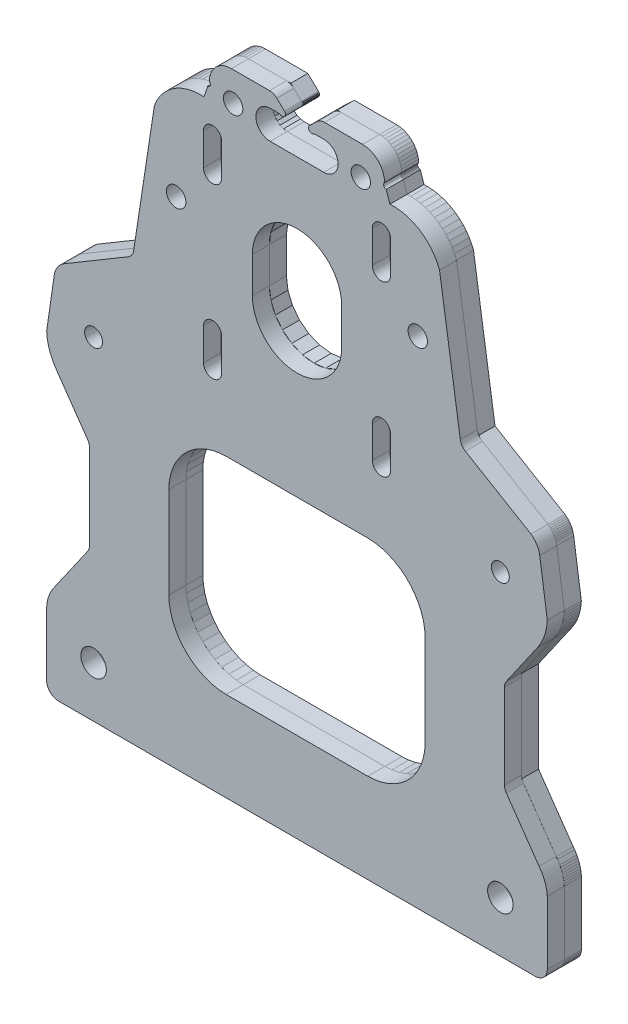
SolidWorks part; units mm, degrees
ref_plane "Front Plane" through (0, 0, 0) normal (0, 0, 1) x (1, 0, 0)
ref_plane "Top Plane" through (0, 0, 0) normal (0, 1, 0) x (1, 0, 0)
ref_plane "Right Plane" through (0, 0, 0) normal (1, 0, 0) x (0, 0, -1)
sketch "Model" plane through (0, 0, 0) normal (0, 0, 1) x (1, 0, 0)
  line L0 (109.789, 90.94) -> (109.3853, 90.4139)
  line L1 (109.3853, 90.4139) -> (109.1316, 89.8013)
  line L2 (109.1316, 89.8013) -> (109.045, 89.1439)
  line L3 (109.045, 89.1439) -> (109.045, 80.1439)
  line L4 (109.045, 80.1439) -> (109.1316, 79.4865)
  line L5 (109.1316, 79.4865) -> (109.3853, 78.8739)
  line L6 (109.3853, 78.8739) -> (109.789, 78.3479)
  line L7 (109.789, 78.3479) -> (110.315, 77.9442)
  line L8 (110.315, 77.9442) -> (110.9276, 77.6905)
  line L9 (110.9276, 77.6905) -> (111.585, 77.6039)
  line L10 (111.585, 77.6039) -> (112.2424, 77.6905)
  line L11 (112.2424, 77.6905) -> (112.855, 77.9442)
  line L12 (112.855, 77.9442) -> (113.3811, 78.3479)
  line L13 (113.3811, 78.3479) -> (113.7847, 78.8739)
  line L14 (113.7847, 78.8739) -> (114.0385, 79.4865)
  line L15 (114.0385, 79.4865) -> (114.125, 80.1439)
  line L16 (114.125, 80.1439) -> (114.125, 89.1439)
  line L17 (114.125, 89.1439) -> (114.0385, 89.8013)
  line L18 (114.0385, 89.8013) -> (113.7847, 90.4139)
  line L19 (113.7847, 90.4139) -> (113.3811, 90.94)
  line L20 (113.3811, 90.94) -> (112.855, 91.3436)
  line L21 (112.855, 91.3436) -> (112.2424, 91.5974)
  line L22 (112.2424, 91.5974) -> (111.585, 91.6839)
  line L23 (111.585, 91.6839) -> (110.9276, 91.5974)
  line L24 (110.9276, 91.5974) -> (110.315, 91.3436)
  line L25 (110.315, 91.3436) -> (109.789, 90.94)
  line L718 (110.315, 125.1881) -> (110.9276, 124.9343)
  line L719 (110.9276, 124.9343) -> (111.585, 124.8478)
  line L720 (111.585, 124.8478) -> (112.2424, 124.9343)
  line L721 (112.2424, 124.9343) -> (112.855, 125.1881)
  line L722 (112.855, 125.1881) -> (113.3811, 125.5917)
  line L723 (113.3811, 125.5917) -> (113.7847, 126.1178)
  line L724 (113.7847, 126.1178) -> (114.0385, 126.7304)
  line L725 (114.0385, 126.7304) -> (114.125, 127.3878)
  line L726 (114.125, 127.3878) -> (114.125, 136.3878)
  line L727 (114.125, 136.3878) -> (114.0385, 137.0452)
  line L728 (114.0385, 137.0452) -> (113.7847, 137.6578)
  line L729 (113.7847, 137.6578) -> (113.3811, 138.1838)
  line L730 (113.3811, 138.1838) -> (112.855, 138.5875)
  line L731 (112.855, 138.5875) -> (112.2424, 138.8412)
  line L732 (112.2424, 138.8412) -> (111.585, 138.9278)
  line L733 (111.585, 138.9278) -> (110.9276, 138.8412)
  line L734 (110.9276, 138.8412) -> (110.315, 138.5875)
  line L735 (110.315, 138.5875) -> (109.789, 138.1838)
  line L736 (109.789, 138.1838) -> (109.3853, 137.6578)
  line L737 (109.3853, 137.6578) -> (109.1316, 137.0452)
  line L738 (109.1316, 137.0452) -> (109.045, 136.3878)
  line L739 (109.045, 136.3878) -> (109.045, 127.3878)
  line L740 (109.045, 127.3878) -> (109.1316, 126.7304)
  line L741 (109.1316, 126.7304) -> (109.3853, 126.1178)
  line L742 (109.3853, 126.1178) -> (109.789, 125.5917)
  line L743 (109.789, 125.5917) -> (110.315, 125.1881)
  line L744 (63.0711, 125.1881) -> (63.6837, 124.9343)
  line L745 (63.6837, 124.9343) -> (64.3411, 124.8478)
  line L746 (64.3411, 124.8478) -> (64.9985, 124.9343)
  line L747 (64.9985, 124.9343) -> (65.6111, 125.1881)
  line L748 (65.6111, 125.1881) -> (66.1372, 125.5917)
  line L749 (66.1372, 125.5917) -> (66.5408, 126.1178)
  line L750 (66.5408, 126.1178) -> (66.7946, 126.7304)
  line L751 (66.7946, 126.7304) -> (66.8811, 127.3878)
  line L752 (66.8811, 127.3878) -> (66.8811, 136.3878)
  line L753 (66.8811, 136.3878) -> (66.7946, 137.0452)
  line L754 (66.7946, 137.0452) -> (66.5408, 137.6578)
  line L755 (66.5408, 137.6578) -> (66.1372, 138.1838)
  line L756 (66.1372, 138.1838) -> (65.6111, 138.5875)
  line L757 (65.6111, 138.5875) -> (64.9985, 138.8412)
  line L758 (64.9985, 138.8412) -> (64.3411, 138.9278)
  line L759 (64.3411, 138.9278) -> (63.6837, 138.8412)
  line L760 (63.6837, 138.8412) -> (63.0711, 138.5875)
  line L761 (63.0711, 138.5875) -> (62.5451, 138.1838)
  line L762 (62.5451, 138.1838) -> (62.1414, 137.6578)
  line L763 (62.1414, 137.6578) -> (61.8877, 137.0452)
  line L764 (61.8877, 137.0452) -> (61.8011, 136.3878)
  line L765 (61.8011, 136.3878) -> (61.8011, 127.3878)
  line L766 (61.8011, 127.3878) -> (61.8877, 126.7304)
  line L767 (61.8877, 126.7304) -> (62.1414, 126.1178)
  line L768 (62.1414, 126.1178) -> (62.5451, 125.5917)
  line L769 (62.5451, 125.5917) -> (63.0711, 125.1881)
  line L770 (81.7231, 92.4327) -> (84.7378, 91.184)
  line L771 (84.7378, 91.184) -> (87.9731, 90.758)
  line L772 (87.9731, 90.758) -> (91.2083, 91.184)
  line L773 (91.2083, 91.184) -> (94.2231, 92.4327)
  line L774 (94.2231, 92.4327) -> (96.8119, 94.4192)
  line L775 (96.8119, 94.4192) -> (98.7984, 97.008)
  line L776 (98.7984, 97.008) -> (100.0471, 100.0228)
  line L777 (100.0471, 100.0228) -> (100.4731, 103.258)
  line L778 (100.4731, 103.258) -> (100.4731, 113.258)
  line L779 (100.4731, 113.258) -> (100.0471, 116.4933)
  line L780 (100.0471, 116.4933) -> (98.7984, 119.508)
  line L781 (98.7984, 119.508) -> (96.8119, 122.0969)
  line L782 (96.8119, 122.0969) -> (94.2231, 124.0834)
  line L783 (94.2231, 124.0834) -> (91.2083, 125.3321)
  line L784 (91.2083, 125.3321) -> (87.9731, 125.758)
  line L785 (87.9731, 125.758) -> (84.7378, 125.3321)
  line L786 (84.7378, 125.3321) -> (81.7231, 124.0834)
  line L787 (81.7231, 124.0834) -> (79.1342, 122.0969)
  line L788 (79.1342, 122.0969) -> (77.1478, 119.508)
  line L789 (77.1478, 119.508) -> (75.899, 116.4933)
  line L790 (75.899, 116.4933) -> (75.4731, 113.258)
  line L791 (75.4731, 113.258) -> (75.4731, 103.258)
  line L792 (75.4731, 103.258) -> (75.899, 100.0228)
  line L793 (75.899, 100.0228) -> (77.1478, 97.008)
  line L794 (77.1478, 97.008) -> (79.1342, 94.4192)
  line L795 (79.1342, 94.4192) -> (81.7231, 92.4327)
  line L796 (63.0711, 77.9442) -> (63.6837, 77.6905)
  line L797 (63.6837, 77.6905) -> (64.3411, 77.6039)
  line L798 (64.3411, 77.6039) -> (64.9985, 77.6905)
  line L799 (64.9985, 77.6905) -> (65.6111, 77.9442)
  line L800 (65.6111, 77.9442) -> (66.1372, 78.3479)
  line L801 (66.1372, 78.3479) -> (66.5408, 78.8739)
  line L802 (66.5408, 78.8739) -> (66.7946, 79.4865)
  line L803 (66.7946, 79.4865) -> (66.8811, 80.1439)
  line L804 (66.8811, 80.1439) -> (66.8811, 89.1439)
  line L805 (66.8811, 89.1439) -> (66.7946, 89.8013)
  line L806 (66.7946, 89.8013) -> (66.5408, 90.4139)
  line L807 (66.5408, 90.4139) -> (66.1372, 90.94)
  line L808 (66.1372, 90.94) -> (65.6111, 91.3436)
  line L809 (65.6111, 91.3436) -> (64.9985, 91.5974)
  line L810 (64.9985, 91.5974) -> (64.3411, 91.6839)
  line L811 (64.3411, 91.6839) -> (63.6837, 91.5974)
  line L812 (63.6837, 91.5974) -> (63.0711, 91.3436)
  line L813 (63.0711, 91.3436) -> (62.5451, 90.94)
  line L814 (62.5451, 90.94) -> (62.1414, 90.4139)
  line L815 (62.1414, 90.4139) -> (61.8877, 89.8013)
  line L816 (61.8877, 89.8013) -> (61.8011, 89.1439)
  line L817 (61.8011, 89.1439) -> (61.8011, 80.1439)
  line L818 (61.8011, 80.1439) -> (61.8877, 79.4865)
  line L819 (61.8877, 79.4865) -> (62.1414, 78.8739)
  line L820 (62.1414, 78.8739) -> (62.5451, 78.3479)
  line L821 (62.5451, 78.3479) -> (63.0711, 77.9442)
  line L822 (60.2236, 5.1518) -> (62.1321, 4.2106)
  line L823 (62.1321, 4.2106) -> (64.1472, 3.5266)
  line L824 (64.1472, 3.5266) -> (66.2343, 3.1114)
  line L825 (66.2343, 3.1114) -> (68.1499, 2.9859)
  line L826 (68.1499, 2.9859) -> (107.7563, 2.9859)
  line L827 (107.7563, 2.9859) -> (109.6718, 3.1114)
  line L828 (109.6718, 3.1114) -> (111.7589, 3.5266)
  line L829 (111.7589, 3.5266) -> (113.774, 4.2106)
  line L830 (113.774, 4.2106) -> (115.6825, 5.1518)
  line L831 (115.6825, 5.1518) -> (117.4519, 6.3341)
  line L832 (117.4519, 6.3341) -> (119.0518, 7.7371)
  line L833 (119.0518, 7.7371) -> (120.4549, 9.3371)
  line L834 (120.4549, 9.3371) -> (121.6372, 11.1064)
  line L835 (121.6372, 11.1064) -> (122.5783, 13.015)
  line L836 (122.5783, 13.015) -> (123.2624, 15.03)
  line L837 (123.2624, 15.03) -> (123.6775, 17.1171)
  line L838 (123.6775, 17.1171) -> (123.8031, 19.0327)
  line L839 (123.8031, 19.0327) -> (123.8031, 44.6391)
  line L840 (123.8031, 44.6391) -> (123.6775, 46.5546)
  line L841 (123.6775, 46.5546) -> (123.2624, 48.6417)
  line L842 (123.2624, 48.6417) -> (122.5783, 50.6568)
  line L843 (122.5783, 50.6568) -> (121.6372, 52.5653)
  line L844 (121.6372, 52.5653) -> (120.4549, 54.3347)
  line L845 (120.4549, 54.3347) -> (119.0518, 55.9346)
  line L846 (119.0518, 55.9346) -> (117.4519, 57.3377)
  line L847 (117.4519, 57.3377) -> (115.6825, 58.52)
  line L848 (115.6825, 58.52) -> (113.774, 59.4612)
  line L849 (113.774, 59.4612) -> (111.7589, 60.1452)
  line L850 (111.7589, 60.1452) -> (109.6718, 60.5603)
  line L851 (109.6718, 60.5603) -> (107.7563, 60.6859)
  line L852 (107.7563, 60.6859) -> (68.1499, 60.6859)
  line L853 (68.1499, 60.6859) -> (66.2343, 60.5603)
  line L854 (66.2343, 60.5603) -> (64.1472, 60.1452)
  line L855 (64.1472, 60.1452) -> (62.1321, 59.4612)
  line L856 (62.1321, 59.4612) -> (60.2236, 58.52)
  line L857 (60.2236, 58.52) -> (58.4542, 57.3377)
  line L858 (58.4542, 57.3377) -> (56.8543, 55.9346)
  line L859 (56.8543, 55.9346) -> (55.4512, 54.3347)
  line L860 (55.4512, 54.3347) -> (54.269, 52.5653)
  line L861 (54.269, 52.5653) -> (53.3278, 50.6568)
  line L862 (53.3278, 50.6568) -> (52.6438, 48.6417)
  line L863 (52.6438, 48.6417) -> (52.2286, 46.5546)
  line L864 (52.2286, 46.5546) -> (52.1031, 44.6391)
  line L865 (52.1031, 44.6391) -> (52.1031, 19.0327)
  line L866 (52.1031, 19.0327) -> (52.2286, 17.1171)
  line L867 (52.2286, 17.1171) -> (52.6438, 15.03)
  line L868 (52.6438, 15.03) -> (53.3278, 13.015)
  line L869 (53.3278, 13.015) -> (54.269, 11.1064)
  line L870 (54.269, 11.1064) -> (55.4512, 9.3371)
  line L871 (55.4512, 9.3371) -> (56.8543, 7.7371)
  line L872 (56.8543, 7.7371) -> (58.4542, 6.3341)
  line L873 (58.4542, 6.3341) -> (60.2236, 5.1518)
  line L874 (21.2959, -22.0621) -> (20.8569, -22.0333)
  line L875 (20.8569, -22.0333) -> (20.4255, -21.9475)
  line L876 (20.4255, -21.9475) -> (20.009, -21.8061)
  line L877 (20.009, -21.8061) -> (19.6145, -21.6116)
  line L878 (19.6145, -21.6116) -> (19.2487, -21.3672)
  line L879 (19.2487, -21.3672) -> (18.918, -21.0772)
  line L880 (18.918, -21.0772) -> (18.628, -20.7465)
  line L881 (18.628, -20.7465) -> (18.3836, -20.3807)
  line L882 (18.3836, -20.3807) -> (18.189, -19.9862)
  line L883 (18.189, -19.9862) -> (18.0477, -19.5697)
  line L884 (18.0477, -19.5697) -> (17.9618, -19.1383)
  line L885 (17.9618, -19.1383) -> (17.9331, -18.6993)
  line L886 (17.9331, -18.6993) -> (17.9478, -0.9272)
  line L887 (17.9478, -0.9272) -> (17.9971, -0.3327)
  line L888 (17.9971, -0.3327) -> (18.0791, 0.2582)
  line L889 (18.0791, 0.2582) -> (18.1937, 0.8437)
  line L890 (18.1937, 0.8437) -> (18.3404, 1.4219)
  line L891 (18.3404, 1.4219) -> (18.5187, 1.9911)
  line L892 (18.5187, 1.9911) -> (18.7283, 2.5496)
  line L893 (18.7283, 2.5496) -> (18.9683, 3.0958)
  line L894 (18.9683, 3.0958) -> (19.2382, 3.6278)
  line L895 (19.2382, 3.6278) -> (19.8638, 4.6431)
  line L896 (19.8638, 4.6431) -> (20.2177, 5.1233)
  line L897 (20.2177, 5.1233) -> (29.9316, 19.0622)
  line L898 (29.9316, 19.0622) -> (29.9233, 44.6095)
  line L899 (29.9233, 44.6095) -> (20.631, 57.9439)
  line L900 (20.631, 57.9439) -> (19.8215, 59.2411)
  line L901 (19.8215, 59.2411) -> (19.4671, 59.9188)
  line L902 (19.4671, 59.9188) -> (19.1475, 60.6136)
  line L903 (19.1475, 60.6136) -> (18.8636, 61.3238)
  line L904 (18.8636, 61.3238) -> (18.616, 62.0474)
  line L905 (18.616, 62.0474) -> (18.4054, 62.7826)
  line L906 (18.4054, 62.7826) -> (18.2323, 63.5276)
  line L907 (18.2323, 63.5276) -> (18.0973, 64.2803)
  line L908 (18.0973, 64.2803) -> (18.0006, 65.039)
  line L909 (18.0006, 65.039) -> (17.9424, 65.8016)
  line L910 (17.9424, 65.8016) -> (17.9423, 65.9473)
  line L911 (17.9423, 65.9473) -> (20.0626, 80.4982)
  line L912 (20.0626, 80.4982) -> (20.252, 81.3499)
  line L913 (20.252, 81.3499) -> (20.3936, 81.7629)
  line L914 (20.3936, 81.7629) -> (20.5654, 82.1643)
  line L915 (20.5654, 82.1643) -> (20.7665, 82.5518)
  line L916 (20.7665, 82.5518) -> (20.9958, 82.9234)
  line L917 (20.9958, 82.9234) -> (21.252, 83.2769)
  line L918 (21.252, 83.2769) -> (21.5337, 83.6105)
  line L919 (21.5337, 83.6105) -> (21.8394, 83.9222)
  line L920 (21.8394, 83.9222) -> (22.1673, 84.2105)
  line L921 (22.1673, 84.2105) -> (22.5157, 84.4736)
  line L922 (22.5157, 84.4736) -> (42.0606, 96.0883)
  line L923 (42.0606, 96.0883) -> (48.0803, 135.6251)
  line L924 (48.0803, 135.6251) -> (48.1021, 135.6609)
  line L925 (48.1021, 135.6609) -> (48.6465, 136.9416)
  line L926 (48.6465, 136.9416) -> (49.3182, 138.1605)
  line L927 (49.3182, 138.1605) -> (50.11, 139.305)
  line L928 (50.11, 139.305) -> (51.0139, 140.3632)
  line L929 (51.0139, 140.3632) -> (52.0205, 141.3243)
  line L930 (52.0205, 141.3243) -> (53.1194, 142.1783)
  line L931 (53.1194, 142.1783) -> (54.2992, 142.9163)
  line L932 (54.2992, 142.9163) -> (55.5479, 143.5309)
  line L933 (55.5479, 143.5309) -> (56.8525, 144.0156)
  line L934 (56.8525, 144.0156) -> (58.1995, 144.3654)
  line L935 (58.1995, 144.3654) -> (59.5751, 144.5768)
  line L936 (59.5751, 144.5768) -> (60.965, 144.6475)
  line L937 (60.965, 144.6475) -> (61.9531, 144.6475)
  line L938 (61.9531, 144.6475) -> (62.9798, 147.7352)
  line L939 (62.9798, 147.7352) -> (63.1364, 147.7624)
  line L940 (63.1364, 147.7624) -> (63.2848, 147.8196)
  line L941 (63.2848, 147.8196) -> (63.4192, 147.9046)
  line L942 (63.4192, 147.9046) -> (63.5345, 148.0141)
  line L943 (63.5345, 148.0141) -> (63.6262, 148.1439)
  line L944 (63.6262, 148.1439) -> (63.6909, 148.2892)
  line L945 (63.6909, 148.2892) -> (63.726, 148.4442)
  line L946 (63.726, 148.4442) -> (63.7303, 148.6032)
  line L947 (63.7303, 148.6032) -> (63.7036, 148.7599)
  line L948 (63.7036, 148.7599) -> (63.6468, 148.9084)
  line L949 (63.6468, 148.9084) -> (63.5623, 149.043)
  line L950 (63.5623, 149.043) -> (63.4531, 149.1586)
  line L951 (63.4531, 149.1586) -> (63.5058, 149.9626)
  line L952 (63.5058, 149.9626) -> (63.6629, 150.7527)
  line L953 (63.6629, 150.7527) -> (63.9219, 151.5157)
  line L954 (63.9219, 151.5157) -> (64.2782, 152.2382)
  line L955 (64.2782, 152.2382) -> (64.7258, 152.9081)
  line L956 (64.7258, 152.9081) -> (65.2571, 153.5138)
  line L957 (65.2571, 153.5138) -> (65.8628, 154.0451)
  line L958 (65.8628, 154.0451) -> (66.5327, 154.4927)
  line L959 (66.5327, 154.4927) -> (67.2553, 154.849)
  line L960 (67.2553, 154.849) -> (68.0182, 155.108)
  line L961 (68.0182, 155.108) -> (68.8083, 155.2652)
  line L962 (68.8083, 155.2652) -> (69.6123, 155.3178)
  line L963 (69.6123, 155.3178) -> (81.4531, 155.3178)
  line L964 (81.4531, 155.3178) -> (84.4531, 152.4715)
  line L965 (84.4531, 152.4715) -> (84.6044, 152.2743)
  line L966 (84.6044, 152.2743) -> (84.6995, 152.0447)
  line L967 (84.6995, 152.0447) -> (84.7319, 151.7983)
  line L968 (84.7319, 151.7983) -> (84.6995, 151.5519)
  line L969 (84.6995, 151.5519) -> (84.6044, 151.3223)
  line L970 (84.6044, 151.3223) -> (84.4531, 151.1251)
  line L971 (84.4531, 151.1251) -> (84.2559, 150.9738)
  line L972 (84.2559, 150.9738) -> (84.0263, 150.8787)
  line L973 (84.0263, 150.8787) -> (83.7799, 150.8463)
  line L974 (83.7799, 150.8463) -> (83.5335, 150.8787)
  line L975 (83.5335, 150.8787) -> (83.3039, 150.9738)
  line L976 (83.3039, 150.9738) -> (83.1067, 151.1251)
  line L977 (83.1067, 151.1251) -> (80.4531, 151.1251)
  line L978 (80.4531, 151.1251) -> (79.4178, 150.9888)
  line L979 (79.4178, 150.9888) -> (78.4531, 150.5892)
  line L980 (78.4531, 150.5892) -> (77.6246, 149.9536)
  line L981 (77.6246, 149.9536) -> (76.989, 149.1251)
  line L982 (76.989, 149.1251) -> (76.5894, 148.1604)
  line L983 (76.5894, 148.1604) -> (76.4531, 147.1251)
  line L984 (76.4531, 147.1251) -> (76.5894, 146.0899)
  line L985 (76.5894, 146.0899) -> (76.989, 145.1251)
  line L986 (76.989, 145.1251) -> (77.6246, 144.2967)
  line L987 (77.6246, 144.2967) -> (78.4531, 143.661)
  line L988 (78.4531, 143.661) -> (79.4178, 143.2614)
  line L989 (79.4178, 143.2614) -> (80.4531, 143.1251)
  line L990 (80.4531, 143.1251) -> (95.4531, 143.1251)
  line L991 (95.4531, 143.1251) -> (96.4883, 143.2614)
  line L992 (96.4883, 143.2614) -> (97.4531, 143.661)
  line L993 (97.4531, 143.661) -> (98.2815, 144.2967)
  line L994 (98.2815, 144.2967) -> (98.9172, 145.1251)
  line L995 (98.9172, 145.1251) -> (99.3168, 146.0899)
  line L996 (99.3168, 146.0899) -> (99.4531, 147.1251)
  line L997 (99.4531, 147.1251) -> (99.3168, 148.1604)
  line L998 (99.3168, 148.1604) -> (98.9172, 149.1251)
  line L999 (98.9172, 149.1251) -> (98.2815, 149.9536)
  line L1000 (98.2815, 149.9536) -> (97.4531, 150.5892)
  line L1001 (97.4531, 150.5892) -> (96.4883, 150.9888)
  line L1002 (96.4883, 150.9888) -> (95.4531, 151.1251)
  line L1003 (95.4531, 151.1251) -> (92.7994, 151.1251)
  line L1004 (92.7994, 151.1251) -> (92.6023, 150.9738)
  line L1005 (92.6023, 150.9738) -> (92.3726, 150.8787)
  line L1006 (92.3726, 150.8787) -> (92.1262, 150.8463)
  line L1007 (92.1262, 150.8463) -> (91.8798, 150.8787)
  line L1008 (91.8798, 150.8787) -> (91.6502, 150.9738)
  line L1009 (91.6502, 150.9738) -> (91.4531, 151.1251)
  line L1010 (91.4531, 151.1251) -> (91.3018, 151.3223)
  line L1011 (91.3018, 151.3223) -> (91.2067, 151.5519)
  line L1012 (91.2067, 151.5519) -> (91.1742, 151.7983)
  line L1013 (91.1742, 151.7983) -> (91.2067, 152.0447)
  line L1014 (91.2067, 152.0447) -> (91.3018, 152.2743)
  line L1015 (91.3018, 152.2743) -> (91.4531, 152.4715)
  line L1016 (91.4531, 152.4715) -> (94.4531, 155.3178)
  line L1017 (94.4531, 155.3178) -> (106.2938, 155.3178)
  line L1018 (106.2938, 155.3178) -> (107.0978, 155.2652)
  line L1019 (107.0978, 155.2652) -> (107.888, 155.108)
  line L1020 (107.888, 155.108) -> (108.6509, 154.849)
  line L1021 (108.6509, 154.849) -> (109.3735, 154.4927)
  line L1022 (109.3735, 154.4927) -> (110.0433, 154.0451)
  line L1023 (110.0433, 154.0451) -> (110.6491, 153.5138)
  line L1024 (110.6491, 153.5138) -> (111.1803, 152.9081)
  line L1025 (111.1803, 152.9081) -> (111.6279, 152.2382)
  line L1026 (111.6279, 152.2382) -> (111.9842, 151.5157)
  line L1027 (111.9842, 151.5157) -> (112.2432, 150.7527)
  line L1028 (112.2432, 150.7527) -> (112.4004, 149.9626)
  line L1029 (112.4004, 149.9626) -> (112.4531, 149.1586)
  line L1030 (112.4531, 149.1586) -> (112.3439, 149.043)
  line L1031 (112.3439, 149.043) -> (112.2593, 148.9084)
  line L1032 (112.2593, 148.9084) -> (112.2025, 148.7599)
  line L1033 (112.2025, 148.7599) -> (112.1758, 148.6032)
  line L1034 (112.1758, 148.6032) -> (112.1801, 148.4442)
  line L1035 (112.1801, 148.4442) -> (112.2153, 148.2892)
  line L1036 (112.2153, 148.2892) -> (112.2799, 148.1439)
  line L1037 (112.2799, 148.1439) -> (112.3717, 148.0141)
  line L1038 (112.3717, 148.0141) -> (112.4869, 147.9046)
  line L1039 (112.4869, 147.9046) -> (112.6213, 147.8196)
  line L1040 (112.6213, 147.8196) -> (112.7697, 147.7624)
  line L1041 (112.7697, 147.7624) -> (112.9264, 147.7352)
  line L1042 (112.9264, 147.7352) -> (113.9531, 144.6475)
  line L1043 (113.9531, 144.6475) -> (114.9412, 144.6475)
  line L1044 (114.9412, 144.6475) -> (116.3311, 144.5768)
  line L1045 (116.3311, 144.5768) -> (117.7066, 144.3654)
  line L1046 (117.7066, 144.3654) -> (119.0536, 144.0156)
  line L1047 (119.0536, 144.0156) -> (120.3582, 143.5309)
  line L1048 (120.3582, 143.5309) -> (121.6069, 142.9163)
  line L1049 (121.6069, 142.9163) -> (122.7868, 142.1783)
  line L1050 (122.7868, 142.1783) -> (123.8857, 141.3243)
  line L1051 (123.8857, 141.3243) -> (124.8922, 140.3632)
  line L1052 (124.8922, 140.3632) -> (125.7961, 139.305)
  line L1053 (125.7961, 139.305) -> (126.5879, 138.1605)
  line L1054 (126.5879, 138.1605) -> (127.2596, 136.9416)
  line L1055 (127.2596, 136.9416) -> (127.8041, 135.6609)
  line L1056 (127.8041, 135.6609) -> (133.824, 96.0886)
  line L1057 (133.824, 96.0886) -> (153.3686, 84.4736)
  line L1058 (153.3686, 84.4736) -> (153.7171, 84.2105)
  line L1059 (153.7171, 84.2105) -> (154.045, 83.9222)
  line L1060 (154.045, 83.9222) -> (154.3506, 83.6105)
  line L1061 (154.3506, 83.6105) -> (154.6323, 83.2769)
  line L1062 (154.6323, 83.2769) -> (154.8885, 82.9234)
  line L1063 (154.8885, 82.9234) -> (155.1178, 82.5518)
  line L1064 (155.1178, 82.5518) -> (155.3189, 82.1643)
  line L1065 (155.3189, 82.1643) -> (155.4907, 81.7629)
  line L1066 (155.4907, 81.7629) -> (155.6323, 81.3499)
  line L1067 (155.6323, 81.3499) -> (155.8218, 80.4982)
  line L1068 (155.8218, 80.4982) -> (157.9633, 65.8016)
  line L1069 (157.9633, 65.8016) -> (157.9051, 65.039)
  line L1070 (157.9051, 65.039) -> (157.8084, 64.2803)
  line L1071 (157.8084, 64.2803) -> (157.6734, 63.5276)
  line L1072 (157.6734, 63.5276) -> (157.5003, 62.7826)
  line L1073 (157.5003, 62.7826) -> (157.2897, 62.0474)
  line L1074 (157.2897, 62.0474) -> (157.0421, 61.3238)
  line L1075 (157.0421, 61.3238) -> (156.7582, 60.6136)
  line L1076 (156.7582, 60.6136) -> (156.4386, 59.9188)
  line L1077 (156.4386, 59.9188) -> (156.0842, 59.2411)
  line L1078 (156.0842, 59.2411) -> (155.2747, 57.9439)
  line L1079 (155.2747, 57.9439) -> (145.9824, 44.6095)
  line L1080 (145.9824, 44.6095) -> (145.9899, 19.0622)
  line L1081 (145.9899, 19.0622) -> (155.7038, 5.1233)
  line L1082 (155.7038, 5.1233) -> (156.0577, 4.6431)
  line L1083 (156.0577, 4.6431) -> (156.6833, 3.6278)
  line L1084 (156.6833, 3.6278) -> (156.9532, 3.0958)
  line L1085 (156.9532, 3.0958) -> (157.1932, 2.5496)
  line L1086 (157.1932, 2.5496) -> (157.4028, 1.9911)
  line L1087 (157.4028, 1.9911) -> (157.5811, 1.4219)
  line L1088 (157.5811, 1.4219) -> (157.7278, 0.8437)
  line L1089 (157.7278, 0.8437) -> (157.8424, 0.2582)
  line L1090 (157.8424, 0.2582) -> (157.9244, -0.3327)
  line L1091 (157.9244, -0.3327) -> (157.9737, -0.9272)
  line L1092 (157.9737, -0.9272) -> (157.9731, -18.6993)
  line L1093 (157.9731, -18.6993) -> (157.9443, -19.1383)
  line L1094 (157.9443, -19.1383) -> (157.8585, -19.5697)
  line L1095 (157.8585, -19.5697) -> (157.7171, -19.9862)
  line L1096 (157.7171, -19.9862) -> (157.5225, -20.3807)
  line L1097 (157.5225, -20.3807) -> (157.2782, -20.7465)
  line L1098 (157.2782, -20.7465) -> (156.9881, -21.0772)
  line L1099 (156.9881, -21.0772) -> (156.6574, -21.3672)
  line L1100 (156.6574, -21.3672) -> (156.2917, -21.6116)
  line L1101 (156.2917, -21.6116) -> (155.8972, -21.8061)
  line L1102 (155.8972, -21.8061) -> (155.4806, -21.9475)
  line L1103 (155.4806, -21.9475) -> (155.0492, -22.0333)
  line L1104 (155.0492, -22.0333) -> (154.6103, -22.0621)
  line L1105 (154.6103, -22.0621) -> (21.2959, -22.0621)
  circle A20 centre (54.1659, 116.5772) radius 2.7153
  circle A21 centre (70.0935, 147.1251) radius 2.7153
  circle A22 centre (105.8127, 147.1251) radius 2.7153
  circle A23 centre (121.7803, 116.5772) radius 2.7153
  circle A24 centre (31.0699, 71.0032) radius 2.5006
  circle A25 centre (144.8362, 71.0032) radius 2.5006
  circle A26 centre (31.0614, -7.8668) radius 3.5687
  circle A27 centre (144.8447, -7.8668) radius 3.5687
sketch "Sketch2" plane through (0, 0, 0) normal (0, 0, 1) x (1, 0, 0)
  line L0 (109.789, 90.94) -> (109.3853, 90.4139)
  line L1 (109.3853, 90.4139) -> (109.1316, 89.8013)
  line L2 (109.1316, 89.8013) -> (109.045, 89.1439)
  line L3 (109.045, 89.1439) -> (109.045, 80.1439)
  line L4 (109.045, 80.1439) -> (109.1316, 79.4865)
  line L5 (109.1316, 79.4865) -> (109.3853, 78.8739)
  line L6 (109.3853, 78.8739) -> (109.789, 78.3479)
  line L7 (109.789, 78.3479) -> (110.315, 77.9442)
  line L8 (110.315, 77.9442) -> (110.9276, 77.6905)
  line L9 (110.9276, 77.6905) -> (111.585, 77.6039)
  line L10 (111.585, 77.6039) -> (112.2424, 77.6905)
  line L11 (112.2424, 77.6905) -> (112.855, 77.9442)
  line L12 (112.855, 77.9442) -> (113.3811, 78.3479)
  line L13 (113.3811, 78.3479) -> (113.7847, 78.8739)
  line L14 (113.7847, 78.8739) -> (114.0385, 79.4865)
  line L15 (114.0385, 79.4865) -> (114.125, 80.1439)
  line L16 (114.125, 80.1439) -> (114.125, 89.1439)
  line L17 (114.125, 89.1439) -> (114.0385, 89.8013)
  line L18 (114.0385, 89.8013) -> (113.7847, 90.4139)
  line L19 (113.7847, 90.4139) -> (113.3811, 90.94)
  line L20 (113.3811, 90.94) -> (112.855, 91.3436)
  line L21 (112.855, 91.3436) -> (112.2424, 91.5974)
  line L22 (112.2424, 91.5974) -> (111.585, 91.6839)
  line L23 (111.585, 91.6839) -> (110.9276, 91.5974)
  line L24 (110.9276, 91.5974) -> (110.315, 91.3436)
  line L25 (110.315, 91.3436) -> (109.789, 90.94)
  line L26 (-149.8395, -1.0925) -> (-148.8536, -1.1801)
  line L27 (-148.8536, -1.1801) -> (-147.9616, -1.4429)
  line L28 (-147.9616, -1.4429) -> (-147.1634, -1.8809)
  line L29 (-147.1634, -1.8809) -> (-146.4592, -2.4942)
  line L30 (-146.4592, -2.4942) -> (-145.8841, -3.2508)
  line L31 (-145.8841, -3.2508) -> (-145.4733, -4.119)
  line L32 (-145.4733, -4.119) -> (-145.2268, -5.0986)
  line L33 (-145.2268, -5.0986) -> (-145.1447, -6.1897)
  line L34 (-145.1447, -6.1897) -> (-145.2272, -7.2773)
  line L35 (-145.2272, -7.2773) -> (-145.475, -8.2529)
  line L36 (-145.475, -8.2529) -> (-145.8879, -9.1167)
  line L37 (-145.8879, -9.1167) -> (-146.4659, -9.8685)
  line L38 (-146.4659, -9.8685) -> (-147.1722, -10.4773)
  line L39 (-147.1722, -10.4773) -> (-147.9699, -10.9122)
  line L40 (-147.9699, -10.9122) -> (-148.859, -11.1732)
  line L41 (-148.859, -11.1732) -> (-149.8395, -11.2601)
  line L42 (-149.8395, -11.2601) -> (-150.8506, -11.17)
  line L43 (-150.8506, -11.17) -> (-151.7577, -10.8996)
  line L44 (-151.7577, -10.8996) -> (-152.5608, -10.449)
  line L45 (-152.5608, -10.449) -> (-153.26, -9.8182)
  line L46 (-153.26, -9.8182) -> (-153.8263, -9.0573)
  line L47 (-153.8263, -9.0573) -> (-154.2308, -8.2169)
  line L48 (-154.2308, -8.2169) -> (-154.4736, -7.2968)
  line L49 (-154.4736, -7.2968) -> (-154.5545, -6.297)
  line L50 (-154.5545, -6.297) -> (-154.4725, -5.1508)
  line L51 (-154.4725, -5.1508) -> (-154.2267, -4.1332)
  line L52 (-154.2267, -4.1332) -> (-153.8169, -3.2443)
  line L53 (-153.8169, -3.2443) -> (-153.2433, -2.4841)
  line L54 (-153.2433, -2.4841) -> (-152.5388, -1.8753)
  line L55 (-152.5388, -1.8753) -> (-151.7367, -1.4404)
  line L56 (-151.7367, -1.4404) -> (-150.8369, -1.1794)
  line L57 (-150.8369, -1.1794) -> (-149.8395, -1.0925)
  line L58 (-149.8529, -10.1468) -> (-149.1405, -10.0814)
  line L59 (-149.1405, -10.0814) -> (-148.499, -9.8852)
  line L60 (-148.499, -9.8852) -> (-147.9282, -9.5583)
  line L61 (-147.9282, -9.5583) -> (-147.4284, -9.1005)
  line L62 (-147.4284, -9.1005) -> (-147.0215, -8.5262)
  line L63 (-147.0215, -8.5262) -> (-146.73, -7.8497)
  line L64 (-146.73, -7.8497) -> (-146.5537, -7.0708)
  line L65 (-146.5537, -7.0708) -> (-146.4927, -6.1897)
  line L66 (-146.4927, -6.1897) -> (-146.5521, -5.286)
  line L67 (-146.5521, -5.286) -> (-146.73, -4.4929)
  line L68 (-146.73, -4.4929) -> (-147.0266, -3.8104)
  line L69 (-147.0266, -3.8104) -> (-147.4418, -3.2387)
  line L70 (-147.4418, -3.2387) -> (-147.9467, -2.7868)
  line L71 (-147.9467, -2.7868) -> (-148.5124, -2.464)
  line L72 (-148.5124, -2.464) -> (-149.1388, -2.2704)
  line L73 (-149.1388, -2.2704) -> (-149.8261, -2.2058)
  line L74 (-149.8261, -2.2058) -> (-150.5311, -2.2691)
  line L75 (-150.5311, -2.2691) -> (-151.1708, -2.459)
  line L76 (-151.1708, -2.459) -> (-151.7451, -2.7755)
  line L77 (-151.7451, -2.7755) -> (-152.254, -3.2186)
  line L78 (-152.254, -3.2186) -> (-152.6707, -3.7924)
  line L79 (-152.6707, -3.7924) -> (-152.9683, -4.5012)
  line L80 (-152.9683, -4.5012) -> (-153.1468, -5.3451)
  line L81 (-153.1468, -5.3451) -> (-153.2064, -6.3239)
  line L82 (-153.2064, -6.3239) -> (-153.1481, -7.1381)
  line L83 (-153.1481, -7.1381) -> (-152.9733, -7.8706)
  line L84 (-152.9733, -7.8706) -> (-152.682, -8.5214)
  line L85 (-152.682, -8.5214) -> (-152.2741, -9.0905)
  line L86 (-152.2741, -9.0905) -> (-151.7732, -9.5526)
  line L87 (-151.7732, -9.5526) -> (-151.2027, -9.8827)
  line L88 (-151.2027, -9.8827) -> (-150.5626, -10.0808)
  line L89 (-150.5626, -10.0808) -> (-149.8529, -10.1468)
  line L90 (-142.4552, -4.8953) -> (-142.0742, -4.4229)
  line L91 (-142.0742, -4.4229) -> (-141.6084, -4.0854)
  line L92 (-141.6084, -4.0854) -> (-141.0581, -3.883)
  line L93 (-141.0581, -3.883) -> (-140.423, -3.8155)
  line L94 (-140.423, -3.8155) -> (-139.759, -3.879)
  line L95 (-139.759, -3.879) -> (-139.1688, -4.0695)
  line L96 (-139.1688, -4.0695) -> (-138.6524, -4.387)
  line L97 (-138.6524, -4.387) -> (-138.2097, -4.8316)
  line L98 (-138.2097, -4.8316) -> (-137.8547, -5.378)
  line L99 (-137.8547, -5.378) -> (-137.6011, -6.0011)
  line L100 (-137.6011, -6.0011) -> (-137.4489, -6.7009)
  line L101 (-137.4489, -6.7009) -> (-137.3982, -7.4774)
  line L102 (-137.3982, -7.4774) -> (-137.4544, -8.3013)
  line L103 (-137.4544, -8.3013) -> (-137.6229, -9.036)
  line L104 (-137.6229, -9.036) -> (-137.9037, -9.6813)
  line L105 (-137.9037, -9.6813) -> (-138.2969, -10.2373)
  line L106 (-138.2969, -10.2373) -> (-138.7718, -10.6848)
  line L107 (-138.7718, -10.6848) -> (-139.2979, -11.0044)
  line L108 (-139.2979, -11.0044) -> (-139.8751, -11.1962)
  line L109 (-139.8751, -11.1962) -> (-140.5035, -11.2601)
  line L110 (-140.5035, -11.2601) -> (-141.0484, -11.2031)
  line L111 (-141.0484, -11.2031) -> (-141.5363, -11.0321)
  line L112 (-141.5363, -11.0321) -> (-141.9673, -10.7471)
  line L113 (-141.9673, -10.7471) -> (-142.3412, -10.348)
  line L114 (-142.3412, -10.348) -> (-142.3747, -10.348)
  line L115 (-142.3747, -10.348) -> (-142.3747, -13.8289)
  line L116 (-142.3747, -13.8289) -> (-143.582, -13.8289)
  line L117 (-143.582, -13.8289) -> (-143.582, -3.9764)
  line L118 (-143.582, -3.9764) -> (-142.482, -3.9764)
  line L119 (-142.482, -3.9764) -> (-142.482, -4.8953)
  line L120 (-142.482, -4.8953) -> (-142.4552, -4.8953)
  line L121 (-140.584, -10.2675) -> (-140.1797, -10.2237)
  line L122 (-140.1797, -10.2237) -> (-139.8118, -10.0923)
  line L123 (-139.8118, -10.0923) -> (-139.4805, -9.8733)
  line L124 (-139.4805, -9.8733) -> (-139.1856, -9.5666)
  line L125 (-139.1856, -9.5666) -> (-138.9435, -9.1732)
  line L126 (-138.9435, -9.1732) -> (-138.7706, -8.6939)
  line L127 (-138.7706, -8.6939) -> (-138.6668, -8.1286)
  line L128 (-138.6668, -8.1286) -> (-138.6323, -7.4774)
  line L129 (-138.6323, -7.4774) -> (-138.7656, -6.3205)
  line L130 (-138.7656, -6.3205) -> (-138.9322, -5.8552)
  line L131 (-138.9322, -5.8552) -> (-139.1655, -5.4654)
  line L132 (-139.1655, -5.4654) -> (-139.4507, -5.1573)
  line L133 (-139.4507, -5.1573) -> (-139.7733, -4.9372)
  line L134 (-139.7733, -4.9372) -> (-140.1331, -4.8052)
  line L135 (-140.1331, -4.8052) -> (-140.5303, -4.7611)
  line L136 (-140.5303, -4.7611) -> (-140.9405, -4.8102)
  line L137 (-140.9405, -4.8102) -> (-141.3125, -4.9573)
  line L138 (-141.3125, -4.9573) -> (-141.6464, -5.2025)
  line L139 (-141.6464, -5.2025) -> (-141.9421, -5.5459)
  line L140 (-141.9421, -5.5459) -> (-142.1842, -5.9671)
  line L141 (-142.1842, -5.9671) -> (-142.3571, -6.4463)
  line L142 (-142.3571, -6.4463) -> (-142.4609, -6.9832)
  line L143 (-142.4609, -6.9832) -> (-142.4954, -7.578)
  line L144 (-142.4954, -7.578) -> (-142.363, -8.74)
  line L145 (-142.363, -8.74) -> (-142.1974, -9.2015)
  line L146 (-142.1974, -9.2015) -> (-141.9656, -9.5834)
  line L147 (-141.9656, -9.5834) -> (-141.6805, -9.8827)
  line L148 (-141.6805, -9.8827) -> (-141.3553, -10.0965)
  line L149 (-141.3553, -10.0965) -> (-140.9897, -10.2248)
  line L150 (-140.9897, -10.2248) -> (-140.584, -10.2675)
  line L151 (-133.1795, -11.0791) -> (-134.085, -11.1864)
  line L152 (-134.085, -11.1864) -> (-134.7691, -11.1168)
  line L153 (-134.7691, -11.1168) -> (-135.2386, -10.908)
  line L154 (-135.2386, -10.908) -> (-135.5303, -10.592)
  line L155 (-135.5303, -10.592) -> (-135.6812, -10.2004)
  line L156 (-135.6812, -10.2004) -> (-135.7617, -9.0066)
  line L157 (-135.7617, -9.0066) -> (-135.7617, -4.9087)
  line L158 (-135.7617, -4.9087) -> (-136.6403, -4.9087)
  line L159 (-136.6403, -4.9087) -> (-136.6403, -3.9764)
  line L160 (-136.6403, -3.9764) -> (-135.7617, -3.9764)
  line L161 (-135.7617, -3.9764) -> (-135.7617, -2.2058)
  line L162 (-135.7617, -2.2058) -> (-134.5545, -1.4748)
  line L163 (-134.5545, -1.4748) -> (-134.5545, -3.9764)
  line L164 (-134.5545, -3.9764) -> (-133.3472, -3.9764)
  line L165 (-133.3472, -3.9764) -> (-133.3472, -4.9087)
  line L166 (-133.3472, -4.9087) -> (-134.5545, -4.9087)
  line L167 (-134.5545, -4.9087) -> (-134.5545, -9.0737)
  line L168 (-134.5545, -9.0737) -> (-134.5268, -9.5323)
  line L169 (-134.5268, -9.5323) -> (-134.4438, -9.8349)
  line L170 (-134.4438, -9.8349) -> (-134.2485, -10.0034)
  line L171 (-134.2485, -10.0034) -> (-133.8838, -10.0596)
  line L172 (-133.8838, -10.0596) -> (-133.3472, -10.0059)
  line L173 (-133.3472, -10.0059) -> (-133.1795, -11.0791)
  line L174 (-130.9327, -11.0925) -> (-132.14, -11.0925)
  line L175 (-132.14, -11.0925) -> (-132.14, -3.9764)
  line L176 (-132.14, -3.9764) -> (-130.9327, -3.9764)
  line L177 (-130.9327, -3.9764) -> (-130.9327, -11.0925)
  line L178 (-130.9327, -2.6283) -> (-132.14, -2.6283)
  line L179 (-132.14, -2.6283) -> (-132.14, -1.2601)
  line L180 (-132.14, -1.2601) -> (-130.9327, -1.2601)
  line L181 (-130.9327, -1.2601) -> (-130.9327, -2.6283)
  line L182 (-126.1909, -3.8155) -> (-125.5008, -3.8742)
  line L183 (-125.5008, -3.8742) -> (-124.8722, -4.0502)
  line L184 (-124.8722, -4.0502) -> (-124.3052, -4.3436)
  line L185 (-124.3052, -4.3436) -> (-123.7999, -4.7544)
  line L186 (-123.7999, -4.7544) -> (-123.3847, -5.2734)
  line L187 (-123.3847, -5.2734) -> (-123.0882, -5.8913)
  line L188 (-123.0882, -5.8913) -> (-122.9102, -6.6081)
  line L189 (-122.9102, -6.6081) -> (-122.8509, -7.4238)
  line L190 (-122.8509, -7.4238) -> (-122.915, -8.3965)
  line L191 (-122.915, -8.3965) -> (-123.1074, -9.2154)
  line L192 (-123.1074, -9.2154) -> (-123.4281, -9.8804)
  line L193 (-123.4281, -9.8804) -> (-123.8771, -10.3916)
  line L194 (-123.8771, -10.3916) -> (-124.4065, -10.7716)
  line L195 (-124.4065, -10.7716) -> (-124.9686, -11.043)
  line L196 (-124.9686, -11.043) -> (-125.5634, -11.2059)
  line L197 (-125.5634, -11.2059) -> (-126.1909, -11.2601)
  line L198 (-126.1909, -11.2601) -> (-126.8428, -11.2044)
  line L199 (-126.8428, -11.2044) -> (-127.4502, -11.0371)
  line L200 (-127.4502, -11.0371) -> (-128.0131, -10.7584)
  line L201 (-128.0131, -10.7584) -> (-128.5316, -10.3681)
  line L202 (-128.5316, -10.3681) -> (-128.9659, -9.8567)
  line L203 (-128.9659, -9.8567) -> (-129.2761, -9.2145)
  line L204 (-129.2761, -9.2145) -> (-129.4622, -8.4416)
  line L205 (-129.4622, -8.4416) -> (-129.5243, -7.5378)
  line L206 (-129.5243, -7.5378) -> (-129.4643, -6.6586)
  line L207 (-129.4643, -6.6586) -> (-129.2845, -5.8988)
  line L208 (-129.2845, -5.8988) -> (-128.9848, -5.2585)
  line L209 (-128.9848, -5.2585) -> (-128.5652, -4.7377)
  line L210 (-128.5652, -4.7377) -> (-128.0571, -4.3342)
  line L211 (-128.0571, -4.3342) -> (-127.4921, -4.046)
  line L212 (-127.4921, -4.046) -> (-126.87, -3.8731)
  line L213 (-126.87, -3.8731) -> (-126.1909, -3.8155)
  line L214 (-126.1909, -10.2675) -> (-125.7055, -10.2197)
  line L215 (-125.7055, -10.2197) -> (-125.2822, -10.0764)
  line L216 (-125.2822, -10.0764) -> (-124.9208, -9.8374)
  line L217 (-124.9208, -9.8374) -> (-124.6215, -9.5029)
  line L218 (-124.6215, -9.5029) -> (-124.3868, -9.0905)
  line L219 (-124.3868, -9.0905) -> (-124.2191, -8.6176)
  line L220 (-124.2191, -8.6176) -> (-124.085, -7.4909)
  line L221 (-124.085, -7.4909) -> (-124.1229, -6.8646)
  line L222 (-124.1229, -6.8646) -> (-124.2367, -6.3205)
  line L223 (-124.2367, -6.3205) -> (-124.4264, -5.8586)
  line L224 (-124.4264, -5.8586) -> (-124.6919, -5.4788)
  line L225 (-124.6919, -5.4788) -> (-125.0132, -5.1824)
  line L226 (-125.0132, -5.1824) -> (-125.3702, -4.9707)
  line L227 (-125.3702, -4.9707) -> (-125.7627, -4.8437)
  line L228 (-125.7627, -4.8437) -> (-126.1909, -4.8014)
  line L229 (-126.1909, -4.8014) -> (-126.6298, -4.8444)
  line L230 (-126.6298, -4.8444) -> (-127.0276, -4.9732)
  line L231 (-127.0276, -4.9732) -> (-127.3843, -5.1881)
  line L232 (-127.3843, -5.1881) -> (-127.7, -5.4888)
  line L233 (-127.7, -5.4888) -> (-127.9582, -5.8747)
  line L234 (-127.9582, -5.8747) -> (-128.1426, -6.3448)
  line L235 (-128.1426, -6.3448) -> (-128.2533, -6.8992)
  line L236 (-128.2533, -6.8992) -> (-128.2902, -7.5378)
  line L237 (-128.2902, -7.5378) -> (-128.2527, -8.1735)
  line L238 (-128.2527, -8.1735) -> (-128.1401, -8.7258)
  line L239 (-128.1401, -8.7258) -> (-127.9526, -9.1946)
  line L240 (-127.9526, -9.1946) -> (-127.6899, -9.5801)
  line L241 (-127.6899, -9.5801) -> (-127.3711, -9.8808)
  line L242 (-127.3711, -9.8808) -> (-127.0151, -10.0956)
  line L243 (-127.0151, -10.0956) -> (-126.6216, -10.2245)
  line L244 (-126.6216, -10.2245) -> (-126.1909, -10.2675)
  line L245 (-115.6343, -11.0925) -> (-116.8482, -11.0925)
  line L246 (-116.8482, -11.0925) -> (-116.8482, -6.7665)
  line L247 (-116.8482, -6.7665) -> (-116.9463, -5.8443)
  line L248 (-116.9463, -5.8443) -> (-117.0689, -5.5115)
  line L249 (-117.0689, -5.5115) -> (-117.2406, -5.2642)
  line L250 (-117.2406, -5.2642) -> (-117.7092, -4.9573)
  line L251 (-117.7092, -4.9573) -> (-118.3304, -4.855)
  line L252 (-118.3304, -4.855) -> (-118.8527, -4.9204)
  line L253 (-118.8527, -4.9204) -> (-119.3465, -5.1166)
  line L254 (-119.3465, -5.1166) -> (-119.7565, -5.4318)
  line L255 (-119.7565, -5.4318) -> (-120.0273, -5.8544)
  line L256 (-120.0273, -5.8544) -> (-120.1782, -6.4295)
  line L257 (-120.1782, -6.4295) -> (-120.2285, -7.2025)
  line L258 (-120.2285, -7.2025) -> (-120.2285, -11.0925)
  line L259 (-120.2285, -11.0925) -> (-121.4357, -11.0925)
  line L260 (-121.4357, -11.0925) -> (-121.4357, -3.9764)
  line L261 (-121.4357, -3.9764) -> (-120.3492, -3.9764)
  line L262 (-120.3492, -3.9764) -> (-120.3492, -4.9825)
  line L263 (-120.3492, -4.9825) -> (-120.3224, -4.9825)
  line L264 (-120.3224, -4.9825) -> (-119.8957, -4.4719)
  line L265 (-119.8957, -4.4719) -> (-119.3801, -4.1072)
  line L266 (-119.3801, -4.1072) -> (-118.7756, -3.8884)
  line L267 (-118.7756, -3.8884) -> (-118.0823, -3.8155)
  line L268 (-118.0823, -3.8155) -> (-117.5223, -3.8658)
  line L269 (-117.5223, -3.8658) -> (-116.9689, -4.0167)
  line L270 (-116.9689, -4.0167) -> (-116.4785, -4.2682)
  line L271 (-116.4785, -4.2682) -> (-116.1071, -4.6203)
  line L272 (-116.1071, -4.6203) -> (-115.8531, -5.0361)
  line L273 (-115.8531, -5.0361) -> (-115.7147, -5.4788)
  line L274 (-115.7147, -5.4788) -> (-115.6343, -6.7129)
  line L275 (-115.6343, -6.7129) -> (-115.6343, -11.0925)
  line L276 (-107.6396, -11.0925) -> (-108.9072, -11.0925)
  line L277 (-108.9072, -11.0925) -> (-109.0565, -10.7051)
  line L278 (-109.0565, -10.7051) -> (-109.1554, -10.2139)
  line L279 (-109.1554, -10.2139) -> (-109.7745, -10.6716)
  line L280 (-109.7745, -10.6716) -> (-110.418, -10.9986)
  line L281 (-110.418, -10.9986) -> (-111.0857, -11.1947)
  line L282 (-111.0857, -11.1947) -> (-111.7778, -11.2601)
  line L283 (-111.7778, -11.2601) -> (-112.3114, -11.2249)
  line L284 (-112.3114, -11.2249) -> (-112.7855, -11.1193)
  line L285 (-112.7855, -11.1193) -> (-113.2001, -10.9432)
  line L286 (-113.2001, -10.9432) -> (-113.5551, -10.6968)
  line L287 (-113.5551, -10.6968) -> (-113.8397, -10.3924)
  line L288 (-113.8397, -10.3924) -> (-114.0431, -10.0428)
  line L289 (-114.0431, -10.0428) -> (-114.165, -9.648)
  line L290 (-114.165, -9.648) -> (-114.2057, -9.2078)
  line L291 (-114.2057, -9.2078) -> (-114.1665, -8.7847)
  line L292 (-114.1665, -8.7847) -> (-114.0489, -8.4005)
  line L293 (-114.0489, -8.4005) -> (-113.853, -8.0553)
  line L294 (-113.853, -8.0553) -> (-113.5786, -7.7491)
  line L295 (-113.5786, -7.7491) -> (-113.2074, -7.4865)
  line L296 (-113.2074, -7.4865) -> (-112.721, -7.272)
  line L297 (-112.721, -7.272) -> (-111.4022, -6.9878)
  line L298 (-111.4022, -6.9878) -> (-110.2754, -6.8202)
  line L299 (-110.2754, -6.8202) -> (-109.2359, -6.572)
  line L300 (-109.2359, -6.572) -> (-109.2694, -5.8041)
  line L301 (-109.2694, -5.8041) -> (-109.4673, -5.3379)
  line L302 (-109.4673, -5.3379) -> (-109.681, -5.12)
  line L303 (-109.681, -5.12) -> (-109.9938, -4.9489)
  line L304 (-109.9938, -4.9489) -> (-110.418, -4.8383)
  line L305 (-110.418, -4.8383) -> (-110.9663, -4.8014)
  line L306 (-110.9663, -4.8014) -> (-111.6629, -4.8735)
  line L307 (-111.6629, -4.8735) -> (-112.197, -5.0898)
  line L308 (-112.197, -5.0898) -> (-112.5784, -5.5023)
  line L309 (-112.5784, -5.5023) -> (-112.8174, -6.1629)
  line L310 (-112.8174, -6.1629) -> (-113.9978, -6.0086)
  line L311 (-113.9978, -6.0086) -> (-113.8624, -5.496)
  line L312 (-113.8624, -5.496) -> (-113.6507, -5.0512)
  line L313 (-113.6507, -5.0512) -> (-113.3627, -4.6744)
  line L314 (-113.3627, -4.6744) -> (-112.9985, -4.3654)
  line L315 (-112.9985, -4.3654) -> (-112.5583, -4.1248)
  line L316 (-112.5583, -4.1248) -> (-112.0427, -3.953)
  line L317 (-112.0427, -3.953) -> (-111.4517, -3.8498)
  line L318 (-111.4517, -3.8498) -> (-110.7852, -3.8155)
  line L319 (-110.7852, -3.8155) -> (-109.6743, -3.9102)
  line L320 (-109.6743, -3.9102) -> (-108.9039, -4.1944)
  line L321 (-108.9039, -4.1944) -> (-108.4193, -4.6128)
  line L322 (-108.4193, -4.6128) -> (-108.1661, -5.1099)
  line L323 (-108.1661, -5.1099) -> (-108.063, -5.7236)
  line L324 (-108.063, -5.7236) -> (-108.0286, -6.4915)
  line L325 (-108.0286, -6.4915) -> (-108.0286, -8.1146)
  line L326 (-108.0286, -8.1146) -> (-107.9716, -10.1032)
  line L327 (-107.9716, -10.1032) -> (-107.8601, -10.6037)
  line L328 (-107.8601, -10.6037) -> (-107.6396, -11.0925)
  line L329 (-109.2359, -7.9603) -> (-109.2359, -7.5244)
  line L330 (-109.2359, -7.5244) -> (-110.2872, -7.8069)
  line L331 (-110.2872, -7.8069) -> (-111.5498, -8.0241)
  line L332 (-111.5498, -8.0241) -> (-112.1484, -8.1655)
  line L333 (-112.1484, -8.1655) -> (-112.5759, -8.4055)
  line L334 (-112.5759, -8.4055) -> (-112.8325, -8.744)
  line L335 (-112.8325, -8.744) -> (-112.918, -9.181)
  line L336 (-112.918, -9.181) -> (-112.8257, -9.6278)
  line L337 (-112.8257, -9.6278) -> (-112.5491, -9.9892)
  line L338 (-112.5491, -9.9892) -> (-112.0997, -10.2281)
  line L339 (-112.0997, -10.2281) -> (-111.4894, -10.3078)
  line L340 (-111.4894, -10.3078) -> (-110.6502, -10.1745)
  line L341 (-110.6502, -10.1745) -> (-109.9166, -9.7746)
  line L342 (-109.9166, -9.7746) -> (-109.6188, -9.4612)
  line L343 (-109.6188, -9.4612) -> (-109.4061, -9.0544)
  line L344 (-109.4061, -9.0544) -> (-109.2784, -8.5541)
  line L345 (-109.2784, -8.5541) -> (-109.2359, -7.9603)
  line L346 (-104.9636, -11.0925) -> (-106.1708, -11.0925)
  line L347 (-106.1708, -11.0925) -> (-106.1708, -1.2601)
  line L348 (-106.1708, -1.2601) -> (-104.9636, -1.2601)
  line L349 (-104.9636, -1.2601) -> (-104.9636, -11.0925)
  line L350 (-92.1333, -2.4271) -> (-95.3861, -2.4271)
  line L351 (-95.3861, -2.4271) -> (-95.3861, -11.0925)
  line L352 (-95.3861, -11.0925) -> (-96.694, -11.0925)
  line L353 (-96.694, -11.0925) -> (-96.694, -2.4271)
  line L354 (-96.694, -2.4271) -> (-99.92, -2.4271)
  line L355 (-99.92, -2.4271) -> (-99.92, -1.2601)
  line L356 (-99.92, -1.2601) -> (-92.1333, -1.2601)
  line L357 (-92.1333, -1.2601) -> (-92.1333, -2.4271)
  line L358 (-84.7422, -11.0925) -> (-86.0099, -11.0925)
  line L359 (-86.0099, -11.0925) -> (-86.1591, -10.7051)
  line L360 (-86.1591, -10.7051) -> (-86.258, -10.2139)
  line L361 (-86.258, -10.2139) -> (-86.8771, -10.6716)
  line L362 (-86.8771, -10.6716) -> (-87.5206, -10.9986)
  line L363 (-87.5206, -10.9986) -> (-88.1883, -11.1947)
  line L364 (-88.1883, -11.1947) -> (-88.8804, -11.2601)
  line L365 (-88.8804, -11.2601) -> (-89.414, -11.2249)
  line L366 (-89.414, -11.2249) -> (-89.8881, -11.1193)
  line L367 (-89.8881, -11.1193) -> (-90.3027, -10.9432)
  line L368 (-90.3027, -10.9432) -> (-90.6577, -10.6968)
  line L369 (-90.6577, -10.6968) -> (-90.9424, -10.3924)
  line L370 (-90.9424, -10.3924) -> (-91.1457, -10.0428)
  line L371 (-91.1457, -10.0428) -> (-91.2676, -9.648)
  line L372 (-91.2676, -9.648) -> (-91.3083, -9.2078)
  line L373 (-91.3083, -9.2078) -> (-91.2691, -8.7847)
  line L374 (-91.2691, -8.7847) -> (-91.1515, -8.4005)
  line L375 (-91.1515, -8.4005) -> (-90.9556, -8.0553)
  line L376 (-90.9556, -8.0553) -> (-90.6812, -7.7491)
  line L377 (-90.6812, -7.7491) -> (-90.31, -7.4865)
  line L378 (-90.31, -7.4865) -> (-89.8236, -7.272)
  line L379 (-89.8236, -7.272) -> (-88.5048, -6.9878)
  line L380 (-88.5048, -6.9878) -> (-87.3781, -6.8202)
  line L381 (-87.3781, -6.8202) -> (-86.3385, -6.572)
  line L382 (-86.3385, -6.572) -> (-86.372, -5.8041)
  line L383 (-86.372, -5.8041) -> (-86.5699, -5.3379)
  line L384 (-86.5699, -5.3379) -> (-86.7837, -5.12)
  line L385 (-86.7837, -5.12) -> (-87.0964, -4.9489)
  line L386 (-87.0964, -4.9489) -> (-87.5206, -4.8383)
  line L387 (-87.5206, -4.8383) -> (-88.0689, -4.8014)
  line L388 (-88.0689, -4.8014) -> (-88.7656, -4.8735)
  line L389 (-88.7656, -4.8735) -> (-89.2996, -5.0898)
  line L390 (-89.2996, -5.0898) -> (-89.681, -5.5023)
  line L391 (-89.681, -5.5023) -> (-89.92, -6.1629)
  line L392 (-89.92, -6.1629) -> (-91.1004, -6.0086)
  line L393 (-91.1004, -6.0086) -> (-90.965, -5.496)
  line L394 (-90.965, -5.496) -> (-90.7533, -5.0512)
  line L395 (-90.7533, -5.0512) -> (-90.4653, -4.6744)
  line L396 (-90.4653, -4.6744) -> (-90.1011, -4.3654)
  line L397 (-90.1011, -4.3654) -> (-89.6609, -4.1248)
  line L398 (-89.6609, -4.1248) -> (-89.1453, -3.953)
  line L399 (-89.1453, -3.953) -> (-88.5543, -3.8498)
  line L400 (-88.5543, -3.8498) -> (-87.8878, -3.8155)
  line L401 (-87.8878, -3.8155) -> (-86.777, -3.9102)
  line L402 (-86.777, -3.9102) -> (-86.0065, -4.1944)
  line L403 (-86.0065, -4.1944) -> (-85.5219, -4.6128)
  line L404 (-85.5219, -4.6128) -> (-85.2687, -5.1099)
  line L405 (-85.2687, -5.1099) -> (-85.1656, -5.7236)
  line L406 (-85.1656, -5.7236) -> (-85.1312, -6.4915)
  line L407 (-85.1312, -6.4915) -> (-85.1312, -8.1146)
  line L408 (-85.1312, -8.1146) -> (-85.0742, -10.1032)
  line L409 (-85.0742, -10.1032) -> (-84.9627, -10.6037)
  line L410 (-84.9627, -10.6037) -> (-84.7422, -11.0925)
  line L411 (-86.3385, -7.9603) -> (-86.3385, -7.5244)
  line L412 (-86.3385, -7.5244) -> (-87.3898, -7.8069)
  line L413 (-87.3898, -7.8069) -> (-88.6524, -8.0241)
  line L414 (-88.6524, -8.0241) -> (-89.251, -8.1655)
  line L415 (-89.251, -8.1655) -> (-89.6785, -8.4055)
  line L416 (-89.6785, -8.4055) -> (-89.9351, -8.744)
  line L417 (-89.9351, -8.744) -> (-90.0206, -9.181)
  line L418 (-90.0206, -9.181) -> (-89.9284, -9.6278)
  line L419 (-89.9284, -9.6278) -> (-89.6517, -9.9892)
  line L420 (-89.6517, -9.9892) -> (-89.2023, -10.2281)
  line L421 (-89.2023, -10.2281) -> (-88.592, -10.3078)
  line L422 (-88.592, -10.3078) -> (-87.7528, -10.1745)
  line L423 (-87.7528, -10.1745) -> (-87.0192, -9.7746)
  line L424 (-87.0192, -9.7746) -> (-86.7214, -9.4612)
  line L425 (-86.7214, -9.4612) -> (-86.5087, -9.0544)
  line L426 (-86.5087, -9.0544) -> (-86.381, -8.5541)
  line L427 (-86.381, -8.5541) -> (-86.3385, -7.9603)
  line L428 (-82.0662, -11.0925) -> (-83.2734, -11.0925)
  line L429 (-83.2734, -11.0925) -> (-83.2734, -1.2601)
  line L430 (-83.2734, -1.2601) -> (-82.0662, -1.2601)
  line L431 (-82.0662, -1.2601) -> (-82.0662, -11.0925)
  line L432 (-79.0145, -11.0925) -> (-80.2218, -11.0925)
  line L433 (-80.2218, -11.0925) -> (-80.2218, -1.2601)
  line L434 (-80.2218, -1.2601) -> (-79.0145, -1.2601)
  line L435 (-79.0145, -1.2601) -> (-79.0145, -11.0925)
  line L436 (-70.9864, -7.8396) -> (-76.3184, -7.8396)
  line L437 (-76.3184, -7.8396) -> (-76.2486, -8.395)
  line L438 (-76.2486, -8.395) -> (-76.113, -8.8809)
  line L439 (-76.113, -8.8809) -> (-75.9116, -9.2971)
  line L440 (-75.9116, -9.2971) -> (-75.6443, -9.6438)
  line L441 (-75.6443, -9.6438) -> (-75.3255, -9.9167)
  line L442 (-75.3255, -9.9167) -> (-74.9694, -10.1116)
  line L443 (-74.9694, -10.1116) -> (-74.576, -10.2285)
  line L444 (-74.576, -10.2285) -> (-74.1453, -10.2675)
  line L445 (-74.1453, -10.2675) -> (-73.5099, -10.1761)
  line L446 (-73.5099, -10.1761) -> (-72.985, -9.902)
  line L447 (-72.985, -9.902) -> (-72.5709, -9.4434)
  line L448 (-72.5709, -9.4434) -> (-72.2674, -8.7987)
  line L449 (-72.2674, -8.7987) -> (-71.0266, -8.953)
  line L450 (-71.0266, -8.953) -> (-71.209, -9.4774)
  line L451 (-71.209, -9.4774) -> (-71.4542, -9.9372)
  line L452 (-71.4542, -9.9372) -> (-71.7623, -10.3325)
  line L453 (-71.7623, -10.3325) -> (-72.1333, -10.6632)
  line L454 (-72.1333, -10.6632) -> (-72.5608, -10.9244)
  line L455 (-72.5608, -10.9244) -> (-73.0387, -11.1109)
  line L456 (-73.0387, -11.1109) -> (-73.5669, -11.2228)
  line L457 (-73.5669, -11.2228) -> (-74.1453, -11.2601)
  line L458 (-74.1453, -11.2601) -> (-74.903, -11.1987)
  line L459 (-74.903, -11.1987) -> (-75.5731, -11.0145)
  line L460 (-75.5731, -11.0145) -> (-76.1555, -10.7074)
  line L461 (-76.1555, -10.7074) -> (-76.6504, -10.2776)
  line L462 (-76.6504, -10.2776) -> (-77.045, -9.7412)
  line L463 (-77.045, -9.7412) -> (-77.3269, -9.1148)
  line L464 (-77.3269, -9.1148) -> (-77.4961, -8.3982)
  line L465 (-77.4961, -8.3982) -> (-77.5524, -7.5915)
  line L466 (-77.5524, -7.5915) -> (-77.4977, -6.7896)
  line L467 (-77.4977, -6.7896) -> (-77.3336, -6.0673)
  line L468 (-77.3336, -6.0673) -> (-77.0601, -5.4247)
  line L469 (-77.0601, -5.4247) -> (-76.6772, -4.8617)
  line L470 (-76.6772, -4.8617) -> (-76.1949, -4.404)
  line L471 (-76.1949, -4.404) -> (-75.6234, -4.077)
  line L472 (-75.6234, -4.077) -> (-74.9625, -3.8809)
  line L473 (-74.9625, -3.8809) -> (-74.2124, -3.8155)
  line L474 (-74.2124, -3.8155) -> (-73.4487, -3.901)
  line L475 (-73.4487, -3.901) -> (-72.7134, -4.1575)
  line L476 (-72.7134, -4.1575) -> (-72.0469, -4.6195)
  line L477 (-72.0469, -4.6195) -> (-71.4894, -5.3212)
  line L478 (-71.4894, -5.3212) -> (-71.2693, -5.7867)
  line L479 (-71.2693, -5.7867) -> (-71.1121, -6.3616)
  line L480 (-71.1121, -6.3616) -> (-70.9864, -7.8396)
  line L481 (-72.2272, -6.847) -> (-72.297, -6.3417)
  line L482 (-72.297, -6.3417) -> (-72.4326, -5.9122)
  line L483 (-72.4326, -5.9122) -> (-72.634, -5.5586)
  line L484 (-72.634, -5.5586) -> (-72.9012, -5.2809)
  line L485 (-72.9012, -5.2809) -> (-73.5291, -4.9213)
  line L486 (-73.5291, -4.9213) -> (-74.2124, -4.8014)
  line L487 (-74.2124, -4.8014) -> (-74.6194, -4.837)
  line L488 (-74.6194, -4.837) -> (-74.9887, -4.9439)
  line L489 (-74.9887, -4.9439) -> (-75.3203, -5.1221)
  line L490 (-75.3203, -5.1221) -> (-75.6141, -5.3715)
  line L491 (-75.6141, -5.3715) -> (-76.0484, -6.0254)
  line L492 (-76.0484, -6.0254) -> (-76.2513, -6.847)
  line L493 (-76.2513, -6.847) -> (-72.2272, -6.847)
  line L494 (-65.6946, -4.1978) -> (-66.1105, -5.3111)
  line L495 (-66.1105, -5.3111) -> (-66.5548, -5.1149)
  line L496 (-66.5548, -5.1149) -> (-66.9891, -5.0495)
  line L497 (-66.9891, -5.0495) -> (-67.3072, -5.0875)
  line L498 (-67.3072, -5.0875) -> (-67.5843, -5.2013)
  line L499 (-67.5843, -5.2013) -> (-67.8203, -5.391)
  line L500 (-67.8203, -5.391) -> (-68.0152, -5.6565)
  line L501 (-68.0152, -5.6565) -> (-68.2768, -6.3851)
  line L502 (-68.2768, -6.3851) -> (-68.364, -7.3567)
  line L503 (-68.364, -7.3567) -> (-68.364, -11.0925)
  line L504 (-68.364, -11.0925) -> (-69.5712, -11.0925)
  line L505 (-69.5712, -11.0925) -> (-69.5712, -3.9764)
  line L506 (-69.5712, -3.9764) -> (-68.4713, -3.9764)
  line L507 (-68.4713, -3.9764) -> (-68.4713, -5.0495)
  line L508 (-68.4713, -5.0495) -> (-68.4445, -5.0495)
  line L509 (-68.4445, -5.0495) -> (-68.1338, -4.5096)
  line L510 (-68.1338, -4.5096) -> (-67.7788, -4.124)
  line L511 (-67.7788, -4.124) -> (-67.3793, -3.8926)
  line L512 (-67.3793, -3.8926) -> (-66.9354, -3.8155)
  line L513 (-66.9354, -3.8155) -> (-66.3167, -3.911)
  line L514 (-66.3167, -3.911) -> (-65.6946, -4.1978)
  line L515 (-54.038, -11.0925) -> (-61.8113, -11.0925)
  line L516 (-61.8113, -11.0925) -> (-61.8113, -9.8718)
  line L517 (-61.8113, -9.8718) -> (-56.7744, -3.5941)
  line L518 (-56.7744, -3.5941) -> (-56.419, -3.1548)
  line L519 (-56.419, -3.1548) -> (-55.755, -2.4271)
  line L520 (-55.755, -2.4271) -> (-61.2479, -2.4271)
  line L521 (-61.2479, -2.4271) -> (-61.2479, -1.2601)
  line L522 (-61.2479, -1.2601) -> (-54.2057, -1.2601)
  line L523 (-54.2057, -1.2601) -> (-54.2057, -2.4271)
  line L524 (-54.2057, -2.4271) -> (-59.7255, -9.2212)
  line L525 (-59.7255, -9.2212) -> (-60.3157, -9.9255)
  line L526 (-60.3157, -9.9255) -> (-54.038, -9.9255)
  line L527 (-54.038, -9.9255) -> (-54.038, -11.0925)
  line L528 (-48.7932, -1.2601) -> (-45.0843, -1.2601)
  line L529 (-45.0843, -1.2601) -> (-43.5719, -1.3473)
  line L530 (-43.5719, -1.3473) -> (-42.9607, -1.5041)
  line L531 (-42.9607, -1.5041) -> (-42.3948, -1.8)
  line L532 (-42.3948, -1.8) -> (-41.9178, -2.231)
  line L533 (-41.9178, -2.231) -> (-41.5732, -2.7927)
  line L534 (-41.5732, -2.7927) -> (-41.3645, -3.434)
  line L535 (-41.3645, -3.434) -> (-41.2949, -4.1039)
  line L536 (-41.2949, -4.1039) -> (-41.3496, -4.7509)
  line L537 (-41.3496, -4.7509) -> (-41.5137, -5.3304)
  line L538 (-41.5137, -5.3304) -> (-41.7872, -5.8424)
  line L539 (-41.7872, -5.8424) -> (-42.1701, -6.287)
  line L540 (-42.1701, -6.287) -> (-42.6738, -6.6464)
  line L541 (-42.6738, -6.6464) -> (-43.3095, -6.9032)
  line L542 (-43.3095, -6.9032) -> (-44.0772, -7.0572)
  line L543 (-44.0772, -7.0572) -> (-44.977, -7.1086)
  line L544 (-44.977, -7.1086) -> (-47.4921, -7.1086)
  line L545 (-47.4921, -7.1086) -> (-47.4921, -11.0925)
  line L546 (-47.4921, -11.0925) -> (-48.7932, -11.0925)
  line L547 (-48.7932, -11.0925) -> (-48.7932, -1.2601)
  line L548 (-47.4921, -5.9416) -> (-44.9636, -5.9416)
  line L549 (-44.9636, -5.9416) -> (-43.9483, -5.8292)
  line L550 (-43.9483, -5.8292) -> (-43.5495, -5.6888)
  line L551 (-43.5495, -5.6888) -> (-43.2231, -5.4922)
  line L552 (-43.2231, -5.4922) -> (-42.9693, -5.2394)
  line L553 (-42.9693, -5.2394) -> (-42.788, -4.9305)
  line L554 (-42.788, -4.9305) -> (-42.6792, -4.5654)
  line L555 (-42.6792, -4.5654) -> (-42.643, -4.1441)
  line L556 (-42.643, -4.1441) -> (-42.7184, -3.5883)
  line L557 (-42.7184, -3.5883) -> (-42.9448, -3.1012)
  line L558 (-42.9448, -3.1012) -> (-43.281, -2.734)
  line L559 (-43.281, -2.734) -> (-43.6859, -2.5378)
  line L560 (-43.6859, -2.5378) -> (-44.9904, -2.4271)
  line L561 (-44.9904, -2.4271) -> (-47.4921, -2.4271)
  line L562 (-47.4921, -2.4271) -> (-47.4921, -5.9416)
  line L563 (-38.5652, -11.0925) -> (-39.7724, -11.0925)
  line L564 (-39.7724, -11.0925) -> (-39.7724, -1.2601)
  line L565 (-39.7724, -1.2601) -> (-38.5652, -1.2601)
  line L566 (-38.5652, -1.2601) -> (-38.5652, -11.0925)
  line L567 (-30.5504, -11.0925) -> (-31.818, -11.0925)
  line L568 (-31.818, -11.0925) -> (-31.9673, -10.7051)
  line L569 (-31.9673, -10.7051) -> (-32.0662, -10.2139)
  line L570 (-32.0662, -10.2139) -> (-32.6853, -10.6716)
  line L571 (-32.6853, -10.6716) -> (-33.3288, -10.9986)
  line L572 (-33.3288, -10.9986) -> (-33.9965, -11.1947)
  line L573 (-33.9965, -11.1947) -> (-34.6886, -11.2601)
  line L574 (-34.6886, -11.2601) -> (-35.2222, -11.2249)
  line L575 (-35.2222, -11.2249) -> (-35.6963, -11.1193)
  line L576 (-35.6963, -11.1193) -> (-36.1109, -10.9432)
  line L577 (-36.1109, -10.9432) -> (-36.4659, -10.6968)
  line L578 (-36.4659, -10.6968) -> (-36.7505, -10.3924)
  line L579 (-36.7505, -10.3924) -> (-36.9538, -10.0428)
  line L580 (-36.9538, -10.0428) -> (-37.0758, -9.648)
  line L581 (-37.0758, -9.648) -> (-37.1165, -9.2078)
  line L582 (-37.1165, -9.2078) -> (-37.0773, -8.7847)
  line L583 (-37.0773, -8.7847) -> (-36.9597, -8.4005)
  line L584 (-36.9597, -8.4005) -> (-36.7638, -8.0553)
  line L585 (-36.7638, -8.0553) -> (-36.4894, -7.7491)
  line L586 (-36.4894, -7.7491) -> (-36.1182, -7.4865)
  line L587 (-36.1182, -7.4865) -> (-35.6318, -7.272)
  line L588 (-35.6318, -7.272) -> (-34.313, -6.9878)
  line L589 (-34.313, -6.9878) -> (-33.1862, -6.8202)
  line L590 (-33.1862, -6.8202) -> (-32.1467, -6.572)
  line L591 (-32.1467, -6.572) -> (-32.1802, -5.8041)
  line L592 (-32.1802, -5.8041) -> (-32.3781, -5.3379)
  line L593 (-32.3781, -5.3379) -> (-32.5918, -5.12)
  line L594 (-32.5918, -5.12) -> (-32.9046, -4.9489)
  line L595 (-32.9046, -4.9489) -> (-33.3288, -4.8383)
  line L596 (-33.3288, -4.8383) -> (-33.8771, -4.8014)
  line L597 (-33.8771, -4.8014) -> (-34.5737, -4.8735)
  line L598 (-34.5737, -4.8735) -> (-35.1078, -5.0898)
  line L599 (-35.1078, -5.0898) -> (-35.4892, -5.5023)
  line L600 (-35.4892, -5.5023) -> (-35.7282, -6.1629)
  line L601 (-35.7282, -6.1629) -> (-36.9086, -6.0086)
  line L602 (-36.9086, -6.0086) -> (-36.7732, -5.496)
  line L603 (-36.7732, -5.496) -> (-36.5615, -5.0512)
  line L604 (-36.5615, -5.0512) -> (-36.2735, -4.6744)
  line L605 (-36.2735, -4.6744) -> (-35.9092, -4.3654)
  line L606 (-35.9092, -4.3654) -> (-35.4691, -4.1248)
  line L607 (-35.4691, -4.1248) -> (-34.9535, -3.953)
  line L608 (-34.9535, -3.953) -> (-34.3625, -3.8498)
  line L609 (-34.3625, -3.8498) -> (-33.696, -3.8155)
  line L610 (-33.696, -3.8155) -> (-32.5851, -3.9102)
  line L611 (-32.5851, -3.9102) -> (-31.8147, -4.1944)
  line L612 (-31.8147, -4.1944) -> (-31.3301, -4.6128)
  line L613 (-31.3301, -4.6128) -> (-31.0769, -5.1099)
  line L614 (-31.0769, -5.1099) -> (-30.9738, -5.7236)
  line L615 (-30.9738, -5.7236) -> (-30.9394, -6.4915)
  line L616 (-30.9394, -6.4915) -> (-30.9394, -8.1146)
  line L617 (-30.9394, -8.1146) -> (-30.8824, -10.1032)
  line L618 (-30.8824, -10.1032) -> (-30.7709, -10.6037)
  line L619 (-30.7709, -10.6037) -> (-30.5504, -11.0925)
  line L620 (-32.1467, -7.9603) -> (-32.1467, -7.5244)
  line L621 (-32.1467, -7.5244) -> (-33.198, -7.8069)
  line L622 (-33.198, -7.8069) -> (-34.4606, -8.0241)
  line L623 (-34.4606, -8.0241) -> (-35.0591, -8.1655)
  line L624 (-35.0591, -8.1655) -> (-35.4867, -8.4055)
  line L625 (-35.4867, -8.4055) -> (-35.7433, -8.744)
  line L626 (-35.7433, -8.744) -> (-35.8288, -9.181)
  line L627 (-35.8288, -9.181) -> (-35.7365, -9.6278)
  line L628 (-35.7365, -9.6278) -> (-35.4599, -9.9892)
  line L629 (-35.4599, -9.9892) -> (-35.0105, -10.2281)
  line L630 (-35.0105, -10.2281) -> (-34.4002, -10.3078)
  line L631 (-34.4002, -10.3078) -> (-33.561, -10.1745)
  line L632 (-33.561, -10.1745) -> (-32.8274, -9.7746)
  line L633 (-32.8274, -9.7746) -> (-32.5296, -9.4612)
  line L634 (-32.5296, -9.4612) -> (-32.3169, -9.0544)
  line L635 (-32.3169, -9.0544) -> (-32.1892, -8.5541)
  line L636 (-32.1892, -8.5541) -> (-32.1467, -7.9603)
  line L637 (-26.305, -11.0791) -> (-27.2104, -11.1864)
  line L638 (-27.2104, -11.1864) -> (-27.8945, -11.1168)
  line L639 (-27.8945, -11.1168) -> (-28.364, -10.908)
  line L640 (-28.364, -10.908) -> (-28.6557, -10.592)
  line L641 (-28.6557, -10.592) -> (-28.8066, -10.2004)
  line L642 (-28.8066, -10.2004) -> (-28.8871, -9.0066)
  line L643 (-28.8871, -9.0066) -> (-28.8871, -4.9087)
  line L644 (-28.8871, -4.9087) -> (-29.7657, -4.9087)
  line L645 (-29.7657, -4.9087) -> (-29.7657, -3.9764)
  line L646 (-29.7657, -3.9764) -> (-28.8871, -3.9764)
  line L647 (-28.8871, -3.9764) -> (-28.8871, -2.2058)
  line L648 (-28.8871, -2.2058) -> (-27.6799, -1.4748)
  line L649 (-27.6799, -1.4748) -> (-27.6799, -3.9764)
  line L650 (-27.6799, -3.9764) -> (-26.4726, -3.9764)
  line L651 (-26.4726, -3.9764) -> (-26.4726, -4.9087)
  line L652 (-26.4726, -4.9087) -> (-27.6799, -4.9087)
  line L653 (-27.6799, -4.9087) -> (-27.6799, -9.0737)
  line L654 (-27.6799, -9.0737) -> (-27.6522, -9.5323)
  line L655 (-27.6522, -9.5323) -> (-27.5692, -9.8349)
  line L656 (-27.5692, -9.8349) -> (-27.3739, -10.0034)
  line L657 (-27.3739, -10.0034) -> (-27.0092, -10.0596)
  line L658 (-27.0092, -10.0596) -> (-26.4726, -10.0059)
  line L659 (-26.4726, -10.0059) -> (-26.305, -11.0791)
  line L660 (-19.0816, -7.8396) -> (-24.4136, -7.8396)
  line L661 (-24.4136, -7.8396) -> (-24.3438, -8.395)
  line L662 (-24.3438, -8.395) -> (-24.2082, -8.8809)
  line L663 (-24.2082, -8.8809) -> (-24.0068, -9.2971)
  line L664 (-24.0068, -9.2971) -> (-23.7396, -9.6438)
  line L665 (-23.7396, -9.6438) -> (-23.4208, -9.9167)
  line L666 (-23.4208, -9.9167) -> (-23.0647, -10.1116)
  line L667 (-23.0647, -10.1116) -> (-22.6713, -10.2285)
  line L668 (-22.6713, -10.2285) -> (-22.2406, -10.2675)
  line L669 (-22.2406, -10.2675) -> (-21.6051, -10.1761)
  line L670 (-21.6051, -10.1761) -> (-21.0803, -9.902)
  line L671 (-21.0803, -9.902) -> (-20.6661, -9.4434)
  line L672 (-20.6661, -9.4434) -> (-20.3626, -8.7987)
  line L673 (-20.3626, -8.7987) -> (-19.1219, -8.953)
  line L674 (-19.1219, -8.953) -> (-19.3042, -9.4774)
  line L675 (-19.3042, -9.4774) -> (-19.5494, -9.9372)
  line L676 (-19.5494, -9.9372) -> (-19.8575, -10.3325)
  line L677 (-19.8575, -10.3325) -> (-20.2285, -10.6632)
  line L678 (-20.2285, -10.6632) -> (-20.6561, -10.9244)
  line L679 (-20.6561, -10.9244) -> (-21.1339, -11.1109)
  line L680 (-21.1339, -11.1109) -> (-21.6621, -11.2228)
  line L681 (-21.6621, -11.2228) -> (-22.2406, -11.2601)
  line L682 (-22.2406, -11.2601) -> (-22.9982, -11.1987)
  line L683 (-22.9982, -11.1987) -> (-23.6683, -11.0145)
  line L684 (-23.6683, -11.0145) -> (-24.2508, -10.7074)
  line L685 (-24.2508, -10.7074) -> (-24.7456, -10.2776)
  line L686 (-24.7456, -10.2776) -> (-25.1403, -9.7412)
  line L687 (-25.1403, -9.7412) -> (-25.4222, -9.1148)
  line L688 (-25.4222, -9.1148) -> (-25.5913, -8.3982)
  line L689 (-25.5913, -8.3982) -> (-25.6477, -7.5915)
  line L690 (-25.6477, -7.5915) -> (-25.593, -6.7896)
  line L691 (-25.593, -6.7896) -> (-25.4289, -6.0673)
  line L692 (-25.4289, -6.0673) -> (-25.1554, -5.4247)
  line L693 (-25.1554, -5.4247) -> (-24.7724, -4.8617)
  line L694 (-24.7724, -4.8617) -> (-24.2902, -4.404)
  line L695 (-24.2902, -4.404) -> (-23.7186, -4.077)
  line L696 (-23.7186, -4.077) -> (-23.0578, -3.8809)
  line L697 (-23.0578, -3.8809) -> (-22.3076, -3.8155)
  line L698 (-22.3076, -3.8155) -> (-21.5439, -3.901)
  line L699 (-21.5439, -3.901) -> (-20.8086, -4.1575)
  line L700 (-20.8086, -4.1575) -> (-20.1421, -4.6195)
  line L701 (-20.1421, -4.6195) -> (-19.5846, -5.3212)
  line L702 (-19.5846, -5.3212) -> (-19.3646, -5.7867)
  line L703 (-19.3646, -5.7867) -> (-19.2074, -6.3616)
  line L704 (-19.2074, -6.3616) -> (-19.0816, -7.8396)
  line L705 (-20.3224, -6.847) -> (-20.3922, -6.3417)
  line L706 (-20.3922, -6.3417) -> (-20.5278, -5.9122)
  line L707 (-20.5278, -5.9122) -> (-20.7292, -5.5586)
  line L708 (-20.7292, -5.5586) -> (-20.9964, -5.2809)
  line L709 (-20.9964, -5.2809) -> (-21.6244, -4.9213)
  line L710 (-21.6244, -4.9213) -> (-22.3076, -4.8014)
  line L711 (-22.3076, -4.8014) -> (-22.7147, -4.837)
  line L712 (-22.7147, -4.837) -> (-23.084, -4.9439)
  line L713 (-23.084, -4.9439) -> (-23.4155, -5.1221)
  line L714 (-23.4155, -5.1221) -> (-23.7094, -5.3715)
  line L715 (-23.7094, -5.3715) -> (-24.1437, -6.0254)
  line L716 (-24.1437, -6.0254) -> (-24.3465, -6.847)
  line L717 (-24.3465, -6.847) -> (-20.3224, -6.847)
  line L718 (110.315, 125.1881) -> (110.9276, 124.9343)
  line L719 (110.9276, 124.9343) -> (111.585, 124.8478)
  line L720 (111.585, 124.8478) -> (112.2424, 124.9343)
  line L721 (112.2424, 124.9343) -> (112.855, 125.1881)
  line L722 (112.855, 125.1881) -> (113.3811, 125.5917)
  line L723 (113.3811, 125.5917) -> (113.7847, 126.1178)
  line L724 (113.7847, 126.1178) -> (114.0385, 126.7304)
  line L725 (114.0385, 126.7304) -> (114.125, 127.3878)
  line L726 (114.125, 127.3878) -> (114.125, 136.3878)
  line L727 (114.125, 136.3878) -> (114.0385, 137.0452)
  line L728 (114.0385, 137.0452) -> (113.7847, 137.6578)
  line L729 (113.7847, 137.6578) -> (113.3811, 138.1838)
  line L730 (113.3811, 138.1838) -> (112.855, 138.5875)
  line L731 (112.855, 138.5875) -> (112.2424, 138.8412)
  line L732 (112.2424, 138.8412) -> (111.585, 138.9278)
  line L733 (111.585, 138.9278) -> (110.9276, 138.8412)
  line L734 (110.9276, 138.8412) -> (110.315, 138.5875)
  line L735 (110.315, 138.5875) -> (109.789, 138.1838)
  line L736 (109.789, 138.1838) -> (109.3853, 137.6578)
  line L737 (109.3853, 137.6578) -> (109.1316, 137.0452)
  line L738 (109.1316, 137.0452) -> (109.045, 136.3878)
  line L739 (109.045, 136.3878) -> (109.045, 127.3878)
  line L740 (109.045, 127.3878) -> (109.1316, 126.7304)
  line L741 (109.1316, 126.7304) -> (109.3853, 126.1178)
  line L742 (109.3853, 126.1178) -> (109.789, 125.5917)
  line L743 (109.789, 125.5917) -> (110.315, 125.1881)
  line L744 (63.0711, 125.1881) -> (63.6837, 124.9343)
  line L745 (63.6837, 124.9343) -> (64.3411, 124.8478)
  line L746 (64.3411, 124.8478) -> (64.9985, 124.9343)
  line L747 (64.9985, 124.9343) -> (65.6111, 125.1881)
  line L748 (65.6111, 125.1881) -> (66.1372, 125.5917)
  line L749 (66.1372, 125.5917) -> (66.5408, 126.1178)
  line L750 (66.5408, 126.1178) -> (66.7946, 126.7304)
  line L751 (66.7946, 126.7304) -> (66.8811, 127.3878)
  line L752 (66.8811, 127.3878) -> (66.8811, 136.3878)
  line L753 (66.8811, 136.3878) -> (66.7946, 137.0452)
  line L754 (66.7946, 137.0452) -> (66.5408, 137.6578)
  line L755 (66.5408, 137.6578) -> (66.1372, 138.1838)
  line L756 (66.1372, 138.1838) -> (65.6111, 138.5875)
  line L757 (65.6111, 138.5875) -> (64.9985, 138.8412)
  line L758 (64.9985, 138.8412) -> (64.3411, 138.9278)
  line L759 (64.3411, 138.9278) -> (63.6837, 138.8412)
  line L760 (63.6837, 138.8412) -> (63.0711, 138.5875)
  line L761 (63.0711, 138.5875) -> (62.5451, 138.1838)
  line L762 (62.5451, 138.1838) -> (62.1414, 137.6578)
  line L763 (62.1414, 137.6578) -> (61.8877, 137.0452)
  line L764 (61.8877, 137.0452) -> (61.8011, 136.3878)
  line L765 (61.8011, 136.3878) -> (61.8011, 127.3878)
  line L766 (61.8011, 127.3878) -> (61.8877, 126.7304)
  line L767 (61.8877, 126.7304) -> (62.1414, 126.1178)
  line L768 (62.1414, 126.1178) -> (62.5451, 125.5917)
  line L769 (62.5451, 125.5917) -> (63.0711, 125.1881)
  line L770 (81.7231, 92.4327) -> (84.7378, 91.184)
  line L771 (84.7378, 91.184) -> (87.9731, 90.758)
  line L772 (87.9731, 90.758) -> (91.2083, 91.184)
  line L773 (91.2083, 91.184) -> (94.2231, 92.4327)
  line L774 (94.2231, 92.4327) -> (96.8119, 94.4192)
  line L775 (96.8119, 94.4192) -> (98.7984, 97.008)
  line L776 (98.7984, 97.008) -> (100.0471, 100.0228)
  line L777 (100.0471, 100.0228) -> (100.4731, 103.258)
  line L778 (100.4731, 103.258) -> (100.4731, 113.258)
  line L779 (100.4731, 113.258) -> (100.0471, 116.4933)
  line L780 (100.0471, 116.4933) -> (98.7984, 119.508)
  line L781 (98.7984, 119.508) -> (96.8119, 122.0969)
  line L782 (96.8119, 122.0969) -> (94.2231, 124.0834)
  line L783 (94.2231, 124.0834) -> (91.2083, 125.3321)
  line L784 (91.2083, 125.3321) -> (87.9731, 125.758)
  line L785 (87.9731, 125.758) -> (84.7378, 125.3321)
  line L786 (84.7378, 125.3321) -> (81.7231, 124.0834)
  line L787 (81.7231, 124.0834) -> (79.1342, 122.0969)
  line L788 (79.1342, 122.0969) -> (77.1478, 119.508)
  line L789 (77.1478, 119.508) -> (75.899, 116.4933)
  line L790 (75.899, 116.4933) -> (75.4731, 113.258)
  line L791 (75.4731, 113.258) -> (75.4731, 103.258)
  line L792 (75.4731, 103.258) -> (75.899, 100.0228)
  line L793 (75.899, 100.0228) -> (77.1478, 97.008)
  line L794 (77.1478, 97.008) -> (79.1342, 94.4192)
  line L795 (79.1342, 94.4192) -> (81.7231, 92.4327)
  line L796 (63.0711, 77.9442) -> (63.6837, 77.6905)
  line L797 (63.6837, 77.6905) -> (64.3411, 77.6039)
  line L798 (64.3411, 77.6039) -> (64.9985, 77.6905)
  line L799 (64.9985, 77.6905) -> (65.6111, 77.9442)
  line L800 (65.6111, 77.9442) -> (66.1372, 78.3479)
  line L801 (66.1372, 78.3479) -> (66.5408, 78.8739)
  line L802 (66.5408, 78.8739) -> (66.7946, 79.4865)
  line L803 (66.7946, 79.4865) -> (66.8811, 80.1439)
  line L804 (66.8811, 80.1439) -> (66.8811, 89.1439)
  line L805 (66.8811, 89.1439) -> (66.7946, 89.8013)
  line L806 (66.7946, 89.8013) -> (66.5408, 90.4139)
  line L807 (66.5408, 90.4139) -> (66.1372, 90.94)
  line L808 (66.1372, 90.94) -> (65.6111, 91.3436)
  line L809 (65.6111, 91.3436) -> (64.9985, 91.5974)
  line L810 (64.9985, 91.5974) -> (64.3411, 91.6839)
  line L811 (64.3411, 91.6839) -> (63.6837, 91.5974)
  line L812 (63.6837, 91.5974) -> (63.0711, 91.3436)
  line L813 (63.0711, 91.3436) -> (62.5451, 90.94)
  line L814 (62.5451, 90.94) -> (62.1414, 90.4139)
  line L815 (62.1414, 90.4139) -> (61.8877, 89.8013)
  line L816 (61.8877, 89.8013) -> (61.8011, 89.1439)
  line L817 (61.8011, 89.1439) -> (61.8011, 80.1439)
  line L818 (61.8011, 80.1439) -> (61.8877, 79.4865)
  line L819 (61.8877, 79.4865) -> (62.1414, 78.8739)
  line L820 (62.1414, 78.8739) -> (62.5451, 78.3479)
  line L821 (62.5451, 78.3479) -> (63.0711, 77.9442)
  line L822 (60.2236, 5.1518) -> (62.1321, 4.2106)
  line L823 (62.1321, 4.2106) -> (64.1472, 3.5266)
  line L824 (64.1472, 3.5266) -> (66.2343, 3.1114)
  line L825 (66.2343, 3.1114) -> (68.1499, 2.9859)
  line L826 (68.1499, 2.9859) -> (107.7563, 2.9859)
  line L827 (107.7563, 2.9859) -> (109.6718, 3.1114)
  line L828 (109.6718, 3.1114) -> (111.7589, 3.5266)
  line L829 (111.7589, 3.5266) -> (113.774, 4.2106)
  line L830 (113.774, 4.2106) -> (115.6825, 5.1518)
  line L831 (115.6825, 5.1518) -> (117.4519, 6.3341)
  line L832 (117.4519, 6.3341) -> (119.0518, 7.7371)
  line L833 (119.0518, 7.7371) -> (120.4549, 9.3371)
  line L834 (120.4549, 9.3371) -> (121.6372, 11.1064)
  line L835 (121.6372, 11.1064) -> (122.5783, 13.015)
  line L836 (122.5783, 13.015) -> (123.2624, 15.03)
  line L837 (123.2624, 15.03) -> (123.6775, 17.1171)
  line L838 (123.6775, 17.1171) -> (123.8031, 19.0327)
  line L839 (123.8031, 19.0327) -> (123.8031, 44.6391)
  line L840 (123.8031, 44.6391) -> (123.6775, 46.5546)
  line L841 (123.6775, 46.5546) -> (123.2624, 48.6417)
  line L842 (123.2624, 48.6417) -> (122.5783, 50.6568)
  line L843 (122.5783, 50.6568) -> (121.6372, 52.5653)
  line L844 (121.6372, 52.5653) -> (120.4549, 54.3347)
  line L845 (120.4549, 54.3347) -> (119.0518, 55.9346)
  line L846 (119.0518, 55.9346) -> (117.4519, 57.3377)
  line L847 (117.4519, 57.3377) -> (115.6825, 58.52)
  line L848 (115.6825, 58.52) -> (113.774, 59.4612)
  line L849 (113.774, 59.4612) -> (111.7589, 60.1452)
  line L850 (111.7589, 60.1452) -> (109.6718, 60.5603)
  line L851 (109.6718, 60.5603) -> (107.7563, 60.6859)
  line L852 (107.7563, 60.6859) -> (68.1499, 60.6859)
  line L853 (68.1499, 60.6859) -> (66.2343, 60.5603)
  line L854 (66.2343, 60.5603) -> (64.1472, 60.1452)
  line L855 (64.1472, 60.1452) -> (62.1321, 59.4612)
  line L856 (62.1321, 59.4612) -> (60.2236, 58.52)
  line L857 (60.2236, 58.52) -> (58.4542, 57.3377)
  line L858 (58.4542, 57.3377) -> (56.8543, 55.9346)
  line L859 (56.8543, 55.9346) -> (55.4512, 54.3347)
  line L860 (55.4512, 54.3347) -> (54.269, 52.5653)
  line L861 (54.269, 52.5653) -> (53.3278, 50.6568)
  line L862 (53.3278, 50.6568) -> (52.6438, 48.6417)
  line L863 (52.6438, 48.6417) -> (52.2286, 46.5546)
  line L864 (52.2286, 46.5546) -> (52.1031, 44.6391)
  line L865 (52.1031, 44.6391) -> (52.1031, 19.0327)
  line L866 (52.1031, 19.0327) -> (52.2286, 17.1171)
  line L867 (52.2286, 17.1171) -> (52.6438, 15.03)
  line L868 (52.6438, 15.03) -> (53.3278, 13.015)
  line L869 (53.3278, 13.015) -> (54.269, 11.1064)
  line L870 (54.269, 11.1064) -> (55.4512, 9.3371)
  line L871 (55.4512, 9.3371) -> (56.8543, 7.7371)
  line L872 (56.8543, 7.7371) -> (58.4542, 6.3341)
  line L873 (58.4542, 6.3341) -> (60.2236, 5.1518)
  line L874 (21.2959, -22.0621) -> (20.8569, -22.0333)
  line L875 (20.8569, -22.0333) -> (20.4255, -21.9475)
  line L876 (20.4255, -21.9475) -> (20.009, -21.8061)
  line L877 (20.009, -21.8061) -> (19.6145, -21.6116)
  line L878 (19.6145, -21.6116) -> (19.2487, -21.3672)
  line L879 (19.2487, -21.3672) -> (18.918, -21.0772)
  line L880 (18.918, -21.0772) -> (18.628, -20.7465)
  line L881 (18.628, -20.7465) -> (18.3836, -20.3807)
  line L882 (18.3836, -20.3807) -> (18.189, -19.9862)
  line L883 (18.189, -19.9862) -> (18.0477, -19.5697)
  line L884 (18.0477, -19.5697) -> (17.9618, -19.1383)
  line L885 (17.9618, -19.1383) -> (17.9331, -18.6993)
  line L886 (17.9331, -18.6993) -> (17.9478, -0.9272)
  line L887 (17.9478, -0.9272) -> (17.9971, -0.3327)
  line L888 (17.9971, -0.3327) -> (18.0791, 0.2582)
  line L889 (18.0791, 0.2582) -> (18.1937, 0.8437)
  line L890 (18.1937, 0.8437) -> (18.3404, 1.4219)
  line L891 (18.3404, 1.4219) -> (18.5187, 1.9911)
  line L892 (18.5187, 1.9911) -> (18.7283, 2.5496)
  line L893 (18.7283, 2.5496) -> (18.9683, 3.0958)
  line L894 (18.9683, 3.0958) -> (19.2382, 3.6278)
  line L895 (19.2382, 3.6278) -> (19.8638, 4.6431)
  line L896 (19.8638, 4.6431) -> (20.2177, 5.1233)
  line L897 (20.2177, 5.1233) -> (29.9316, 19.0622)
  line L898 (29.9316, 19.0622) -> (29.9233, 44.6095)
  line L899 (29.9233, 44.6095) -> (20.631, 57.9439)
  line L900 (20.631, 57.9439) -> (19.8215, 59.2411)
  line L901 (19.8215, 59.2411) -> (19.4671, 59.9188)
  line L902 (19.4671, 59.9188) -> (19.1475, 60.6136)
  line L903 (19.1475, 60.6136) -> (18.8636, 61.3238)
  line L904 (18.8636, 61.3238) -> (18.616, 62.0474)
  line L905 (18.616, 62.0474) -> (18.4054, 62.7826)
  line L906 (18.4054, 62.7826) -> (18.2323, 63.5276)
  line L907 (18.2323, 63.5276) -> (18.0973, 64.2803)
  line L908 (18.0973, 64.2803) -> (18.0006, 65.039)
  line L909 (18.0006, 65.039) -> (17.9424, 65.8016)
  line L910 (17.9424, 65.8016) -> (17.9423, 65.9473)
  line L911 (17.9423, 65.9473) -> (20.0626, 80.4982)
  line L912 (20.0626, 80.4982) -> (20.252, 81.3499)
  line L913 (20.252, 81.3499) -> (20.3936, 81.7629)
  line L914 (20.3936, 81.7629) -> (20.5654, 82.1643)
  line L915 (20.5654, 82.1643) -> (20.7665, 82.5518)
  line L916 (20.7665, 82.5518) -> (20.9958, 82.9234)
  line L917 (20.9958, 82.9234) -> (21.252, 83.2769)
  line L918 (21.252, 83.2769) -> (21.5337, 83.6105)
  line L919 (21.5337, 83.6105) -> (21.8394, 83.9222)
  line L920 (21.8394, 83.9222) -> (22.1673, 84.2105)
  line L921 (22.1673, 84.2105) -> (22.5157, 84.4736)
  line L922 (22.5157, 84.4736) -> (42.0606, 96.0883)
  line L923 (42.0606, 96.0883) -> (48.0803, 135.6251)
  line L924 (48.0803, 135.6251) -> (48.1021, 135.6609)
  line L925 (48.1021, 135.6609) -> (48.6465, 136.9416)
  line L926 (48.6465, 136.9416) -> (49.3182, 138.1605)
  line L927 (49.3182, 138.1605) -> (50.11, 139.305)
  line L928 (50.11, 139.305) -> (51.0139, 140.3632)
  line L929 (51.0139, 140.3632) -> (52.0205, 141.3243)
  line L930 (52.0205, 141.3243) -> (53.1194, 142.1783)
  line L931 (53.1194, 142.1783) -> (54.2992, 142.9163)
  line L932 (54.2992, 142.9163) -> (55.5479, 143.5309)
  line L933 (55.5479, 143.5309) -> (56.8525, 144.0156)
  line L934 (56.8525, 144.0156) -> (58.1995, 144.3654)
  line L935 (58.1995, 144.3654) -> (59.5751, 144.5768)
  line L936 (59.5751, 144.5768) -> (60.965, 144.6475)
  line L937 (60.965, 144.6475) -> (61.9531, 144.6475)
  line L938 (61.9531, 144.6475) -> (62.9798, 147.7352)
  line L939 (62.9798, 147.7352) -> (63.1364, 147.7624)
  line L940 (63.1364, 147.7624) -> (63.2848, 147.8196)
  line L941 (63.2848, 147.8196) -> (63.4192, 147.9046)
  line L942 (63.4192, 147.9046) -> (63.5345, 148.0141)
  line L943 (63.5345, 148.0141) -> (63.6262, 148.1439)
  line L944 (63.6262, 148.1439) -> (63.6909, 148.2892)
  line L945 (63.6909, 148.2892) -> (63.726, 148.4442)
  line L946 (63.726, 148.4442) -> (63.7303, 148.6032)
  line L947 (63.7303, 148.6032) -> (63.7036, 148.7599)
  line L948 (63.7036, 148.7599) -> (63.6468, 148.9084)
  line L949 (63.6468, 148.9084) -> (63.5623, 149.043)
  line L950 (63.5623, 149.043) -> (63.4531, 149.1586)
  line L951 (63.4531, 149.1586) -> (63.5058, 149.9626)
  line L952 (63.5058, 149.9626) -> (63.6629, 150.7527)
  line L953 (63.6629, 150.7527) -> (63.9219, 151.5157)
  line L954 (63.9219, 151.5157) -> (64.2782, 152.2382)
  line L955 (64.2782, 152.2382) -> (64.7258, 152.9081)
  line L956 (64.7258, 152.9081) -> (65.2571, 153.5138)
  line L957 (65.2571, 153.5138) -> (65.8628, 154.0451)
  line L958 (65.8628, 154.0451) -> (66.5327, 154.4927)
  line L959 (66.5327, 154.4927) -> (67.2553, 154.849)
  line L960 (67.2553, 154.849) -> (68.0182, 155.108)
  line L961 (68.0182, 155.108) -> (68.8083, 155.2652)
  line L962 (68.8083, 155.2652) -> (69.6123, 155.3178)
  line L963 (69.6123, 155.3178) -> (81.4531, 155.3178)
  line L964 (81.4531, 155.3178) -> (84.4531, 152.4715)
  line L965 (84.4531, 152.4715) -> (84.6044, 152.2743)
  line L966 (84.6044, 152.2743) -> (84.6995, 152.0447)
  line L967 (84.6995, 152.0447) -> (84.7319, 151.7983)
  line L968 (84.7319, 151.7983) -> (84.6995, 151.5519)
  line L969 (84.6995, 151.5519) -> (84.6044, 151.3223)
  line L970 (84.6044, 151.3223) -> (84.4531, 151.1251)
  line L971 (84.4531, 151.1251) -> (84.2559, 150.9738)
  line L972 (84.2559, 150.9738) -> (84.0263, 150.8787)
  line L973 (84.0263, 150.8787) -> (83.7799, 150.8463)
  line L974 (83.7799, 150.8463) -> (83.5335, 150.8787)
  line L975 (83.5335, 150.8787) -> (83.3039, 150.9738)
  line L976 (83.3039, 150.9738) -> (83.1067, 151.1251)
  line L977 (83.1067, 151.1251) -> (80.4531, 151.1251)
  line L978 (80.4531, 151.1251) -> (79.4178, 150.9888)
  line L979 (79.4178, 150.9888) -> (78.4531, 150.5892)
  line L980 (78.4531, 150.5892) -> (77.6246, 149.9536)
  line L981 (77.6246, 149.9536) -> (76.989, 149.1251)
  line L982 (76.989, 149.1251) -> (76.5894, 148.1604)
  line L983 (76.5894, 148.1604) -> (76.4531, 147.1251)
  line L984 (76.4531, 147.1251) -> (76.5894, 146.0899)
  line L985 (76.5894, 146.0899) -> (76.989, 145.1251)
  line L986 (76.989, 145.1251) -> (77.6246, 144.2967)
  line L987 (77.6246, 144.2967) -> (78.4531, 143.661)
  line L988 (78.4531, 143.661) -> (79.4178, 143.2614)
  line L989 (79.4178, 143.2614) -> (80.4531, 143.1251)
  line L990 (80.4531, 143.1251) -> (95.4531, 143.1251)
  line L991 (95.4531, 143.1251) -> (96.4883, 143.2614)
  line L992 (96.4883, 143.2614) -> (97.4531, 143.661)
  line L993 (97.4531, 143.661) -> (98.2815, 144.2967)
  line L994 (98.2815, 144.2967) -> (98.9172, 145.1251)
  line L995 (98.9172, 145.1251) -> (99.3168, 146.0899)
  line L996 (99.3168, 146.0899) -> (99.4531, 147.1251)
  line L997 (99.4531, 147.1251) -> (99.3168, 148.1604)
  line L998 (99.3168, 148.1604) -> (98.9172, 149.1251)
  line L999 (98.9172, 149.1251) -> (98.2815, 149.9536)
  line L1000 (98.2815, 149.9536) -> (97.4531, 150.5892)
  line L1001 (97.4531, 150.5892) -> (96.4883, 150.9888)
  line L1002 (96.4883, 150.9888) -> (95.4531, 151.1251)
  line L1003 (95.4531, 151.1251) -> (92.7994, 151.1251)
  line L1004 (92.7994, 151.1251) -> (92.6023, 150.9738)
  line L1005 (92.6023, 150.9738) -> (92.3726, 150.8787)
  line L1006 (92.3726, 150.8787) -> (92.1262, 150.8463)
  line L1007 (92.1262, 150.8463) -> (91.8798, 150.8787)
  line L1008 (91.8798, 150.8787) -> (91.6502, 150.9738)
  line L1009 (91.6502, 150.9738) -> (91.4531, 151.1251)
  line L1010 (91.4531, 151.1251) -> (91.3018, 151.3223)
  line L1011 (91.3018, 151.3223) -> (91.2067, 151.5519)
  line L1012 (91.2067, 151.5519) -> (91.1742, 151.7983)
  line L1013 (91.1742, 151.7983) -> (91.2067, 152.0447)
  line L1014 (91.2067, 152.0447) -> (91.3018, 152.2743)
  line L1015 (91.3018, 152.2743) -> (91.4531, 152.4715)
  line L1016 (91.4531, 152.4715) -> (94.4531, 155.3178)
  line L1017 (94.4531, 155.3178) -> (106.2938, 155.3178)
  line L1018 (106.2938, 155.3178) -> (107.0978, 155.2652)
  line L1019 (107.0978, 155.2652) -> (107.888, 155.108)
  line L1020 (107.888, 155.108) -> (108.6509, 154.849)
  line L1021 (108.6509, 154.849) -> (109.3735, 154.4927)
  line L1022 (109.3735, 154.4927) -> (110.0433, 154.0451)
  line L1023 (110.0433, 154.0451) -> (110.6491, 153.5138)
  line L1024 (110.6491, 153.5138) -> (111.1803, 152.9081)
  line L1025 (111.1803, 152.9081) -> (111.6279, 152.2382)
  line L1026 (111.6279, 152.2382) -> (111.9842, 151.5157)
  line L1027 (111.9842, 151.5157) -> (112.2432, 150.7527)
  line L1028 (112.2432, 150.7527) -> (112.4004, 149.9626)
  line L1029 (112.4004, 149.9626) -> (112.4531, 149.1586)
  line L1030 (112.4531, 149.1586) -> (112.3439, 149.043)
  line L1031 (112.3439, 149.043) -> (112.2593, 148.9084)
  line L1032 (112.2593, 148.9084) -> (112.2025, 148.7599)
  line L1033 (112.2025, 148.7599) -> (112.1758, 148.6032)
  line L1034 (112.1758, 148.6032) -> (112.1801, 148.4442)
  line L1035 (112.1801, 148.4442) -> (112.2153, 148.2892)
  line L1036 (112.2153, 148.2892) -> (112.2799, 148.1439)
  line L1037 (112.2799, 148.1439) -> (112.3717, 148.0141)
  line L1038 (112.3717, 148.0141) -> (112.4869, 147.9046)
  line L1039 (112.4869, 147.9046) -> (112.6213, 147.8196)
  line L1040 (112.6213, 147.8196) -> (112.7697, 147.7624)
  line L1041 (112.7697, 147.7624) -> (112.9264, 147.7352)
  line L1042 (112.9264, 147.7352) -> (113.9531, 144.6475)
  line L1043 (113.9531, 144.6475) -> (114.9412, 144.6475)
  line L1044 (114.9412, 144.6475) -> (116.3311, 144.5768)
  line L1045 (116.3311, 144.5768) -> (117.7066, 144.3654)
  line L1046 (117.7066, 144.3654) -> (119.0536, 144.0156)
  line L1047 (119.0536, 144.0156) -> (120.3582, 143.5309)
  line L1048 (120.3582, 143.5309) -> (121.6069, 142.9163)
  line L1049 (121.6069, 142.9163) -> (122.7868, 142.1783)
  line L1050 (122.7868, 142.1783) -> (123.8857, 141.3243)
  line L1051 (123.8857, 141.3243) -> (124.8922, 140.3632)
  line L1052 (124.8922, 140.3632) -> (125.7961, 139.305)
  line L1053 (125.7961, 139.305) -> (126.5879, 138.1605)
  line L1054 (126.5879, 138.1605) -> (127.2596, 136.9416)
  line L1055 (127.2596, 136.9416) -> (127.8041, 135.6609)
  line L1056 (127.8041, 135.6609) -> (133.824, 96.0886)
  line L1057 (133.824, 96.0886) -> (153.3686, 84.4736)
  line L1058 (153.3686, 84.4736) -> (153.7171, 84.2105)
  line L1059 (153.7171, 84.2105) -> (154.045, 83.9222)
  line L1060 (154.045, 83.9222) -> (154.3506, 83.6105)
  line L1061 (154.3506, 83.6105) -> (154.6323, 83.2769)
  line L1062 (154.6323, 83.2769) -> (154.8885, 82.9234)
  line L1063 (154.8885, 82.9234) -> (155.1178, 82.5518)
  line L1064 (155.1178, 82.5518) -> (155.3189, 82.1643)
  line L1065 (155.3189, 82.1643) -> (155.4907, 81.7629)
  line L1066 (155.4907, 81.7629) -> (155.6323, 81.3499)
  line L1067 (155.6323, 81.3499) -> (155.8218, 80.4982)
  line L1068 (155.8218, 80.4982) -> (157.9633, 65.8016)
  line L1069 (157.9633, 65.8016) -> (157.9051, 65.039)
  line L1070 (157.9051, 65.039) -> (157.8084, 64.2803)
  line L1071 (157.8084, 64.2803) -> (157.6734, 63.5276)
  line L1072 (157.6734, 63.5276) -> (157.5003, 62.7826)
  line L1073 (157.5003, 62.7826) -> (157.2897, 62.0474)
  line L1074 (157.2897, 62.0474) -> (157.0421, 61.3238)
  line L1075 (157.0421, 61.3238) -> (156.7582, 60.6136)
  line L1076 (156.7582, 60.6136) -> (156.4386, 59.9188)
  line L1077 (156.4386, 59.9188) -> (156.0842, 59.2411)
  line L1078 (156.0842, 59.2411) -> (155.2747, 57.9439)
  line L1079 (155.2747, 57.9439) -> (145.9824, 44.6095)
  line L1080 (145.9824, 44.6095) -> (145.9899, 19.0622)
  line L1081 (145.9899, 19.0622) -> (155.7038, 5.1233)
  line L1082 (155.7038, 5.1233) -> (156.0577, 4.6431)
  line L1083 (156.0577, 4.6431) -> (156.6833, 3.6278)
  line L1084 (156.6833, 3.6278) -> (156.9532, 3.0958)
  line L1085 (156.9532, 3.0958) -> (157.1932, 2.5496)
  line L1086 (157.1932, 2.5496) -> (157.4028, 1.9911)
  line L1087 (157.4028, 1.9911) -> (157.5811, 1.4219)
  line L1088 (157.5811, 1.4219) -> (157.7278, 0.8437)
  line L1089 (157.7278, 0.8437) -> (157.8424, 0.2582)
  line L1090 (157.8424, 0.2582) -> (157.9244, -0.3327)
  line L1091 (157.9244, -0.3327) -> (157.9737, -0.9272)
  line L1092 (157.9737, -0.9272) -> (157.9731, -18.6993)
  line L1093 (157.9731, -18.6993) -> (157.9443, -19.1383)
  line L1094 (157.9443, -19.1383) -> (157.8585, -19.5697)
  line L1095 (157.8585, -19.5697) -> (157.7171, -19.9862)
  line L1096 (157.7171, -19.9862) -> (157.5225, -20.3807)
  line L1097 (157.5225, -20.3807) -> (157.2782, -20.7465)
  line L1098 (157.2782, -20.7465) -> (156.9881, -21.0772)
  line L1099 (156.9881, -21.0772) -> (156.6574, -21.3672)
  line L1100 (156.6574, -21.3672) -> (156.2917, -21.6116)
  line L1101 (156.2917, -21.6116) -> (155.8972, -21.8061)
  line L1102 (155.8972, -21.8061) -> (155.4806, -21.9475)
  line L1103 (155.4806, -21.9475) -> (155.0492, -22.0333)
  line L1104 (155.0492, -22.0333) -> (154.6103, -22.0621)
  line L1105 (154.6103, -22.0621) -> (21.2959, -22.0621)
  line L1106 (-68.3423, -154.8673) -> (-68.7081, -154.6229)
  line L1107 (-68.7081, -154.6229) -> (-69.0388, -154.3329)
  line L1108 (-69.0388, -154.3329) -> (-69.3288, -154.0022)
  line L1109 (-69.3288, -154.0022) -> (-69.5732, -153.6365)
  line L1110 (-69.5732, -153.6365) -> (-69.7678, -153.2419)
  line L1111 (-69.7678, -153.2419) -> (-69.9091, -152.8254)
  line L1112 (-69.9091, -152.8254) -> (-69.995, -152.394)
  line L1113 (-69.995, -152.394) -> (-70.0237, -151.9551)
  line L1114 (-70.0237, -151.9551) -> (-70.0169, -134.7792)
  line L1115 (-70.0169, -134.7792) -> (-70.0005, -134.1829)
  line L1116 (-70.0005, -134.1829) -> (-69.9512, -133.5884)
  line L1117 (-69.9512, -133.5884) -> (-69.8692, -132.9975)
  line L1118 (-69.8692, -132.9975) -> (-69.7546, -132.4121)
  line L1119 (-69.7546, -132.4121) -> (-69.6079, -131.8338)
  line L1120 (-69.6079, -131.8338) -> (-69.4295, -131.2646)
  line L1121 (-69.4295, -131.2646) -> (-69.22, -130.7061)
  line L1122 (-69.22, -130.7061) -> (-68.98, -130.16)
  line L1123 (-68.98, -130.16) -> (-68.7101, -129.6279)
  line L1124 (-68.7101, -129.6279) -> (-68.0845, -128.6126)
  line L1125 (-68.0845, -128.6126) -> (-67.7306, -128.1324)
  line L1126 (-67.7306, -128.1324) -> (-58.0167, -114.1935)
  line L1127 (-58.0167, -114.1935) -> (-58.025, -88.6462)
  line L1128 (-58.025, -88.6462) -> (-67.3173, -75.3119)
  line L1129 (-67.3173, -75.3119) -> (-68.1268, -74.0146)
  line L1130 (-68.1268, -74.0146) -> (-68.4812, -73.3369)
  line L1131 (-68.4812, -73.3369) -> (-68.8008, -72.6421)
  line L1132 (-68.8008, -72.6421) -> (-69.0847, -71.932)
  line L1133 (-69.0847, -71.932) -> (-69.3323, -71.2083)
  line L1134 (-69.3323, -71.2083) -> (-69.5429, -70.4731)
  line L1135 (-69.5429, -70.4731) -> (-69.716, -69.7282)
  line L1136 (-69.716, -69.7282) -> (-69.851, -68.9754)
  line L1137 (-69.851, -68.9754) -> (-69.9477, -68.2167)
  line L1138 (-69.9477, -68.2167) -> (-70.0059, -67.4542)
  line L1139 (-70.0059, -67.4542) -> (-70.0253, -66.6896)
  line L1140 (-70.0253, -66.6896) -> (-70.0254, -58.2099)
  line L1141 (-70.0254, -58.2099) -> (-69.9432, -56.9558)
  line L1142 (-69.9432, -56.9558) -> (-69.698, -55.7232)
  line L1143 (-69.698, -55.7232) -> (-69.2941, -54.5331)
  line L1144 (-69.2941, -54.5331) -> (-68.7382, -53.4059)
  line L1145 (-68.7382, -53.4059) -> (-68.04, -52.3609)
  line L1146 (-68.04, -52.3609) -> (-67.2113, -51.416)
  line L1147 (-67.2113, -51.416) -> (-66.2664, -50.5873)
  line L1148 (-66.2664, -50.5873) -> (-65.2214, -49.8891)
  line L1149 (-65.2214, -49.8891) -> (-64.0942, -49.3332)
  line L1150 (-64.0942, -49.3332) -> (-62.9041, -48.9292)
  line L1151 (-62.9041, -48.9292) -> (-61.6715, -48.6841)
  line L1152 (-61.6715, -48.6841) -> (-60.4174, -48.6019)
  line L1153 (-60.4174, -48.6019) -> (-19.481, -48.6019)
  line L1154 (-19.481, -48.6019) -> (-5.0037, -60.8193)
  line L1155 (-5.0037, -60.8193) -> (4.9963, -60.8193)
  line L1156 (4.9963, -60.8193) -> (19.5006, -48.6019)
  line L1157 (19.5006, -48.6019) -> (60.4082, -48.6019)
  line L1158 (60.4082, -48.6019) -> (61.6623, -48.6841)
  line L1159 (61.6623, -48.6841) -> (62.895, -48.9292)
  line L1160 (62.895, -48.9292) -> (64.0851, -49.3332)
  line L1161 (64.0851, -49.3332) -> (65.2123, -49.8891)
  line L1162 (65.2123, -49.8891) -> (66.2572, -50.5873)
  line L1163 (66.2572, -50.5873) -> (67.2021, -51.416)
  line L1164 (67.2021, -51.416) -> (68.0308, -52.3609)
  line L1165 (68.0308, -52.3609) -> (68.729, -53.4059)
  line L1166 (68.729, -53.4059) -> (69.2849, -54.5331)
  line L1167 (69.2849, -54.5331) -> (69.6889, -55.7232)
  line L1168 (69.6889, -55.7232) -> (69.9341, -56.9558)
  line L1169 (69.9341, -56.9558) -> (70.0163, -58.2099)
  line L1170 (70.0163, -58.2099) -> (70.015, -67.4542)
  line L1171 (70.015, -67.4542) -> (69.9569, -68.2167)
  line L1172 (69.9569, -68.2167) -> (69.8601, -68.9754)
  line L1173 (69.8601, -68.9754) -> (69.7251, -69.7282)
  line L1174 (69.7251, -69.7282) -> (69.552, -70.4731)
  line L1175 (69.552, -70.4731) -> (69.3414, -71.2083)
  line L1176 (69.3414, -71.2083) -> (69.0938, -71.932)
  line L1177 (69.0938, -71.932) -> (68.8099, -72.6421)
  line L1178 (68.8099, -72.6421) -> (68.4903, -73.3369)
  line L1179 (68.4903, -73.3369) -> (68.1359, -74.0146)
  line L1180 (68.1359, -74.0146) -> (67.3264, -75.3119)
  line L1181 (67.3264, -75.3119) -> (58.0341, -88.6462)
  line L1182 (58.0341, -88.6462) -> (58.0416, -114.1935)
  line L1183 (58.0416, -114.1935) -> (67.7555, -128.1324)
  line L1184 (67.7555, -128.1324) -> (68.1094, -128.6126)
  line L1185 (68.1094, -128.6126) -> (68.735, -129.6279)
  line L1186 (68.735, -129.6279) -> (69.0049, -130.16)
  line L1187 (69.0049, -130.16) -> (69.2449, -130.7061)
  line L1188 (69.2449, -130.7061) -> (69.4545, -131.2646)
  line L1189 (69.4545, -131.2646) -> (69.6329, -131.8338)
  line L1190 (69.6329, -131.8338) -> (69.7795, -132.4121)
  line L1191 (69.7795, -132.4121) -> (69.8941, -132.9975)
  line L1192 (69.8941, -132.9975) -> (69.9761, -133.5884)
  line L1193 (69.9761, -133.5884) -> (70.0254, -134.1829)
  line L1194 (70.0254, -134.1829) -> (70.0163, -151.9551)
  line L1195 (70.0163, -151.9551) -> (69.9875, -152.394)
  line L1196 (69.9875, -152.394) -> (69.9017, -152.8254)
  line L1197 (69.9017, -152.8254) -> (69.7603, -153.2419)
  line L1198 (69.7603, -153.2419) -> (69.5657, -153.6365)
  line L1199 (69.5657, -153.6365) -> (69.3214, -154.0022)
  line L1200 (69.3214, -154.0022) -> (69.0313, -154.3329)
  line L1201 (69.0313, -154.3329) -> (68.7006, -154.6229)
  line L1202 (68.7006, -154.6229) -> (68.3349, -154.8673)
  line L1203 (68.3349, -154.8673) -> (67.9404, -155.0619)
  line L1204 (67.9404, -155.0619) -> (67.5238, -155.2033)
  line L1205 (67.5238, -155.2033) -> (67.0924, -155.2891)
  line L1206 (67.0924, -155.2891) -> (66.6535, -155.3178)
  line L1207 (66.6535, -155.3178) -> (19.5006, -155.3178)
  line L1208 (19.5006, -155.3178) -> (4.9963, -143.1004)
  line L1209 (4.9963, -143.1004) -> (-5.0037, -143.1004)
  line L1210 (-5.0037, -143.1004) -> (-19.481, -155.3178)
  line L1211 (-19.481, -155.3178) -> (-66.6609, -155.3178)
  line L1212 (-66.6609, -155.3178) -> (-67.0999, -155.2891)
  line L1213 (-67.0999, -155.2891) -> (-67.5313, -155.2033)
  line L1214 (-67.5313, -155.2033) -> (-67.9478, -155.0619)
  line L1215 (-67.9478, -155.0619) -> (-68.3423, -154.8673)
  line L1216 (-99.4909, 78.4744) -> (-98.5066, 77.8167)
  line L1217 (-98.5066, 77.8167) -> (-97.4449, 77.2931)
  line L1218 (-97.4449, 77.2931) -> (-96.324, 76.9126)
  line L1219 (-96.324, 76.9126) -> (-95.163, 76.6817)
  line L1220 (-95.163, 76.6817) -> (-93.9817, 76.6043)
  line L1221 (-93.9817, 76.6043) -> (-77.0814, 76.6043)
  line L1222 (-77.0814, 76.6043) -> (-75.9001, 76.6817)
  line L1223 (-75.9001, 76.6817) -> (-74.7391, 76.9126)
  line L1224 (-74.7391, 76.9126) -> (-73.6182, 77.2931)
  line L1225 (-73.6182, 77.2931) -> (-72.5565, 77.8167)
  line L1226 (-72.5565, 77.8167) -> (-71.5722, 78.4744)
  line L1227 (-71.5722, 78.4744) -> (-70.6822, 79.2549)
  line L1228 (-70.6822, 79.2549) -> (-69.9017, 80.1449)
  line L1229 (-69.9017, 80.1449) -> (-69.244, 81.1292)
  line L1230 (-69.244, 81.1292) -> (-68.7204, 82.1909)
  line L1231 (-68.7204, 82.1909) -> (-68.3399, 83.3118)
  line L1232 (-68.3399, 83.3118) -> (-68.109, 84.4729)
  line L1233 (-68.109, 84.4729) -> (-68.0316, 85.6541)
  line L1234 (-68.0316, 85.6541) -> (-68.0316, 91.5544)
  line L1235 (-68.0316, 91.5544) -> (-68.109, 92.7357)
  line L1236 (-68.109, 92.7357) -> (-68.3399, 93.8967)
  line L1237 (-68.3399, 93.8967) -> (-68.7204, 95.0177)
  line L1238 (-68.7204, 95.0177) -> (-69.244, 96.0794)
  line L1239 (-69.244, 96.0794) -> (-69.9017, 97.0636)
  line L1240 (-69.9017, 97.0636) -> (-70.6822, 97.9536)
  line L1241 (-70.6822, 97.9536) -> (-71.5722, 98.7342)
  line L1242 (-71.5722, 98.7342) -> (-72.5565, 99.3918)
  line L1243 (-72.5565, 99.3918) -> (-73.6182, 99.9154)
  line L1244 (-73.6182, 99.9154) -> (-74.7391, 100.2959)
  line L1245 (-74.7391, 100.2959) -> (-75.9001, 100.5268)
  line L1246 (-75.9001, 100.5268) -> (-77.0814, 100.6043)
  line L1247 (-77.0814, 100.6043) -> (-93.9817, 100.6043)
  line L1248 (-93.9817, 100.6043) -> (-95.163, 100.5268)
  line L1249 (-95.163, 100.5268) -> (-96.324, 100.2959)
  line L1250 (-96.324, 100.2959) -> (-97.4449, 99.9154)
  line L1251 (-97.4449, 99.9154) -> (-98.5066, 99.3918)
  line L1252 (-98.5066, 99.3918) -> (-99.4909, 98.7342)
  line L1253 (-99.4909, 98.7342) -> (-100.3809, 97.9536)
  line L1254 (-100.3809, 97.9536) -> (-101.1614, 97.0636)
  line L1255 (-101.1614, 97.0636) -> (-101.8191, 96.0794)
  line L1256 (-101.8191, 96.0794) -> (-102.3427, 95.0177)
  line L1257 (-102.3427, 95.0177) -> (-102.7232, 93.8967)
  line L1258 (-102.7232, 93.8967) -> (-102.9541, 92.7357)
  line L1259 (-102.9541, 92.7357) -> (-103.0316, 91.5544)
  line L1260 (-103.0316, 91.5544) -> (-103.0316, 85.6541)
  line L1261 (-103.0316, 85.6541) -> (-102.9541, 84.4729)
  line L1262 (-102.9541, 84.4729) -> (-102.7232, 83.3118)
  line L1263 (-102.7232, 83.3118) -> (-102.3427, 82.1909)
  line L1264 (-102.3427, 82.1909) -> (-101.8191, 81.1292)
  line L1265 (-101.8191, 81.1292) -> (-101.1614, 80.1449)
  line L1266 (-101.1614, 80.1449) -> (-100.3809, 79.2549)
  line L1267 (-100.3809, 79.2549) -> (-99.4909, 78.4744)
  line L1268 (-154.2359, 7.2339) -> (-154.5666, 7.5239)
  line L1269 (-154.5666, 7.5239) -> (-154.8567, 7.8546)
  line L1270 (-154.8567, 7.8546) -> (-155.101, 8.2204)
  line L1271 (-155.101, 8.2204) -> (-155.2956, 8.6149)
  line L1272 (-155.2956, 8.6149) -> (-155.437, 9.0314)
  line L1273 (-155.437, 9.0314) -> (-155.5228, 9.4628)
  line L1274 (-155.5228, 9.4628) -> (-155.5516, 9.9017)
  line L1275 (-155.5516, 9.9017) -> (-155.5448, 27.0776)
  line L1276 (-155.5448, 27.0776) -> (-155.5283, 27.6739)
  line L1277 (-155.5283, 27.6739) -> (-155.479, 28.2684)
  line L1278 (-155.479, 28.2684) -> (-155.397, 28.8593)
  line L1279 (-155.397, 28.8593) -> (-155.2825, 29.4447)
  line L1280 (-155.2825, 29.4447) -> (-155.1358, 30.023)
  line L1281 (-155.1358, 30.023) -> (-154.9574, 30.5922)
  line L1282 (-154.9574, 30.5922) -> (-154.7478, 31.1507)
  line L1283 (-154.7478, 31.1507) -> (-154.5078, 31.6968)
  line L1284 (-154.5078, 31.6968) -> (-154.2379, 32.2289)
  line L1285 (-154.2379, 32.2289) -> (-153.6123, 33.2442)
  line L1286 (-153.6123, 33.2442) -> (-153.2584, 33.7244)
  line L1287 (-153.2584, 33.7244) -> (-143.5445, 47.6633)
  line L1288 (-143.5445, 47.6633) -> (-143.5528, 73.2106)
  line L1289 (-143.5528, 73.2106) -> (-152.8451, 86.545)
  line L1290 (-152.8451, 86.545) -> (-153.6546, 87.8422)
  line L1291 (-153.6546, 87.8422) -> (-154.009, 88.5199)
  line L1292 (-154.009, 88.5199) -> (-154.3286, 89.2147)
  line L1293 (-154.3286, 89.2147) -> (-154.6125, 89.9249)
  line L1294 (-154.6125, 89.9249) -> (-154.8601, 90.6485)
  line L1295 (-154.8601, 90.6485) -> (-155.0707, 91.3837)
  line L1296 (-155.0707, 91.3837) -> (-155.2438, 92.1286)
  line L1297 (-155.2438, 92.1286) -> (-155.3788, 92.8814)
  line L1298 (-155.3788, 92.8814) -> (-155.4756, 93.6401)
  line L1299 (-155.4756, 93.6401) -> (-155.5337, 94.4027)
  line L1300 (-155.5337, 94.4027) -> (-155.5531, 95.1672)
  line L1301 (-155.5531, 95.1672) -> (-154.2849, 114.4071)
  line L1302 (-154.2849, 114.4071) -> (-154.002, 115.9553)
  line L1303 (-154.002, 115.9553) -> (-153.8404, 116.494)
  line L1304 (-153.8404, 116.494) -> (-153.6456, 117.0216)
  line L1305 (-153.6456, 117.0216) -> (-153.4186, 117.5362)
  line L1306 (-153.4186, 117.5362) -> (-153.16, 118.0357)
  line L1307 (-153.16, 118.0357) -> (-152.871, 118.5181)
  line L1308 (-152.871, 118.5181) -> (-152.5527, 118.9818)
  line L1309 (-152.5527, 118.9818) -> (-152.2062, 119.4248)
  line L1310 (-152.2062, 119.4248) -> (-151.8329, 119.8455)
  line L1311 (-151.8329, 119.8455) -> (-151.4342, 120.2422)
  line L1312 (-151.4342, 120.2422) -> (-151.0117, 120.6134)
  line L1313 (-151.0117, 120.6134) -> (-130.1828, 133.2549)
  line L1314 (-130.1828, 133.2549) -> (-105.0088, 133.2549)
  line L1315 (-105.0088, 133.2549) -> (-90.5316, 121.0375)
  line L1316 (-90.5316, 121.0375) -> (-80.5316, 121.0375)
  line L1317 (-80.5316, 121.0375) -> (-66.0272, 133.2549)
  line L1318 (-66.0272, 133.2549) -> (-40.882, 133.2549)
  line L1319 (-40.882, 133.2549) -> (-20.0531, 120.6134)
  line L1320 (-20.0531, 120.6134) -> (-19.6306, 120.2422)
  line L1321 (-19.6306, 120.2422) -> (-19.232, 119.8455)
  line L1322 (-19.232, 119.8455) -> (-18.8587, 119.4248)
  line L1323 (-18.8587, 119.4248) -> (-18.5122, 118.9818)
  line L1324 (-18.5122, 118.9818) -> (-18.1938, 118.5181)
  line L1325 (-18.1938, 118.5181) -> (-17.9048, 118.0357)
  line L1326 (-17.9048, 118.0357) -> (-17.6462, 117.5362)
  line L1327 (-17.6462, 117.5362) -> (-17.4192, 117.0216)
  line L1328 (-17.4192, 117.0216) -> (-17.2245, 116.494)
  line L1329 (-17.2245, 116.494) -> (-17.0628, 115.9553)
  line L1330 (-17.0628, 115.9553) -> (-16.7799, 114.4071)
  line L1331 (-16.7799, 114.4071) -> (-15.5117, 95.1672)
  line L1332 (-15.5117, 95.1672) -> (-15.5128, 94.4027)
  line L1333 (-15.5128, 94.4027) -> (-15.571, 93.6401)
  line L1334 (-15.571, 93.6401) -> (-15.6677, 92.8814)
  line L1335 (-15.6677, 92.8814) -> (-15.8028, 92.1286)
  line L1336 (-15.8028, 92.1286) -> (-15.9758, 91.3837)
  line L1337 (-15.9758, 91.3837) -> (-16.1864, 90.6485)
  line L1338 (-16.1864, 90.6485) -> (-16.434, 89.9249)
  line L1339 (-16.434, 89.9249) -> (-16.7179, 89.2147)
  line L1340 (-16.7179, 89.2147) -> (-17.0375, 88.5199)
  line L1341 (-17.0375, 88.5199) -> (-17.3919, 87.8422)
  line L1342 (-17.3919, 87.8422) -> (-18.2015, 86.545)
  line L1343 (-18.2015, 86.545) -> (-27.4937, 73.2106)
  line L1344 (-27.4937, 73.2106) -> (-27.4862, 47.6633)
  line L1345 (-27.4862, 47.6633) -> (-17.7723, 33.7244)
  line L1346 (-17.7723, 33.7244) -> (-17.4184, 33.2442)
  line L1347 (-17.4184, 33.2442) -> (-16.7928, 32.2289)
  line L1348 (-16.7928, 32.2289) -> (-16.523, 31.6968)
  line L1349 (-16.523, 31.6968) -> (-16.2829, 31.1507)
  line L1350 (-16.2829, 31.1507) -> (-16.0734, 30.5922)
  line L1351 (-16.0734, 30.5922) -> (-15.895, 30.023)
  line L1352 (-15.895, 30.023) -> (-15.7483, 29.4447)
  line L1353 (-15.7483, 29.4447) -> (-15.6337, 28.8593)
  line L1354 (-15.6337, 28.8593) -> (-15.5517, 28.2684)
  line L1355 (-15.5517, 28.2684) -> (-15.5024, 27.6739)
  line L1356 (-15.5024, 27.6739) -> (-15.5116, 9.9017)
  line L1357 (-15.5116, 9.9017) -> (-15.5403, 9.4628)
  line L1358 (-15.5403, 9.4628) -> (-15.6261, 9.0314)
  line L1359 (-15.6261, 9.0314) -> (-15.7675, 8.6149)
  line L1360 (-15.7675, 8.6149) -> (-15.9621, 8.2204)
  line L1361 (-15.9621, 8.2204) -> (-16.2065, 7.8546)
  line L1362 (-16.2065, 7.8546) -> (-16.4965, 7.5239)
  line L1363 (-16.4965, 7.5239) -> (-16.8272, 7.2339)
  line L1364 (-16.8272, 7.2339) -> (-17.193, 6.9895)
  line L1365 (-17.193, 6.9895) -> (-17.5875, 6.7949)
  line L1366 (-17.5875, 6.7949) -> (-18.004, 6.6535)
  line L1367 (-18.004, 6.6535) -> (-18.4354, 6.5677)
  line L1368 (-18.4354, 6.5677) -> (-18.8743, 6.539)
  line L1369 (-18.8743, 6.539) -> (-66.0272, 6.539)
  line L1370 (-66.0272, 6.539) -> (-80.5316, 18.7564)
  line L1371 (-80.5316, 18.7564) -> (-90.5316, 18.7564)
  line L1372 (-90.5316, 18.7564) -> (-105.0088, 6.539)
  line L1373 (-105.0088, 6.539) -> (-152.1888, 6.539)
  line L1374 (-152.1888, 6.539) -> (-152.6277, 6.5677)
  line L1375 (-152.6277, 6.5677) -> (-153.0591, 6.6535)
  line L1376 (-153.0591, 6.6535) -> (-153.4757, 6.7949)
  line L1377 (-153.4757, 6.7949) -> (-153.8702, 6.9895)
  line L1378 (-153.8702, 6.9895) -> (-154.2359, 7.2339)
  circle A0 centre (-125.4479, 119.864) radius 2.5006
  circle A1 centre (-117.4547, 99.6043) radius 2.5006
  circle A2 centre (-142.4547, 99.6043) radius 2.5006
  circle A3 centre (-125.4479, 79.864) radius 2.5006
  circle A4 centre (-125.4349, 69.864) radius 2.5006
  circle A5 centre (-125.4479, 49.5394) radius 2.5006
  circle A6 centre (-125.4349, 29.224) radius 2.5006
  circle A7 centre (-125.4479, 19.224) radius 2.5006
  circle A8 centre (-95.5024, 59.864) radius 2.5006
  circle A9 centre (-75.5024, 59.864) radius 2.5006
  circle A10 centre (-53.6084, 99.6043) radius 2.5006
  circle A11 centre (-28.6084, 99.6043) radius 2.5006
  circle A12 centre (-45.8274, 69.864) radius 2.5006
  circle A13 centre (-45.8274, 29.224) radius 2.5006
  circle A14 centre (-28.6399, 20.7343) radius 3.5687
  circle A15 centre (-45.8274, 19.224) radius 3.5687
  circle A16 centre (-142.4232, 20.7343) radius 3.5687
  circle A17 centre (-45.8274, 49.5394) radius 3.5687
  circle A18 centre (-45.8274, 79.864) radius 3.5687
  circle A19 centre (-45.8274, 119.864) radius 3.5687
  circle A20 centre (54.1659, 116.5772) radius 2.7153
  circle A21 centre (70.0935, 147.1251) radius 2.7153
  circle A22 centre (105.8127, 147.1251) radius 2.7153
  circle A23 centre (121.7803, 116.5772) radius 2.7153
  circle A24 centre (31.0699, 71.0032) radius 2.5006
  circle A25 centre (144.8362, 71.0032) radius 2.5006
  circle A26 centre (31.0614, -7.8668) radius 3.5687
  circle A27 centre (144.8447, -7.8668) radius 3.5687
  circle A28 centre (-56.9269, -62.2525) radius 2.5006
  circle A29 centre (-31.9269, -62.2525) radius 2.5006
  circle A30 centre (31.9194, -62.2525) radius 2.5006
  circle A31 centre (56.9194, -62.2525) radius 2.5006
  circle A32 centre (-39.9201, -81.9928) radius 2.5006
  circle A33 centre (-39.907, -91.9928) radius 2.5006
  circle A34 centre (-39.9201, -112.3174) radius 2.5006
  circle A35 centre (-39.907, -132.6328) radius 2.5006
  circle A36 centre (-39.9201, -142.6328) radius 2.5006
  circle A37 centre (10.0254, -101.9928) radius 2.5006
  circle A38 centre (-9.9746, -101.9928) radius 2.5006
  circle A39 centre (39.7004, -91.9928) radius 2.5006
  circle A40 centre (39.7004, -132.6328) radius 2.5006
  circle A41 centre (-56.8954, -141.1225) radius 3.5687
  circle A42 centre (39.7004, -142.6328) radius 3.5687
  circle A43 centre (39.7004, -112.3174) radius 3.5687
  circle A44 centre (39.7004, -81.9928) radius 3.5687
  circle A45 centre (56.8879, -141.1225) radius 3.5687
sketch "Sketch3" plane through (0, 0, 0) normal (0, 0, 1) x (1, 0, 0)
  line L0 (109.789, 90.94) -> (109.3853, 90.4139)
  line L1 (109.3853, 90.4139) -> (109.1316, 89.8013)
  line L2 (109.1316, 89.8013) -> (109.045, 89.1439)
  line L3 (109.045, 89.1439) -> (109.045, 80.1439)
  line L4 (109.045, 80.1439) -> (109.1316, 79.4865)
  line L5 (109.1316, 79.4865) -> (109.3853, 78.8739)
  line L6 (109.3853, 78.8739) -> (109.789, 78.3479)
  line L7 (109.789, 78.3479) -> (110.315, 77.9442)
  line L8 (110.315, 77.9442) -> (110.9276, 77.6905)
  line L9 (110.9276, 77.6905) -> (111.585, 77.6039)
  line L10 (111.585, 77.6039) -> (112.2424, 77.6905)
  line L11 (112.2424, 77.6905) -> (112.855, 77.9442)
  line L12 (112.855, 77.9442) -> (113.3811, 78.3479)
  line L13 (113.3811, 78.3479) -> (113.7847, 78.8739)
  line L14 (113.7847, 78.8739) -> (114.0385, 79.4865)
  line L15 (114.0385, 79.4865) -> (114.125, 80.1439)
  line L16 (114.125, 80.1439) -> (114.125, 89.1439)
  line L17 (114.125, 89.1439) -> (114.0385, 89.8013)
  line L18 (114.0385, 89.8013) -> (113.7847, 90.4139)
  line L19 (113.7847, 90.4139) -> (113.3811, 90.94)
  line L20 (113.3811, 90.94) -> (112.855, 91.3436)
  line L21 (112.855, 91.3436) -> (112.2424, 91.5974)
  line L22 (112.2424, 91.5974) -> (111.585, 91.6839)
  line L23 (111.585, 91.6839) -> (110.9276, 91.5974)
  line L24 (110.9276, 91.5974) -> (110.315, 91.3436)
  line L25 (110.315, 91.3436) -> (109.789, 90.94)
  line L26 (-149.8395, -1.0925) -> (-148.8536, -1.1801)
  line L27 (-148.8536, -1.1801) -> (-147.9616, -1.4429)
  line L28 (-147.9616, -1.4429) -> (-147.1634, -1.8809)
  line L29 (-147.1634, -1.8809) -> (-146.4592, -2.4942)
  line L30 (-146.4592, -2.4942) -> (-145.8841, -3.2508)
  line L31 (-145.8841, -3.2508) -> (-145.4733, -4.119)
  line L32 (-145.4733, -4.119) -> (-145.2268, -5.0986)
  line L33 (-145.2268, -5.0986) -> (-145.1447, -6.1897)
  line L34 (-145.1447, -6.1897) -> (-145.2272, -7.2773)
  line L35 (-145.2272, -7.2773) -> (-145.475, -8.2529)
  line L36 (-145.475, -8.2529) -> (-145.8879, -9.1167)
  line L37 (-145.8879, -9.1167) -> (-146.4659, -9.8685)
  line L38 (-146.4659, -9.8685) -> (-147.1722, -10.4773)
  line L39 (-147.1722, -10.4773) -> (-147.9699, -10.9122)
  line L40 (-147.9699, -10.9122) -> (-148.859, -11.1732)
  line L41 (-148.859, -11.1732) -> (-149.8395, -11.2601)
  line L42 (-149.8395, -11.2601) -> (-150.8506, -11.17)
  line L43 (-150.8506, -11.17) -> (-151.7577, -10.8996)
  line L44 (-151.7577, -10.8996) -> (-152.5608, -10.449)
  line L45 (-152.5608, -10.449) -> (-153.26, -9.8182)
  line L46 (-153.26, -9.8182) -> (-153.8263, -9.0573)
  line L47 (-153.8263, -9.0573) -> (-154.2308, -8.2169)
  line L48 (-154.2308, -8.2169) -> (-154.4736, -7.2968)
  line L49 (-154.4736, -7.2968) -> (-154.5545, -6.297)
  line L50 (-154.5545, -6.297) -> (-154.4725, -5.1508)
  line L51 (-154.4725, -5.1508) -> (-154.2267, -4.1332)
  line L52 (-154.2267, -4.1332) -> (-153.8169, -3.2443)
  line L53 (-153.8169, -3.2443) -> (-153.2433, -2.4841)
  line L54 (-153.2433, -2.4841) -> (-152.5388, -1.8753)
  line L55 (-152.5388, -1.8753) -> (-151.7367, -1.4404)
  line L56 (-151.7367, -1.4404) -> (-150.8369, -1.1794)
  line L57 (-150.8369, -1.1794) -> (-149.8395, -1.0925)
  line L58 (-149.8529, -10.1468) -> (-149.1405, -10.0814)
  line L59 (-149.1405, -10.0814) -> (-148.499, -9.8852)
  line L60 (-148.499, -9.8852) -> (-147.9282, -9.5583)
  line L61 (-147.9282, -9.5583) -> (-147.4284, -9.1005)
  line L62 (-147.4284, -9.1005) -> (-147.0215, -8.5262)
  line L63 (-147.0215, -8.5262) -> (-146.73, -7.8497)
  line L64 (-146.73, -7.8497) -> (-146.5537, -7.0708)
  line L65 (-146.5537, -7.0708) -> (-146.4927, -6.1897)
  line L66 (-146.4927, -6.1897) -> (-146.5521, -5.286)
  line L67 (-146.5521, -5.286) -> (-146.73, -4.4929)
  line L68 (-146.73, -4.4929) -> (-147.0266, -3.8104)
  line L69 (-147.0266, -3.8104) -> (-147.4418, -3.2387)
  line L70 (-147.4418, -3.2387) -> (-147.9467, -2.7868)
  line L71 (-147.9467, -2.7868) -> (-148.5124, -2.464)
  line L72 (-148.5124, -2.464) -> (-149.1388, -2.2704)
  line L73 (-149.1388, -2.2704) -> (-149.8261, -2.2058)
  line L74 (-149.8261, -2.2058) -> (-150.5311, -2.2691)
  line L75 (-150.5311, -2.2691) -> (-151.1708, -2.459)
  line L76 (-151.1708, -2.459) -> (-151.7451, -2.7755)
  line L77 (-151.7451, -2.7755) -> (-152.254, -3.2186)
  line L78 (-152.254, -3.2186) -> (-152.6707, -3.7924)
  line L79 (-152.6707, -3.7924) -> (-152.9683, -4.5012)
  line L80 (-152.9683, -4.5012) -> (-153.1468, -5.3451)
  line L81 (-153.1468, -5.3451) -> (-153.2064, -6.3239)
  line L82 (-153.2064, -6.3239) -> (-153.1481, -7.1381)
  line L83 (-153.1481, -7.1381) -> (-152.9733, -7.8706)
  line L84 (-152.9733, -7.8706) -> (-152.682, -8.5214)
  line L85 (-152.682, -8.5214) -> (-152.2741, -9.0905)
  line L86 (-152.2741, -9.0905) -> (-151.7732, -9.5526)
  line L87 (-151.7732, -9.5526) -> (-151.2027, -9.8827)
  line L88 (-151.2027, -9.8827) -> (-150.5626, -10.0808)
  line L89 (-150.5626, -10.0808) -> (-149.8529, -10.1468)
  line L90 (-142.4552, -4.8953) -> (-142.0742, -4.4229)
  line L91 (-142.0742, -4.4229) -> (-141.6084, -4.0854)
  line L92 (-141.6084, -4.0854) -> (-141.0581, -3.883)
  line L93 (-141.0581, -3.883) -> (-140.423, -3.8155)
  line L94 (-140.423, -3.8155) -> (-139.759, -3.879)
  line L95 (-139.759, -3.879) -> (-139.1688, -4.0695)
  line L96 (-139.1688, -4.0695) -> (-138.6524, -4.387)
  line L97 (-138.6524, -4.387) -> (-138.2097, -4.8316)
  line L98 (-138.2097, -4.8316) -> (-137.8547, -5.378)
  line L99 (-137.8547, -5.378) -> (-137.6011, -6.0011)
  line L100 (-137.6011, -6.0011) -> (-137.4489, -6.7009)
  line L101 (-137.4489, -6.7009) -> (-137.3982, -7.4774)
  line L102 (-137.3982, -7.4774) -> (-137.4544, -8.3013)
  line L103 (-137.4544, -8.3013) -> (-137.6229, -9.036)
  line L104 (-137.6229, -9.036) -> (-137.9037, -9.6813)
  line L105 (-137.9037, -9.6813) -> (-138.2969, -10.2373)
  line L106 (-138.2969, -10.2373) -> (-138.7718, -10.6848)
  line L107 (-138.7718, -10.6848) -> (-139.2979, -11.0044)
  line L108 (-139.2979, -11.0044) -> (-139.8751, -11.1962)
  line L109 (-139.8751, -11.1962) -> (-140.5035, -11.2601)
  line L110 (-140.5035, -11.2601) -> (-141.0484, -11.2031)
  line L111 (-141.0484, -11.2031) -> (-141.5363, -11.0321)
  line L112 (-141.5363, -11.0321) -> (-141.9673, -10.7471)
  line L113 (-141.9673, -10.7471) -> (-142.3412, -10.348)
  line L114 (-142.3412, -10.348) -> (-142.3747, -10.348)
  line L115 (-142.3747, -10.348) -> (-142.3747, -13.8289)
  line L116 (-142.3747, -13.8289) -> (-143.582, -13.8289)
  line L117 (-143.582, -13.8289) -> (-143.582, -3.9764)
  line L118 (-143.582, -3.9764) -> (-142.482, -3.9764)
  line L119 (-142.482, -3.9764) -> (-142.482, -4.8953)
  line L120 (-142.482, -4.8953) -> (-142.4552, -4.8953)
  line L121 (-140.584, -10.2675) -> (-140.1797, -10.2237)
  line L122 (-140.1797, -10.2237) -> (-139.8118, -10.0923)
  line L123 (-139.8118, -10.0923) -> (-139.4805, -9.8733)
  line L124 (-139.4805, -9.8733) -> (-139.1856, -9.5666)
  line L125 (-139.1856, -9.5666) -> (-138.9435, -9.1732)
  line L126 (-138.9435, -9.1732) -> (-138.7706, -8.6939)
  line L127 (-138.7706, -8.6939) -> (-138.6668, -8.1286)
  line L128 (-138.6668, -8.1286) -> (-138.6323, -7.4774)
  line L129 (-138.6323, -7.4774) -> (-138.7656, -6.3205)
  line L130 (-138.7656, -6.3205) -> (-138.9322, -5.8552)
  line L131 (-138.9322, -5.8552) -> (-139.1655, -5.4654)
  line L132 (-139.1655, -5.4654) -> (-139.4507, -5.1573)
  line L133 (-139.4507, -5.1573) -> (-139.7733, -4.9372)
  line L134 (-139.7733, -4.9372) -> (-140.1331, -4.8052)
  line L135 (-140.1331, -4.8052) -> (-140.5303, -4.7611)
  line L136 (-140.5303, -4.7611) -> (-140.9405, -4.8102)
  line L137 (-140.9405, -4.8102) -> (-141.3125, -4.9573)
  line L138 (-141.3125, -4.9573) -> (-141.6464, -5.2025)
  line L139 (-141.6464, -5.2025) -> (-141.9421, -5.5459)
  line L140 (-141.9421, -5.5459) -> (-142.1842, -5.9671)
  line L141 (-142.1842, -5.9671) -> (-142.3571, -6.4463)
  line L142 (-142.3571, -6.4463) -> (-142.4609, -6.9832)
  line L143 (-142.4609, -6.9832) -> (-142.4954, -7.578)
  line L144 (-142.4954, -7.578) -> (-142.363, -8.74)
  line L145 (-142.363, -8.74) -> (-142.1974, -9.2015)
  line L146 (-142.1974, -9.2015) -> (-141.9656, -9.5834)
  line L147 (-141.9656, -9.5834) -> (-141.6805, -9.8827)
  line L148 (-141.6805, -9.8827) -> (-141.3553, -10.0965)
  line L149 (-141.3553, -10.0965) -> (-140.9897, -10.2248)
  line L150 (-140.9897, -10.2248) -> (-140.584, -10.2675)
  line L151 (-133.1795, -11.0791) -> (-134.085, -11.1864)
  line L152 (-134.085, -11.1864) -> (-134.7691, -11.1168)
  line L153 (-134.7691, -11.1168) -> (-135.2386, -10.908)
  line L154 (-135.2386, -10.908) -> (-135.5303, -10.592)
  line L155 (-135.5303, -10.592) -> (-135.6812, -10.2004)
  line L156 (-135.6812, -10.2004) -> (-135.7617, -9.0066)
  line L157 (-135.7617, -9.0066) -> (-135.7617, -4.9087)
  line L158 (-135.7617, -4.9087) -> (-136.6403, -4.9087)
  line L159 (-136.6403, -4.9087) -> (-136.6403, -3.9764)
  line L160 (-136.6403, -3.9764) -> (-135.7617, -3.9764)
  line L161 (-135.7617, -3.9764) -> (-135.7617, -2.2058)
  line L162 (-135.7617, -2.2058) -> (-134.5545, -1.4748)
  line L163 (-134.5545, -1.4748) -> (-134.5545, -3.9764)
  line L164 (-134.5545, -3.9764) -> (-133.3472, -3.9764)
  line L165 (-133.3472, -3.9764) -> (-133.3472, -4.9087)
  line L166 (-133.3472, -4.9087) -> (-134.5545, -4.9087)
  line L167 (-134.5545, -4.9087) -> (-134.5545, -9.0737)
  line L168 (-134.5545, -9.0737) -> (-134.5268, -9.5323)
  line L169 (-134.5268, -9.5323) -> (-134.4438, -9.8349)
  line L170 (-134.4438, -9.8349) -> (-134.2485, -10.0034)
  line L171 (-134.2485, -10.0034) -> (-133.8838, -10.0596)
  line L172 (-133.8838, -10.0596) -> (-133.3472, -10.0059)
  line L173 (-133.3472, -10.0059) -> (-133.1795, -11.0791)
  line L174 (-130.9327, -11.0925) -> (-132.14, -11.0925)
  line L175 (-132.14, -11.0925) -> (-132.14, -3.9764)
  line L176 (-132.14, -3.9764) -> (-130.9327, -3.9764)
  line L177 (-130.9327, -3.9764) -> (-130.9327, -11.0925)
  line L178 (-130.9327, -2.6283) -> (-132.14, -2.6283)
  line L179 (-132.14, -2.6283) -> (-132.14, -1.2601)
  line L180 (-132.14, -1.2601) -> (-130.9327, -1.2601)
  line L181 (-130.9327, -1.2601) -> (-130.9327, -2.6283)
  line L182 (-126.1909, -3.8155) -> (-125.5008, -3.8742)
  line L183 (-125.5008, -3.8742) -> (-124.8722, -4.0502)
  line L184 (-124.8722, -4.0502) -> (-124.3052, -4.3436)
  line L185 (-124.3052, -4.3436) -> (-123.7999, -4.7544)
  line L186 (-123.7999, -4.7544) -> (-123.3847, -5.2734)
  line L187 (-123.3847, -5.2734) -> (-123.0882, -5.8913)
  line L188 (-123.0882, -5.8913) -> (-122.9102, -6.6081)
  line L189 (-122.9102, -6.6081) -> (-122.8509, -7.4238)
  line L190 (-122.8509, -7.4238) -> (-122.915, -8.3965)
  line L191 (-122.915, -8.3965) -> (-123.1074, -9.2154)
  line L192 (-123.1074, -9.2154) -> (-123.4281, -9.8804)
  line L193 (-123.4281, -9.8804) -> (-123.8771, -10.3916)
  line L194 (-123.8771, -10.3916) -> (-124.4065, -10.7716)
  line L195 (-124.4065, -10.7716) -> (-124.9686, -11.043)
  line L196 (-124.9686, -11.043) -> (-125.5634, -11.2059)
  line L197 (-125.5634, -11.2059) -> (-126.1909, -11.2601)
  line L198 (-126.1909, -11.2601) -> (-126.8428, -11.2044)
  line L199 (-126.8428, -11.2044) -> (-127.4502, -11.0371)
  line L200 (-127.4502, -11.0371) -> (-128.0131, -10.7584)
  line L201 (-128.0131, -10.7584) -> (-128.5316, -10.3681)
  line L202 (-128.5316, -10.3681) -> (-128.9659, -9.8567)
  line L203 (-128.9659, -9.8567) -> (-129.2761, -9.2145)
  line L204 (-129.2761, -9.2145) -> (-129.4622, -8.4416)
  line L205 (-129.4622, -8.4416) -> (-129.5243, -7.5378)
  line L206 (-129.5243, -7.5378) -> (-129.4643, -6.6586)
  line L207 (-129.4643, -6.6586) -> (-129.2845, -5.8988)
  line L208 (-129.2845, -5.8988) -> (-128.9848, -5.2585)
  line L209 (-128.9848, -5.2585) -> (-128.5652, -4.7377)
  line L210 (-128.5652, -4.7377) -> (-128.0571, -4.3342)
  line L211 (-128.0571, -4.3342) -> (-127.4921, -4.046)
  line L212 (-127.4921, -4.046) -> (-126.87, -3.8731)
  line L213 (-126.87, -3.8731) -> (-126.1909, -3.8155)
  line L214 (-126.1909, -10.2675) -> (-125.7055, -10.2197)
  line L215 (-125.7055, -10.2197) -> (-125.2822, -10.0764)
  line L216 (-125.2822, -10.0764) -> (-124.9208, -9.8374)
  line L217 (-124.9208, -9.8374) -> (-124.6215, -9.5029)
  line L218 (-124.6215, -9.5029) -> (-124.3868, -9.0905)
  line L219 (-124.3868, -9.0905) -> (-124.2191, -8.6176)
  line L220 (-124.2191, -8.6176) -> (-124.085, -7.4909)
  line L221 (-124.085, -7.4909) -> (-124.1229, -6.8646)
  line L222 (-124.1229, -6.8646) -> (-124.2367, -6.3205)
  line L223 (-124.2367, -6.3205) -> (-124.4264, -5.8586)
  line L224 (-124.4264, -5.8586) -> (-124.6919, -5.4788)
  line L225 (-124.6919, -5.4788) -> (-125.0132, -5.1824)
  line L226 (-125.0132, -5.1824) -> (-125.3702, -4.9707)
  line L227 (-125.3702, -4.9707) -> (-125.7627, -4.8437)
  line L228 (-125.7627, -4.8437) -> (-126.1909, -4.8014)
  line L229 (-126.1909, -4.8014) -> (-126.6298, -4.8444)
  line L230 (-126.6298, -4.8444) -> (-127.0276, -4.9732)
  line L231 (-127.0276, -4.9732) -> (-127.3843, -5.1881)
  line L232 (-127.3843, -5.1881) -> (-127.7, -5.4888)
  line L233 (-127.7, -5.4888) -> (-127.9582, -5.8747)
  line L234 (-127.9582, -5.8747) -> (-128.1426, -6.3448)
  line L235 (-128.1426, -6.3448) -> (-128.2533, -6.8992)
  line L236 (-128.2533, -6.8992) -> (-128.2902, -7.5378)
  line L237 (-128.2902, -7.5378) -> (-128.2527, -8.1735)
  line L238 (-128.2527, -8.1735) -> (-128.1401, -8.7258)
  line L239 (-128.1401, -8.7258) -> (-127.9526, -9.1946)
  line L240 (-127.9526, -9.1946) -> (-127.6899, -9.5801)
  line L241 (-127.6899, -9.5801) -> (-127.3711, -9.8808)
  line L242 (-127.3711, -9.8808) -> (-127.0151, -10.0956)
  line L243 (-127.0151, -10.0956) -> (-126.6216, -10.2245)
  line L244 (-126.6216, -10.2245) -> (-126.1909, -10.2675)
  line L245 (-115.6343, -11.0925) -> (-116.8482, -11.0925)
  line L246 (-116.8482, -11.0925) -> (-116.8482, -6.7665)
  line L247 (-116.8482, -6.7665) -> (-116.9463, -5.8443)
  line L248 (-116.9463, -5.8443) -> (-117.0689, -5.5115)
  line L249 (-117.0689, -5.5115) -> (-117.2406, -5.2642)
  line L250 (-117.2406, -5.2642) -> (-117.7092, -4.9573)
  line L251 (-117.7092, -4.9573) -> (-118.3304, -4.855)
  line L252 (-118.3304, -4.855) -> (-118.8527, -4.9204)
  line L253 (-118.8527, -4.9204) -> (-119.3465, -5.1166)
  line L254 (-119.3465, -5.1166) -> (-119.7565, -5.4318)
  line L255 (-119.7565, -5.4318) -> (-120.0273, -5.8544)
  line L256 (-120.0273, -5.8544) -> (-120.1782, -6.4295)
  line L257 (-120.1782, -6.4295) -> (-120.2285, -7.2025)
  line L258 (-120.2285, -7.2025) -> (-120.2285, -11.0925)
  line L259 (-120.2285, -11.0925) -> (-121.4357, -11.0925)
  line L260 (-121.4357, -11.0925) -> (-121.4357, -3.9764)
  line L261 (-121.4357, -3.9764) -> (-120.3492, -3.9764)
  line L262 (-120.3492, -3.9764) -> (-120.3492, -4.9825)
  line L263 (-120.3492, -4.9825) -> (-120.3224, -4.9825)
  line L264 (-120.3224, -4.9825) -> (-119.8957, -4.4719)
  line L265 (-119.8957, -4.4719) -> (-119.3801, -4.1072)
  line L266 (-119.3801, -4.1072) -> (-118.7756, -3.8884)
  line L267 (-118.7756, -3.8884) -> (-118.0823, -3.8155)
  line L268 (-118.0823, -3.8155) -> (-117.5223, -3.8658)
  line L269 (-117.5223, -3.8658) -> (-116.9689, -4.0167)
  line L270 (-116.9689, -4.0167) -> (-116.4785, -4.2682)
  line L271 (-116.4785, -4.2682) -> (-116.1071, -4.6203)
  line L272 (-116.1071, -4.6203) -> (-115.8531, -5.0361)
  line L273 (-115.8531, -5.0361) -> (-115.7147, -5.4788)
  line L274 (-115.7147, -5.4788) -> (-115.6343, -6.7129)
  line L275 (-115.6343, -6.7129) -> (-115.6343, -11.0925)
  line L276 (-107.6396, -11.0925) -> (-108.9072, -11.0925)
  line L277 (-108.9072, -11.0925) -> (-109.0565, -10.7051)
  line L278 (-109.0565, -10.7051) -> (-109.1554, -10.2139)
  line L279 (-109.1554, -10.2139) -> (-109.7745, -10.6716)
  line L280 (-109.7745, -10.6716) -> (-110.418, -10.9986)
  line L281 (-110.418, -10.9986) -> (-111.0857, -11.1947)
  line L282 (-111.0857, -11.1947) -> (-111.7778, -11.2601)
  line L283 (-111.7778, -11.2601) -> (-112.3114, -11.2249)
  line L284 (-112.3114, -11.2249) -> (-112.7855, -11.1193)
  line L285 (-112.7855, -11.1193) -> (-113.2001, -10.9432)
  line L286 (-113.2001, -10.9432) -> (-113.5551, -10.6968)
  line L287 (-113.5551, -10.6968) -> (-113.8397, -10.3924)
  line L288 (-113.8397, -10.3924) -> (-114.0431, -10.0428)
  line L289 (-114.0431, -10.0428) -> (-114.165, -9.648)
  line L290 (-114.165, -9.648) -> (-114.2057, -9.2078)
  line L291 (-114.2057, -9.2078) -> (-114.1665, -8.7847)
  line L292 (-114.1665, -8.7847) -> (-114.0489, -8.4005)
  line L293 (-114.0489, -8.4005) -> (-113.853, -8.0553)
  line L294 (-113.853, -8.0553) -> (-113.5786, -7.7491)
  line L295 (-113.5786, -7.7491) -> (-113.2074, -7.4865)
  line L296 (-113.2074, -7.4865) -> (-112.721, -7.272)
  line L297 (-112.721, -7.272) -> (-111.4022, -6.9878)
  line L298 (-111.4022, -6.9878) -> (-110.2754, -6.8202)
  line L299 (-110.2754, -6.8202) -> (-109.2359, -6.572)
  line L300 (-109.2359, -6.572) -> (-109.2694, -5.8041)
  line L301 (-109.2694, -5.8041) -> (-109.4673, -5.3379)
  line L302 (-109.4673, -5.3379) -> (-109.681, -5.12)
  line L303 (-109.681, -5.12) -> (-109.9938, -4.9489)
  line L304 (-109.9938, -4.9489) -> (-110.418, -4.8383)
  line L305 (-110.418, -4.8383) -> (-110.9663, -4.8014)
  line L306 (-110.9663, -4.8014) -> (-111.6629, -4.8735)
  line L307 (-111.6629, -4.8735) -> (-112.197, -5.0898)
  line L308 (-112.197, -5.0898) -> (-112.5784, -5.5023)
  line L309 (-112.5784, -5.5023) -> (-112.8174, -6.1629)
  line L310 (-112.8174, -6.1629) -> (-113.9978, -6.0086)
  line L311 (-113.9978, -6.0086) -> (-113.8624, -5.496)
  line L312 (-113.8624, -5.496) -> (-113.6507, -5.0512)
  line L313 (-113.6507, -5.0512) -> (-113.3627, -4.6744)
  line L314 (-113.3627, -4.6744) -> (-112.9985, -4.3654)
  line L315 (-112.9985, -4.3654) -> (-112.5583, -4.1248)
  line L316 (-112.5583, -4.1248) -> (-112.0427, -3.953)
  line L317 (-112.0427, -3.953) -> (-111.4517, -3.8498)
  line L318 (-111.4517, -3.8498) -> (-110.7852, -3.8155)
  line L319 (-110.7852, -3.8155) -> (-109.6743, -3.9102)
  line L320 (-109.6743, -3.9102) -> (-108.9039, -4.1944)
  line L321 (-108.9039, -4.1944) -> (-108.4193, -4.6128)
  line L322 (-108.4193, -4.6128) -> (-108.1661, -5.1099)
  line L323 (-108.1661, -5.1099) -> (-108.063, -5.7236)
  line L324 (-108.063, -5.7236) -> (-108.0286, -6.4915)
  line L325 (-108.0286, -6.4915) -> (-108.0286, -8.1146)
  line L326 (-108.0286, -8.1146) -> (-107.9716, -10.1032)
  line L327 (-107.9716, -10.1032) -> (-107.8601, -10.6037)
  line L328 (-107.8601, -10.6037) -> (-107.6396, -11.0925)
  line L329 (-109.2359, -7.9603) -> (-109.2359, -7.5244)
  line L330 (-109.2359, -7.5244) -> (-110.2872, -7.8069)
  line L331 (-110.2872, -7.8069) -> (-111.5498, -8.0241)
  line L332 (-111.5498, -8.0241) -> (-112.1484, -8.1655)
  line L333 (-112.1484, -8.1655) -> (-112.5759, -8.4055)
  line L334 (-112.5759, -8.4055) -> (-112.8325, -8.744)
  line L335 (-112.8325, -8.744) -> (-112.918, -9.181)
  line L336 (-112.918, -9.181) -> (-112.8257, -9.6278)
  line L337 (-112.8257, -9.6278) -> (-112.5491, -9.9892)
  line L338 (-112.5491, -9.9892) -> (-112.0997, -10.2281)
  line L339 (-112.0997, -10.2281) -> (-111.4894, -10.3078)
  line L340 (-111.4894, -10.3078) -> (-110.6502, -10.1745)
  line L341 (-110.6502, -10.1745) -> (-109.9166, -9.7746)
  line L342 (-109.9166, -9.7746) -> (-109.6188, -9.4612)
  line L343 (-109.6188, -9.4612) -> (-109.4061, -9.0544)
  line L344 (-109.4061, -9.0544) -> (-109.2784, -8.5541)
  line L345 (-109.2784, -8.5541) -> (-109.2359, -7.9603)
  line L346 (-104.9636, -11.0925) -> (-106.1708, -11.0925)
  line L347 (-106.1708, -11.0925) -> (-106.1708, -1.2601)
  line L348 (-106.1708, -1.2601) -> (-104.9636, -1.2601)
  line L349 (-104.9636, -1.2601) -> (-104.9636, -11.0925)
  line L350 (-92.1333, -2.4271) -> (-95.3861, -2.4271)
  line L351 (-95.3861, -2.4271) -> (-95.3861, -11.0925)
  line L352 (-95.3861, -11.0925) -> (-96.694, -11.0925)
  line L353 (-96.694, -11.0925) -> (-96.694, -2.4271)
  line L354 (-96.694, -2.4271) -> (-99.92, -2.4271)
  line L355 (-99.92, -2.4271) -> (-99.92, -1.2601)
  line L356 (-99.92, -1.2601) -> (-92.1333, -1.2601)
  line L357 (-92.1333, -1.2601) -> (-92.1333, -2.4271)
  line L358 (-84.7422, -11.0925) -> (-86.0099, -11.0925)
  line L359 (-86.0099, -11.0925) -> (-86.1591, -10.7051)
  line L360 (-86.1591, -10.7051) -> (-86.258, -10.2139)
  line L361 (-86.258, -10.2139) -> (-86.8771, -10.6716)
  line L362 (-86.8771, -10.6716) -> (-87.5206, -10.9986)
  line L363 (-87.5206, -10.9986) -> (-88.1883, -11.1947)
  line L364 (-88.1883, -11.1947) -> (-88.8804, -11.2601)
  line L365 (-88.8804, -11.2601) -> (-89.414, -11.2249)
  line L366 (-89.414, -11.2249) -> (-89.8881, -11.1193)
  line L367 (-89.8881, -11.1193) -> (-90.3027, -10.9432)
  line L368 (-90.3027, -10.9432) -> (-90.6577, -10.6968)
  line L369 (-90.6577, -10.6968) -> (-90.9424, -10.3924)
  line L370 (-90.9424, -10.3924) -> (-91.1457, -10.0428)
  line L371 (-91.1457, -10.0428) -> (-91.2676, -9.648)
  line L372 (-91.2676, -9.648) -> (-91.3083, -9.2078)
  line L373 (-91.3083, -9.2078) -> (-91.2691, -8.7847)
  line L374 (-91.2691, -8.7847) -> (-91.1515, -8.4005)
  line L375 (-91.1515, -8.4005) -> (-90.9556, -8.0553)
  line L376 (-90.9556, -8.0553) -> (-90.6812, -7.7491)
  line L377 (-90.6812, -7.7491) -> (-90.31, -7.4865)
  line L378 (-90.31, -7.4865) -> (-89.8236, -7.272)
  line L379 (-89.8236, -7.272) -> (-88.5048, -6.9878)
  line L380 (-88.5048, -6.9878) -> (-87.3781, -6.8202)
  line L381 (-87.3781, -6.8202) -> (-86.3385, -6.572)
  line L382 (-86.3385, -6.572) -> (-86.372, -5.8041)
  line L383 (-86.372, -5.8041) -> (-86.5699, -5.3379)
  line L384 (-86.5699, -5.3379) -> (-86.7837, -5.12)
  line L385 (-86.7837, -5.12) -> (-87.0964, -4.9489)
  line L386 (-87.0964, -4.9489) -> (-87.5206, -4.8383)
  line L387 (-87.5206, -4.8383) -> (-88.0689, -4.8014)
  line L388 (-88.0689, -4.8014) -> (-88.7656, -4.8735)
  line L389 (-88.7656, -4.8735) -> (-89.2996, -5.0898)
  line L390 (-89.2996, -5.0898) -> (-89.681, -5.5023)
  line L391 (-89.681, -5.5023) -> (-89.92, -6.1629)
  line L392 (-89.92, -6.1629) -> (-91.1004, -6.0086)
  line L393 (-91.1004, -6.0086) -> (-90.965, -5.496)
  line L394 (-90.965, -5.496) -> (-90.7533, -5.0512)
  line L395 (-90.7533, -5.0512) -> (-90.4653, -4.6744)
  line L396 (-90.4653, -4.6744) -> (-90.1011, -4.3654)
  line L397 (-90.1011, -4.3654) -> (-89.6609, -4.1248)
  line L398 (-89.6609, -4.1248) -> (-89.1453, -3.953)
  line L399 (-89.1453, -3.953) -> (-88.5543, -3.8498)
  line L400 (-88.5543, -3.8498) -> (-87.8878, -3.8155)
  line L401 (-87.8878, -3.8155) -> (-86.777, -3.9102)
  line L402 (-86.777, -3.9102) -> (-86.0065, -4.1944)
  line L403 (-86.0065, -4.1944) -> (-85.5219, -4.6128)
  line L404 (-85.5219, -4.6128) -> (-85.2687, -5.1099)
  line L405 (-85.2687, -5.1099) -> (-85.1656, -5.7236)
  line L406 (-85.1656, -5.7236) -> (-85.1312, -6.4915)
  line L407 (-85.1312, -6.4915) -> (-85.1312, -8.1146)
  line L408 (-85.1312, -8.1146) -> (-85.0742, -10.1032)
  line L409 (-85.0742, -10.1032) -> (-84.9627, -10.6037)
  line L410 (-84.9627, -10.6037) -> (-84.7422, -11.0925)
  line L411 (-86.3385, -7.9603) -> (-86.3385, -7.5244)
  line L412 (-86.3385, -7.5244) -> (-87.3898, -7.8069)
  line L413 (-87.3898, -7.8069) -> (-88.6524, -8.0241)
  line L414 (-88.6524, -8.0241) -> (-89.251, -8.1655)
  line L415 (-89.251, -8.1655) -> (-89.6785, -8.4055)
  line L416 (-89.6785, -8.4055) -> (-89.9351, -8.744)
  line L417 (-89.9351, -8.744) -> (-90.0206, -9.181)
  line L418 (-90.0206, -9.181) -> (-89.9284, -9.6278)
  line L419 (-89.9284, -9.6278) -> (-89.6517, -9.9892)
  line L420 (-89.6517, -9.9892) -> (-89.2023, -10.2281)
  line L421 (-89.2023, -10.2281) -> (-88.592, -10.3078)
  line L422 (-88.592, -10.3078) -> (-87.7528, -10.1745)
  line L423 (-87.7528, -10.1745) -> (-87.0192, -9.7746)
  line L424 (-87.0192, -9.7746) -> (-86.7214, -9.4612)
  line L425 (-86.7214, -9.4612) -> (-86.5087, -9.0544)
  line L426 (-86.5087, -9.0544) -> (-86.381, -8.5541)
  line L427 (-86.381, -8.5541) -> (-86.3385, -7.9603)
  line L428 (-82.0662, -11.0925) -> (-83.2734, -11.0925)
  line L429 (-83.2734, -11.0925) -> (-83.2734, -1.2601)
  line L430 (-83.2734, -1.2601) -> (-82.0662, -1.2601)
  line L431 (-82.0662, -1.2601) -> (-82.0662, -11.0925)
  line L432 (-79.0145, -11.0925) -> (-80.2218, -11.0925)
  line L433 (-80.2218, -11.0925) -> (-80.2218, -1.2601)
  line L434 (-80.2218, -1.2601) -> (-79.0145, -1.2601)
  line L435 (-79.0145, -1.2601) -> (-79.0145, -11.0925)
  line L436 (-70.9864, -7.8396) -> (-76.3184, -7.8396)
  line L437 (-76.3184, -7.8396) -> (-76.2486, -8.395)
  line L438 (-76.2486, -8.395) -> (-76.113, -8.8809)
  line L439 (-76.113, -8.8809) -> (-75.9116, -9.2971)
  line L440 (-75.9116, -9.2971) -> (-75.6443, -9.6438)
  line L441 (-75.6443, -9.6438) -> (-75.3255, -9.9167)
  line L442 (-75.3255, -9.9167) -> (-74.9694, -10.1116)
  line L443 (-74.9694, -10.1116) -> (-74.576, -10.2285)
  line L444 (-74.576, -10.2285) -> (-74.1453, -10.2675)
  line L445 (-74.1453, -10.2675) -> (-73.5099, -10.1761)
  line L446 (-73.5099, -10.1761) -> (-72.985, -9.902)
  line L447 (-72.985, -9.902) -> (-72.5709, -9.4434)
  line L448 (-72.5709, -9.4434) -> (-72.2674, -8.7987)
  line L449 (-72.2674, -8.7987) -> (-71.0266, -8.953)
  line L450 (-71.0266, -8.953) -> (-71.209, -9.4774)
  line L451 (-71.209, -9.4774) -> (-71.4542, -9.9372)
  line L452 (-71.4542, -9.9372) -> (-71.7623, -10.3325)
  line L453 (-71.7623, -10.3325) -> (-72.1333, -10.6632)
  line L454 (-72.1333, -10.6632) -> (-72.5608, -10.9244)
  line L455 (-72.5608, -10.9244) -> (-73.0387, -11.1109)
  line L456 (-73.0387, -11.1109) -> (-73.5669, -11.2228)
  line L457 (-73.5669, -11.2228) -> (-74.1453, -11.2601)
  line L458 (-74.1453, -11.2601) -> (-74.903, -11.1987)
  line L459 (-74.903, -11.1987) -> (-75.5731, -11.0145)
  line L460 (-75.5731, -11.0145) -> (-76.1555, -10.7074)
  line L461 (-76.1555, -10.7074) -> (-76.6504, -10.2776)
  line L462 (-76.6504, -10.2776) -> (-77.045, -9.7412)
  line L463 (-77.045, -9.7412) -> (-77.3269, -9.1148)
  line L464 (-77.3269, -9.1148) -> (-77.4961, -8.3982)
  line L465 (-77.4961, -8.3982) -> (-77.5524, -7.5915)
  line L466 (-77.5524, -7.5915) -> (-77.4977, -6.7896)
  line L467 (-77.4977, -6.7896) -> (-77.3336, -6.0673)
  line L468 (-77.3336, -6.0673) -> (-77.0601, -5.4247)
  line L469 (-77.0601, -5.4247) -> (-76.6772, -4.8617)
  line L470 (-76.6772, -4.8617) -> (-76.1949, -4.404)
  line L471 (-76.1949, -4.404) -> (-75.6234, -4.077)
  line L472 (-75.6234, -4.077) -> (-74.9625, -3.8809)
  line L473 (-74.9625, -3.8809) -> (-74.2124, -3.8155)
  line L474 (-74.2124, -3.8155) -> (-73.4487, -3.901)
  line L475 (-73.4487, -3.901) -> (-72.7134, -4.1575)
  line L476 (-72.7134, -4.1575) -> (-72.0469, -4.6195)
  line L477 (-72.0469, -4.6195) -> (-71.4894, -5.3212)
  line L478 (-71.4894, -5.3212) -> (-71.2693, -5.7867)
  line L479 (-71.2693, -5.7867) -> (-71.1121, -6.3616)
  line L480 (-71.1121, -6.3616) -> (-70.9864, -7.8396)
  line L481 (-72.2272, -6.847) -> (-72.297, -6.3417)
  line L482 (-72.297, -6.3417) -> (-72.4326, -5.9122)
  line L483 (-72.4326, -5.9122) -> (-72.634, -5.5586)
  line L484 (-72.634, -5.5586) -> (-72.9012, -5.2809)
  line L485 (-72.9012, -5.2809) -> (-73.5291, -4.9213)
  line L486 (-73.5291, -4.9213) -> (-74.2124, -4.8014)
  line L487 (-74.2124, -4.8014) -> (-74.6194, -4.837)
  line L488 (-74.6194, -4.837) -> (-74.9887, -4.9439)
  line L489 (-74.9887, -4.9439) -> (-75.3203, -5.1221)
  line L490 (-75.3203, -5.1221) -> (-75.6141, -5.3715)
  line L491 (-75.6141, -5.3715) -> (-76.0484, -6.0254)
  line L492 (-76.0484, -6.0254) -> (-76.2513, -6.847)
  line L493 (-76.2513, -6.847) -> (-72.2272, -6.847)
  line L494 (-65.6946, -4.1978) -> (-66.1105, -5.3111)
  line L495 (-66.1105, -5.3111) -> (-66.5548, -5.1149)
  line L496 (-66.5548, -5.1149) -> (-66.9891, -5.0495)
  line L497 (-66.9891, -5.0495) -> (-67.3072, -5.0875)
  line L498 (-67.3072, -5.0875) -> (-67.5843, -5.2013)
  line L499 (-67.5843, -5.2013) -> (-67.8203, -5.391)
  line L500 (-67.8203, -5.391) -> (-68.0152, -5.6565)
  line L501 (-68.0152, -5.6565) -> (-68.2768, -6.3851)
  line L502 (-68.2768, -6.3851) -> (-68.364, -7.3567)
  line L503 (-68.364, -7.3567) -> (-68.364, -11.0925)
  line L504 (-68.364, -11.0925) -> (-69.5712, -11.0925)
  line L505 (-69.5712, -11.0925) -> (-69.5712, -3.9764)
  line L506 (-69.5712, -3.9764) -> (-68.4713, -3.9764)
  line L507 (-68.4713, -3.9764) -> (-68.4713, -5.0495)
  line L508 (-68.4713, -5.0495) -> (-68.4445, -5.0495)
  line L509 (-68.4445, -5.0495) -> (-68.1338, -4.5096)
  line L510 (-68.1338, -4.5096) -> (-67.7788, -4.124)
  line L511 (-67.7788, -4.124) -> (-67.3793, -3.8926)
  line L512 (-67.3793, -3.8926) -> (-66.9354, -3.8155)
  line L513 (-66.9354, -3.8155) -> (-66.3167, -3.911)
  line L514 (-66.3167, -3.911) -> (-65.6946, -4.1978)
  line L515 (-54.038, -11.0925) -> (-61.8113, -11.0925)
  line L516 (-61.8113, -11.0925) -> (-61.8113, -9.8718)
  line L517 (-61.8113, -9.8718) -> (-56.7744, -3.5941)
  line L518 (-56.7744, -3.5941) -> (-56.419, -3.1548)
  line L519 (-56.419, -3.1548) -> (-55.755, -2.4271)
  line L520 (-55.755, -2.4271) -> (-61.2479, -2.4271)
  line L521 (-61.2479, -2.4271) -> (-61.2479, -1.2601)
  line L522 (-61.2479, -1.2601) -> (-54.2057, -1.2601)
  line L523 (-54.2057, -1.2601) -> (-54.2057, -2.4271)
  line L524 (-54.2057, -2.4271) -> (-59.7255, -9.2212)
  line L525 (-59.7255, -9.2212) -> (-60.3157, -9.9255)
  line L526 (-60.3157, -9.9255) -> (-54.038, -9.9255)
  line L527 (-54.038, -9.9255) -> (-54.038, -11.0925)
  line L528 (-48.7932, -1.2601) -> (-45.0843, -1.2601)
  line L529 (-45.0843, -1.2601) -> (-43.5719, -1.3473)
  line L530 (-43.5719, -1.3473) -> (-42.9607, -1.5041)
  line L531 (-42.9607, -1.5041) -> (-42.3948, -1.8)
  line L532 (-42.3948, -1.8) -> (-41.9178, -2.231)
  line L533 (-41.9178, -2.231) -> (-41.5732, -2.7927)
  line L534 (-41.5732, -2.7927) -> (-41.3645, -3.434)
  line L535 (-41.3645, -3.434) -> (-41.2949, -4.1039)
  line L536 (-41.2949, -4.1039) -> (-41.3496, -4.7509)
  line L537 (-41.3496, -4.7509) -> (-41.5137, -5.3304)
  line L538 (-41.5137, -5.3304) -> (-41.7872, -5.8424)
  line L539 (-41.7872, -5.8424) -> (-42.1701, -6.287)
  line L540 (-42.1701, -6.287) -> (-42.6738, -6.6464)
  line L541 (-42.6738, -6.6464) -> (-43.3095, -6.9032)
  line L542 (-43.3095, -6.9032) -> (-44.0772, -7.0572)
  line L543 (-44.0772, -7.0572) -> (-44.977, -7.1086)
  line L544 (-44.977, -7.1086) -> (-47.4921, -7.1086)
  line L545 (-47.4921, -7.1086) -> (-47.4921, -11.0925)
  line L546 (-47.4921, -11.0925) -> (-48.7932, -11.0925)
  line L547 (-48.7932, -11.0925) -> (-48.7932, -1.2601)
  line L548 (-47.4921, -5.9416) -> (-44.9636, -5.9416)
  line L549 (-44.9636, -5.9416) -> (-43.9483, -5.8292)
  line L550 (-43.9483, -5.8292) -> (-43.5495, -5.6888)
  line L551 (-43.5495, -5.6888) -> (-43.2231, -5.4922)
  line L552 (-43.2231, -5.4922) -> (-42.9693, -5.2394)
  line L553 (-42.9693, -5.2394) -> (-42.788, -4.9305)
  line L554 (-42.788, -4.9305) -> (-42.6792, -4.5654)
  line L555 (-42.6792, -4.5654) -> (-42.643, -4.1441)
  line L556 (-42.643, -4.1441) -> (-42.7184, -3.5883)
  line L557 (-42.7184, -3.5883) -> (-42.9448, -3.1012)
  line L558 (-42.9448, -3.1012) -> (-43.281, -2.734)
  line L559 (-43.281, -2.734) -> (-43.6859, -2.5378)
  line L560 (-43.6859, -2.5378) -> (-44.9904, -2.4271)
  line L561 (-44.9904, -2.4271) -> (-47.4921, -2.4271)
  line L562 (-47.4921, -2.4271) -> (-47.4921, -5.9416)
  line L563 (-38.5652, -11.0925) -> (-39.7724, -11.0925)
  line L564 (-39.7724, -11.0925) -> (-39.7724, -1.2601)
  line L565 (-39.7724, -1.2601) -> (-38.5652, -1.2601)
  line L566 (-38.5652, -1.2601) -> (-38.5652, -11.0925)
  line L567 (-30.5504, -11.0925) -> (-31.818, -11.0925)
  line L568 (-31.818, -11.0925) -> (-31.9673, -10.7051)
  line L569 (-31.9673, -10.7051) -> (-32.0662, -10.2139)
  line L570 (-32.0662, -10.2139) -> (-32.6853, -10.6716)
  line L571 (-32.6853, -10.6716) -> (-33.3288, -10.9986)
  line L572 (-33.3288, -10.9986) -> (-33.9965, -11.1947)
  line L573 (-33.9965, -11.1947) -> (-34.6886, -11.2601)
  line L574 (-34.6886, -11.2601) -> (-35.2222, -11.2249)
  line L575 (-35.2222, -11.2249) -> (-35.6963, -11.1193)
  line L576 (-35.6963, -11.1193) -> (-36.1109, -10.9432)
  line L577 (-36.1109, -10.9432) -> (-36.4659, -10.6968)
  line L578 (-36.4659, -10.6968) -> (-36.7505, -10.3924)
  line L579 (-36.7505, -10.3924) -> (-36.9538, -10.0428)
  line L580 (-36.9538, -10.0428) -> (-37.0758, -9.648)
  line L581 (-37.0758, -9.648) -> (-37.1165, -9.2078)
  line L582 (-37.1165, -9.2078) -> (-37.0773, -8.7847)
  line L583 (-37.0773, -8.7847) -> (-36.9597, -8.4005)
  line L584 (-36.9597, -8.4005) -> (-36.7638, -8.0553)
  line L585 (-36.7638, -8.0553) -> (-36.4894, -7.7491)
  line L586 (-36.4894, -7.7491) -> (-36.1182, -7.4865)
  line L587 (-36.1182, -7.4865) -> (-35.6318, -7.272)
  line L588 (-35.6318, -7.272) -> (-34.313, -6.9878)
  line L589 (-34.313, -6.9878) -> (-33.1862, -6.8202)
  line L590 (-33.1862, -6.8202) -> (-32.1467, -6.572)
  line L591 (-32.1467, -6.572) -> (-32.1802, -5.8041)
  line L592 (-32.1802, -5.8041) -> (-32.3781, -5.3379)
  line L593 (-32.3781, -5.3379) -> (-32.5918, -5.12)
  line L594 (-32.5918, -5.12) -> (-32.9046, -4.9489)
  line L595 (-32.9046, -4.9489) -> (-33.3288, -4.8383)
  line L596 (-33.3288, -4.8383) -> (-33.8771, -4.8014)
  line L597 (-33.8771, -4.8014) -> (-34.5737, -4.8735)
  line L598 (-34.5737, -4.8735) -> (-35.1078, -5.0898)
  line L599 (-35.1078, -5.0898) -> (-35.4892, -5.5023)
  line L600 (-35.4892, -5.5023) -> (-35.7282, -6.1629)
  line L601 (-35.7282, -6.1629) -> (-36.9086, -6.0086)
  line L602 (-36.9086, -6.0086) -> (-36.7732, -5.496)
  line L603 (-36.7732, -5.496) -> (-36.5615, -5.0512)
  line L604 (-36.5615, -5.0512) -> (-36.2735, -4.6744)
  line L605 (-36.2735, -4.6744) -> (-35.9092, -4.3654)
  line L606 (-35.9092, -4.3654) -> (-35.4691, -4.1248)
  line L607 (-35.4691, -4.1248) -> (-34.9535, -3.953)
  line L608 (-34.9535, -3.953) -> (-34.3625, -3.8498)
  line L609 (-34.3625, -3.8498) -> (-33.696, -3.8155)
  line L610 (-33.696, -3.8155) -> (-32.5851, -3.9102)
  line L611 (-32.5851, -3.9102) -> (-31.8147, -4.1944)
  line L612 (-31.8147, -4.1944) -> (-31.3301, -4.6128)
  line L613 (-31.3301, -4.6128) -> (-31.0769, -5.1099)
  line L614 (-31.0769, -5.1099) -> (-30.9738, -5.7236)
  line L615 (-30.9738, -5.7236) -> (-30.9394, -6.4915)
  line L616 (-30.9394, -6.4915) -> (-30.9394, -8.1146)
  line L617 (-30.9394, -8.1146) -> (-30.8824, -10.1032)
  line L618 (-30.8824, -10.1032) -> (-30.7709, -10.6037)
  line L619 (-30.7709, -10.6037) -> (-30.5504, -11.0925)
  line L620 (-32.1467, -7.9603) -> (-32.1467, -7.5244)
  line L621 (-32.1467, -7.5244) -> (-33.198, -7.8069)
  line L622 (-33.198, -7.8069) -> (-34.4606, -8.0241)
  line L623 (-34.4606, -8.0241) -> (-35.0591, -8.1655)
  line L624 (-35.0591, -8.1655) -> (-35.4867, -8.4055)
  line L625 (-35.4867, -8.4055) -> (-35.7433, -8.744)
  line L626 (-35.7433, -8.744) -> (-35.8288, -9.181)
  line L627 (-35.8288, -9.181) -> (-35.7365, -9.6278)
  line L628 (-35.7365, -9.6278) -> (-35.4599, -9.9892)
  line L629 (-35.4599, -9.9892) -> (-35.0105, -10.2281)
  line L630 (-35.0105, -10.2281) -> (-34.4002, -10.3078)
  line L631 (-34.4002, -10.3078) -> (-33.561, -10.1745)
  line L632 (-33.561, -10.1745) -> (-32.8274, -9.7746)
  line L633 (-32.8274, -9.7746) -> (-32.5296, -9.4612)
  line L634 (-32.5296, -9.4612) -> (-32.3169, -9.0544)
  line L635 (-32.3169, -9.0544) -> (-32.1892, -8.5541)
  line L636 (-32.1892, -8.5541) -> (-32.1467, -7.9603)
  line L637 (-26.305, -11.0791) -> (-27.2104, -11.1864)
  line L638 (-27.2104, -11.1864) -> (-27.8945, -11.1168)
  line L639 (-27.8945, -11.1168) -> (-28.364, -10.908)
  line L640 (-28.364, -10.908) -> (-28.6557, -10.592)
  line L641 (-28.6557, -10.592) -> (-28.8066, -10.2004)
  line L642 (-28.8066, -10.2004) -> (-28.8871, -9.0066)
  line L643 (-28.8871, -9.0066) -> (-28.8871, -4.9087)
  line L644 (-28.8871, -4.9087) -> (-29.7657, -4.9087)
  line L645 (-29.7657, -4.9087) -> (-29.7657, -3.9764)
  line L646 (-29.7657, -3.9764) -> (-28.8871, -3.9764)
  line L647 (-28.8871, -3.9764) -> (-28.8871, -2.2058)
  line L648 (-28.8871, -2.2058) -> (-27.6799, -1.4748)
  line L649 (-27.6799, -1.4748) -> (-27.6799, -3.9764)
  line L650 (-27.6799, -3.9764) -> (-26.4726, -3.9764)
  line L651 (-26.4726, -3.9764) -> (-26.4726, -4.9087)
  line L652 (-26.4726, -4.9087) -> (-27.6799, -4.9087)
  line L653 (-27.6799, -4.9087) -> (-27.6799, -9.0737)
  line L654 (-27.6799, -9.0737) -> (-27.6522, -9.5323)
  line L655 (-27.6522, -9.5323) -> (-27.5692, -9.8349)
  line L656 (-27.5692, -9.8349) -> (-27.3739, -10.0034)
  line L657 (-27.3739, -10.0034) -> (-27.0092, -10.0596)
  line L658 (-27.0092, -10.0596) -> (-26.4726, -10.0059)
  line L659 (-26.4726, -10.0059) -> (-26.305, -11.0791)
  line L660 (-19.0816, -7.8396) -> (-24.4136, -7.8396)
  line L661 (-24.4136, -7.8396) -> (-24.3438, -8.395)
  line L662 (-24.3438, -8.395) -> (-24.2082, -8.8809)
  line L663 (-24.2082, -8.8809) -> (-24.0068, -9.2971)
  line L664 (-24.0068, -9.2971) -> (-23.7396, -9.6438)
  line L665 (-23.7396, -9.6438) -> (-23.4208, -9.9167)
  line L666 (-23.4208, -9.9167) -> (-23.0647, -10.1116)
  line L667 (-23.0647, -10.1116) -> (-22.6713, -10.2285)
  line L668 (-22.6713, -10.2285) -> (-22.2406, -10.2675)
  line L669 (-22.2406, -10.2675) -> (-21.6051, -10.1761)
  line L670 (-21.6051, -10.1761) -> (-21.0803, -9.902)
  line L671 (-21.0803, -9.902) -> (-20.6661, -9.4434)
  line L672 (-20.6661, -9.4434) -> (-20.3626, -8.7987)
  line L673 (-20.3626, -8.7987) -> (-19.1219, -8.953)
  line L674 (-19.1219, -8.953) -> (-19.3042, -9.4774)
  line L675 (-19.3042, -9.4774) -> (-19.5494, -9.9372)
  line L676 (-19.5494, -9.9372) -> (-19.8575, -10.3325)
  line L677 (-19.8575, -10.3325) -> (-20.2285, -10.6632)
  line L678 (-20.2285, -10.6632) -> (-20.6561, -10.9244)
  line L679 (-20.6561, -10.9244) -> (-21.1339, -11.1109)
  line L680 (-21.1339, -11.1109) -> (-21.6621, -11.2228)
  line L681 (-21.6621, -11.2228) -> (-22.2406, -11.2601)
  line L682 (-22.2406, -11.2601) -> (-22.9982, -11.1987)
  line L683 (-22.9982, -11.1987) -> (-23.6683, -11.0145)
  line L684 (-23.6683, -11.0145) -> (-24.2508, -10.7074)
  line L685 (-24.2508, -10.7074) -> (-24.7456, -10.2776)
  line L686 (-24.7456, -10.2776) -> (-25.1403, -9.7412)
  line L687 (-25.1403, -9.7412) -> (-25.4222, -9.1148)
  line L688 (-25.4222, -9.1148) -> (-25.5913, -8.3982)
  line L689 (-25.5913, -8.3982) -> (-25.6477, -7.5915)
  line L690 (-25.6477, -7.5915) -> (-25.593, -6.7896)
  line L691 (-25.593, -6.7896) -> (-25.4289, -6.0673)
  line L692 (-25.4289, -6.0673) -> (-25.1554, -5.4247)
  line L693 (-25.1554, -5.4247) -> (-24.7724, -4.8617)
  line L694 (-24.7724, -4.8617) -> (-24.2902, -4.404)
  line L695 (-24.2902, -4.404) -> (-23.7186, -4.077)
  line L696 (-23.7186, -4.077) -> (-23.0578, -3.8809)
  line L697 (-23.0578, -3.8809) -> (-22.3076, -3.8155)
  line L698 (-22.3076, -3.8155) -> (-21.5439, -3.901)
  line L699 (-21.5439, -3.901) -> (-20.8086, -4.1575)
  line L700 (-20.8086, -4.1575) -> (-20.1421, -4.6195)
  line L701 (-20.1421, -4.6195) -> (-19.5846, -5.3212)
  line L702 (-19.5846, -5.3212) -> (-19.3646, -5.7867)
  line L703 (-19.3646, -5.7867) -> (-19.2074, -6.3616)
  line L704 (-19.2074, -6.3616) -> (-19.0816, -7.8396)
  line L705 (-20.3224, -6.847) -> (-20.3922, -6.3417)
  line L706 (-20.3922, -6.3417) -> (-20.5278, -5.9122)
  line L707 (-20.5278, -5.9122) -> (-20.7292, -5.5586)
  line L708 (-20.7292, -5.5586) -> (-20.9964, -5.2809)
  line L709 (-20.9964, -5.2809) -> (-21.6244, -4.9213)
  line L710 (-21.6244, -4.9213) -> (-22.3076, -4.8014)
  line L711 (-22.3076, -4.8014) -> (-22.7147, -4.837)
  line L712 (-22.7147, -4.837) -> (-23.084, -4.9439)
  line L713 (-23.084, -4.9439) -> (-23.4155, -5.1221)
  line L714 (-23.4155, -5.1221) -> (-23.7094, -5.3715)
  line L715 (-23.7094, -5.3715) -> (-24.1437, -6.0254)
  line L716 (-24.1437, -6.0254) -> (-24.3465, -6.847)
  line L717 (-24.3465, -6.847) -> (-20.3224, -6.847)
  line L718 (110.315, 125.1881) -> (110.9276, 124.9343)
  line L719 (110.9276, 124.9343) -> (111.585, 124.8478)
  line L720 (111.585, 124.8478) -> (112.2424, 124.9343)
  line L721 (112.2424, 124.9343) -> (112.855, 125.1881)
  line L722 (112.855, 125.1881) -> (113.3811, 125.5917)
  line L723 (113.3811, 125.5917) -> (113.7847, 126.1178)
  line L724 (113.7847, 126.1178) -> (114.0385, 126.7304)
  line L725 (114.0385, 126.7304) -> (114.125, 127.3878)
  line L726 (114.125, 127.3878) -> (114.125, 136.3878)
  line L727 (114.125, 136.3878) -> (114.0385, 137.0452)
  line L728 (114.0385, 137.0452) -> (113.7847, 137.6578)
  line L729 (113.7847, 137.6578) -> (113.3811, 138.1838)
  line L730 (113.3811, 138.1838) -> (112.855, 138.5875)
  line L731 (112.855, 138.5875) -> (112.2424, 138.8412)
  line L732 (112.2424, 138.8412) -> (111.585, 138.9278)
  line L733 (111.585, 138.9278) -> (110.9276, 138.8412)
  line L734 (110.9276, 138.8412) -> (110.315, 138.5875)
  line L735 (110.315, 138.5875) -> (109.789, 138.1838)
  line L736 (109.789, 138.1838) -> (109.3853, 137.6578)
  line L737 (109.3853, 137.6578) -> (109.1316, 137.0452)
  line L738 (109.1316, 137.0452) -> (109.045, 136.3878)
  line L739 (109.045, 136.3878) -> (109.045, 127.3878)
  line L740 (109.045, 127.3878) -> (109.1316, 126.7304)
  line L741 (109.1316, 126.7304) -> (109.3853, 126.1178)
  line L742 (109.3853, 126.1178) -> (109.789, 125.5917)
  line L743 (109.789, 125.5917) -> (110.315, 125.1881)
  line L744 (63.0711, 125.1881) -> (63.6837, 124.9343)
  line L745 (63.6837, 124.9343) -> (64.3411, 124.8478)
  line L746 (64.3411, 124.8478) -> (64.9985, 124.9343)
  line L747 (64.9985, 124.9343) -> (65.6111, 125.1881)
  line L748 (65.6111, 125.1881) -> (66.1372, 125.5917)
  line L749 (66.1372, 125.5917) -> (66.5408, 126.1178)
  line L750 (66.5408, 126.1178) -> (66.7946, 126.7304)
  line L751 (66.7946, 126.7304) -> (66.8811, 127.3878)
  line L752 (66.8811, 127.3878) -> (66.8811, 136.3878)
  line L753 (66.8811, 136.3878) -> (66.7946, 137.0452)
  line L754 (66.7946, 137.0452) -> (66.5408, 137.6578)
  line L755 (66.5408, 137.6578) -> (66.1372, 138.1838)
  line L756 (66.1372, 138.1838) -> (65.6111, 138.5875)
  line L757 (65.6111, 138.5875) -> (64.9985, 138.8412)
  line L758 (64.9985, 138.8412) -> (64.3411, 138.9278)
  line L759 (64.3411, 138.9278) -> (63.6837, 138.8412)
  line L760 (63.6837, 138.8412) -> (63.0711, 138.5875)
  line L761 (63.0711, 138.5875) -> (62.5451, 138.1838)
  line L762 (62.5451, 138.1838) -> (62.1414, 137.6578)
  line L763 (62.1414, 137.6578) -> (61.8877, 137.0452)
  line L764 (61.8877, 137.0452) -> (61.8011, 136.3878)
  line L765 (61.8011, 136.3878) -> (61.8011, 127.3878)
  line L766 (61.8011, 127.3878) -> (61.8877, 126.7304)
  line L767 (61.8877, 126.7304) -> (62.1414, 126.1178)
  line L768 (62.1414, 126.1178) -> (62.5451, 125.5917)
  line L769 (62.5451, 125.5917) -> (63.0711, 125.1881)
  line L770 (81.7231, 92.4327) -> (84.7378, 91.184)
  line L771 (84.7378, 91.184) -> (87.9731, 90.758)
  line L772 (87.9731, 90.758) -> (91.2083, 91.184)
  line L773 (91.2083, 91.184) -> (94.2231, 92.4327)
  line L774 (94.2231, 92.4327) -> (96.8119, 94.4192)
  line L775 (96.8119, 94.4192) -> (98.7984, 97.008)
  line L776 (98.7984, 97.008) -> (100.0471, 100.0228)
  line L777 (100.0471, 100.0228) -> (100.4731, 103.258)
  line L778 (100.4731, 103.258) -> (100.4731, 113.258)
  line L779 (100.4731, 113.258) -> (100.0471, 116.4933)
  line L780 (100.0471, 116.4933) -> (98.7984, 119.508)
  line L781 (98.7984, 119.508) -> (96.8119, 122.0969)
  line L782 (96.8119, 122.0969) -> (94.2231, 124.0834)
  line L783 (94.2231, 124.0834) -> (91.2083, 125.3321)
  line L784 (91.2083, 125.3321) -> (87.9731, 125.758)
  line L785 (87.9731, 125.758) -> (84.7378, 125.3321)
  line L786 (84.7378, 125.3321) -> (81.7231, 124.0834)
  line L787 (81.7231, 124.0834) -> (79.1342, 122.0969)
  line L788 (79.1342, 122.0969) -> (77.1478, 119.508)
  line L789 (77.1478, 119.508) -> (75.899, 116.4933)
  line L790 (75.899, 116.4933) -> (75.4731, 113.258)
  line L791 (75.4731, 113.258) -> (75.4731, 103.258)
  line L792 (75.4731, 103.258) -> (75.899, 100.0228)
  line L793 (75.899, 100.0228) -> (77.1478, 97.008)
  line L794 (77.1478, 97.008) -> (79.1342, 94.4192)
  line L795 (79.1342, 94.4192) -> (81.7231, 92.4327)
  line L796 (63.0711, 77.9442) -> (63.6837, 77.6905)
  line L797 (63.6837, 77.6905) -> (64.3411, 77.6039)
  line L798 (64.3411, 77.6039) -> (64.9985, 77.6905)
  line L799 (64.9985, 77.6905) -> (65.6111, 77.9442)
  line L800 (65.6111, 77.9442) -> (66.1372, 78.3479)
  line L801 (66.1372, 78.3479) -> (66.5408, 78.8739)
  line L802 (66.5408, 78.8739) -> (66.7946, 79.4865)
  line L803 (66.7946, 79.4865) -> (66.8811, 80.1439)
  line L804 (66.8811, 80.1439) -> (66.8811, 89.1439)
  line L805 (66.8811, 89.1439) -> (66.7946, 89.8013)
  line L806 (66.7946, 89.8013) -> (66.5408, 90.4139)
  line L807 (66.5408, 90.4139) -> (66.1372, 90.94)
  line L808 (66.1372, 90.94) -> (65.6111, 91.3436)
  line L809 (65.6111, 91.3436) -> (64.9985, 91.5974)
  line L810 (64.9985, 91.5974) -> (64.3411, 91.6839)
  line L811 (64.3411, 91.6839) -> (63.6837, 91.5974)
  line L812 (63.6837, 91.5974) -> (63.0711, 91.3436)
  line L813 (63.0711, 91.3436) -> (62.5451, 90.94)
  line L814 (62.5451, 90.94) -> (62.1414, 90.4139)
  line L815 (62.1414, 90.4139) -> (61.8877, 89.8013)
  line L816 (61.8877, 89.8013) -> (61.8011, 89.1439)
  line L817 (61.8011, 89.1439) -> (61.8011, 80.1439)
  line L818 (61.8011, 80.1439) -> (61.8877, 79.4865)
  line L819 (61.8877, 79.4865) -> (62.1414, 78.8739)
  line L820 (62.1414, 78.8739) -> (62.5451, 78.3479)
  line L821 (62.5451, 78.3479) -> (63.0711, 77.9442)
  line L822 (60.2236, 5.1518) -> (62.1321, 4.2106)
  line L823 (62.1321, 4.2106) -> (64.1472, 3.5266)
  line L824 (64.1472, 3.5266) -> (66.2343, 3.1114)
  line L825 (66.2343, 3.1114) -> (68.1499, 2.9859)
  line L826 (68.1499, 2.9859) -> (107.7563, 2.9859)
  line L827 (107.7563, 2.9859) -> (109.6718, 3.1114)
  line L828 (109.6718, 3.1114) -> (111.7589, 3.5266)
  line L829 (111.7589, 3.5266) -> (113.774, 4.2106)
  line L830 (113.774, 4.2106) -> (115.6825, 5.1518)
  line L831 (115.6825, 5.1518) -> (117.4519, 6.3341)
  line L832 (117.4519, 6.3341) -> (119.0518, 7.7371)
  line L833 (119.0518, 7.7371) -> (120.4549, 9.3371)
  line L834 (120.4549, 9.3371) -> (121.6372, 11.1064)
  line L835 (121.6372, 11.1064) -> (122.5783, 13.015)
  line L836 (122.5783, 13.015) -> (123.2624, 15.03)
  line L837 (123.2624, 15.03) -> (123.6775, 17.1171)
  line L838 (123.6775, 17.1171) -> (123.8031, 19.0327)
  line L839 (123.8031, 19.0327) -> (123.8031, 44.6391)
  line L840 (123.8031, 44.6391) -> (123.6775, 46.5546)
  line L841 (123.6775, 46.5546) -> (123.2624, 48.6417)
  line L842 (123.2624, 48.6417) -> (122.5783, 50.6568)
  line L843 (122.5783, 50.6568) -> (121.6372, 52.5653)
  line L844 (121.6372, 52.5653) -> (120.4549, 54.3347)
  line L845 (120.4549, 54.3347) -> (119.0518, 55.9346)
  line L846 (119.0518, 55.9346) -> (117.4519, 57.3377)
  line L847 (117.4519, 57.3377) -> (115.6825, 58.52)
  line L848 (115.6825, 58.52) -> (113.774, 59.4612)
  line L849 (113.774, 59.4612) -> (111.7589, 60.1452)
  line L850 (111.7589, 60.1452) -> (109.6718, 60.5603)
  line L851 (109.6718, 60.5603) -> (107.7563, 60.6859)
  line L852 (107.7563, 60.6859) -> (68.1499, 60.6859)
  line L853 (68.1499, 60.6859) -> (66.2343, 60.5603)
  line L854 (66.2343, 60.5603) -> (64.1472, 60.1452)
  line L855 (64.1472, 60.1452) -> (62.1321, 59.4612)
  line L856 (62.1321, 59.4612) -> (60.2236, 58.52)
  line L857 (60.2236, 58.52) -> (58.4542, 57.3377)
  line L858 (58.4542, 57.3377) -> (56.8543, 55.9346)
  line L859 (56.8543, 55.9346) -> (55.4512, 54.3347)
  line L860 (55.4512, 54.3347) -> (54.269, 52.5653)
  line L861 (54.269, 52.5653) -> (53.3278, 50.6568)
  line L862 (53.3278, 50.6568) -> (52.6438, 48.6417)
  line L863 (52.6438, 48.6417) -> (52.2286, 46.5546)
  line L864 (52.2286, 46.5546) -> (52.1031, 44.6391)
  line L865 (52.1031, 44.6391) -> (52.1031, 19.0327)
  line L866 (52.1031, 19.0327) -> (52.2286, 17.1171)
  line L867 (52.2286, 17.1171) -> (52.6438, 15.03)
  line L868 (52.6438, 15.03) -> (53.3278, 13.015)
  line L869 (53.3278, 13.015) -> (54.269, 11.1064)
  line L870 (54.269, 11.1064) -> (55.4512, 9.3371)
  line L871 (55.4512, 9.3371) -> (56.8543, 7.7371)
  line L872 (56.8543, 7.7371) -> (58.4542, 6.3341)
  line L873 (58.4542, 6.3341) -> (60.2236, 5.1518)
  line L874 (21.2959, -22.0621) -> (20.8569, -22.0333)
  line L875 (20.8569, -22.0333) -> (20.4255, -21.9475)
  line L876 (20.4255, -21.9475) -> (20.009, -21.8061)
  line L877 (20.009, -21.8061) -> (19.6145, -21.6116)
  line L878 (19.6145, -21.6116) -> (19.2487, -21.3672)
  line L879 (19.2487, -21.3672) -> (18.918, -21.0772)
  line L880 (18.918, -21.0772) -> (18.628, -20.7465)
  line L881 (18.628, -20.7465) -> (18.3836, -20.3807)
  line L882 (18.3836, -20.3807) -> (18.189, -19.9862)
  line L883 (18.189, -19.9862) -> (18.0477, -19.5697)
  line L884 (18.0477, -19.5697) -> (17.9618, -19.1383)
  line L885 (17.9618, -19.1383) -> (17.9331, -18.6993)
  line L886 (17.9331, -18.6993) -> (17.9478, -0.9272)
  line L887 (17.9478, -0.9272) -> (17.9971, -0.3327)
  line L888 (17.9971, -0.3327) -> (18.0791, 0.2582)
  line L889 (18.0791, 0.2582) -> (18.1937, 0.8437)
  line L890 (18.1937, 0.8437) -> (18.3404, 1.4219)
  line L891 (18.3404, 1.4219) -> (18.5187, 1.9911)
  line L892 (18.5187, 1.9911) -> (18.7283, 2.5496)
  line L893 (18.7283, 2.5496) -> (18.9683, 3.0958)
  line L894 (18.9683, 3.0958) -> (19.2382, 3.6278)
  line L895 (19.2382, 3.6278) -> (19.8638, 4.6431)
  line L896 (19.8638, 4.6431) -> (20.2177, 5.1233)
  line L897 (20.2177, 5.1233) -> (29.9316, 19.0622)
  line L898 (29.9316, 19.0622) -> (29.9233, 44.6095)
  line L899 (29.9233, 44.6095) -> (20.631, 57.9439)
  line L900 (20.631, 57.9439) -> (19.8215, 59.2411)
  line L901 (19.8215, 59.2411) -> (19.4671, 59.9188)
  line L902 (19.4671, 59.9188) -> (19.1475, 60.6136)
  line L903 (19.1475, 60.6136) -> (18.8636, 61.3238)
  line L904 (18.8636, 61.3238) -> (18.616, 62.0474)
  line L905 (18.616, 62.0474) -> (18.4054, 62.7826)
  line L906 (18.4054, 62.7826) -> (18.2323, 63.5276)
  line L907 (18.2323, 63.5276) -> (18.0973, 64.2803)
  line L908 (18.0973, 64.2803) -> (18.0006, 65.039)
  line L909 (18.0006, 65.039) -> (17.9424, 65.8016)
  line L910 (17.9424, 65.8016) -> (17.9423, 65.9473)
  line L911 (17.9423, 65.9473) -> (20.0626, 80.4982)
  line L912 (20.0626, 80.4982) -> (20.252, 81.3499)
  line L913 (20.252, 81.3499) -> (20.3936, 81.7629)
  line L914 (20.3936, 81.7629) -> (20.5654, 82.1643)
  line L915 (20.5654, 82.1643) -> (20.7665, 82.5518)
  line L916 (20.7665, 82.5518) -> (20.9958, 82.9234)
  line L917 (20.9958, 82.9234) -> (21.252, 83.2769)
  line L918 (21.252, 83.2769) -> (21.5337, 83.6105)
  line L919 (21.5337, 83.6105) -> (21.8394, 83.9222)
  line L920 (21.8394, 83.9222) -> (22.1673, 84.2105)
  line L921 (22.1673, 84.2105) -> (22.5157, 84.4736)
  line L922 (22.5157, 84.4736) -> (42.0606, 96.0883)
  line L923 (42.0606, 96.0883) -> (48.0803, 135.6251)
  line L924 (48.0803, 135.6251) -> (48.1021, 135.6609)
  line L925 (48.1021, 135.6609) -> (48.6465, 136.9416)
  line L926 (48.6465, 136.9416) -> (49.3182, 138.1605)
  line L927 (49.3182, 138.1605) -> (50.11, 139.305)
  line L928 (50.11, 139.305) -> (51.0139, 140.3632)
  line L929 (51.0139, 140.3632) -> (52.0205, 141.3243)
  line L930 (52.0205, 141.3243) -> (53.1194, 142.1783)
  line L931 (53.1194, 142.1783) -> (54.2992, 142.9163)
  line L932 (54.2992, 142.9163) -> (55.5479, 143.5309)
  line L933 (55.5479, 143.5309) -> (56.8525, 144.0156)
  line L934 (56.8525, 144.0156) -> (58.1995, 144.3654)
  line L935 (58.1995, 144.3654) -> (59.5751, 144.5768)
  line L936 (59.5751, 144.5768) -> (60.965, 144.6475)
  line L937 (60.965, 144.6475) -> (61.9531, 144.6475)
  line L938 (61.9531, 144.6475) -> (62.9798, 147.7352)
  line L939 (62.9798, 147.7352) -> (63.1364, 147.7624)
  line L940 (63.1364, 147.7624) -> (63.2848, 147.8196)
  line L941 (63.2848, 147.8196) -> (63.4192, 147.9046)
  line L942 (63.4192, 147.9046) -> (63.5345, 148.0141)
  line L943 (63.5345, 148.0141) -> (63.6262, 148.1439)
  line L944 (63.6262, 148.1439) -> (63.6909, 148.2892)
  line L945 (63.6909, 148.2892) -> (63.726, 148.4442)
  line L946 (63.726, 148.4442) -> (63.7303, 148.6032)
  line L947 (63.7303, 148.6032) -> (63.7036, 148.7599)
  line L948 (63.7036, 148.7599) -> (63.6468, 148.9084)
  line L949 (63.6468, 148.9084) -> (63.5623, 149.043)
  line L950 (63.5623, 149.043) -> (63.4531, 149.1586)
  line L951 (63.4531, 149.1586) -> (63.5058, 149.9626)
  line L952 (63.5058, 149.9626) -> (63.6629, 150.7527)
  line L953 (63.6629, 150.7527) -> (63.9219, 151.5157)
  line L954 (63.9219, 151.5157) -> (64.2782, 152.2382)
  line L955 (64.2782, 152.2382) -> (64.7258, 152.9081)
  line L956 (64.7258, 152.9081) -> (65.2571, 153.5138)
  line L957 (65.2571, 153.5138) -> (65.8628, 154.0451)
  line L958 (65.8628, 154.0451) -> (66.5327, 154.4927)
  line L959 (66.5327, 154.4927) -> (67.2553, 154.849)
  line L960 (67.2553, 154.849) -> (68.0182, 155.108)
  line L961 (68.0182, 155.108) -> (68.8083, 155.2652)
  line L962 (68.8083, 155.2652) -> (69.6123, 155.3178)
  line L963 (69.6123, 155.3178) -> (81.4531, 155.3178)
  line L964 (81.4531, 155.3178) -> (84.4531, 152.4715)
  line L965 (84.4531, 152.4715) -> (84.6044, 152.2743)
  line L966 (84.6044, 152.2743) -> (84.6995, 152.0447)
  line L967 (84.6995, 152.0447) -> (84.7319, 151.7983)
  line L968 (84.7319, 151.7983) -> (84.6995, 151.5519)
  line L969 (84.6995, 151.5519) -> (84.6044, 151.3223)
  line L970 (84.6044, 151.3223) -> (84.4531, 151.1251)
  line L971 (84.4531, 151.1251) -> (84.2559, 150.9738)
  line L972 (84.2559, 150.9738) -> (84.0263, 150.8787)
  line L973 (84.0263, 150.8787) -> (83.7799, 150.8463)
  line L974 (83.7799, 150.8463) -> (83.5335, 150.8787)
  line L975 (83.5335, 150.8787) -> (83.3039, 150.9738)
  line L976 (83.3039, 150.9738) -> (83.1067, 151.1251)
  line L977 (83.1067, 151.1251) -> (80.4531, 151.1251)
  line L978 (80.4531, 151.1251) -> (79.4178, 150.9888)
  line L979 (79.4178, 150.9888) -> (78.4531, 150.5892)
  line L980 (78.4531, 150.5892) -> (77.6246, 149.9536)
  line L981 (77.6246, 149.9536) -> (76.989, 149.1251)
  line L982 (76.989, 149.1251) -> (76.5894, 148.1604)
  line L983 (76.5894, 148.1604) -> (76.4531, 147.1251)
  line L984 (76.4531, 147.1251) -> (76.5894, 146.0899)
  line L985 (76.5894, 146.0899) -> (76.989, 145.1251)
  line L986 (76.989, 145.1251) -> (77.6246, 144.2967)
  line L987 (77.6246, 144.2967) -> (78.4531, 143.661)
  line L988 (78.4531, 143.661) -> (79.4178, 143.2614)
  line L989 (79.4178, 143.2614) -> (80.4531, 143.1251)
  line L990 (80.4531, 143.1251) -> (95.4531, 143.1251)
  line L991 (95.4531, 143.1251) -> (96.4883, 143.2614)
  line L992 (96.4883, 143.2614) -> (97.4531, 143.661)
  line L993 (97.4531, 143.661) -> (98.2815, 144.2967)
  line L994 (98.2815, 144.2967) -> (98.9172, 145.1251)
  line L995 (98.9172, 145.1251) -> (99.3168, 146.0899)
  line L996 (99.3168, 146.0899) -> (99.4531, 147.1251)
  line L997 (99.4531, 147.1251) -> (99.3168, 148.1604)
  line L998 (99.3168, 148.1604) -> (98.9172, 149.1251)
  line L999 (98.9172, 149.1251) -> (98.2815, 149.9536)
  line L1000 (98.2815, 149.9536) -> (97.4531, 150.5892)
  line L1001 (97.4531, 150.5892) -> (96.4883, 150.9888)
  line L1002 (96.4883, 150.9888) -> (95.4531, 151.1251)
  line L1003 (95.4531, 151.1251) -> (92.7994, 151.1251)
  line L1004 (92.7994, 151.1251) -> (92.6023, 150.9738)
  line L1005 (92.6023, 150.9738) -> (92.3726, 150.8787)
  line L1006 (92.3726, 150.8787) -> (92.1262, 150.8463)
  line L1007 (92.1262, 150.8463) -> (91.8798, 150.8787)
  line L1008 (91.8798, 150.8787) -> (91.6502, 150.9738)
  line L1009 (91.6502, 150.9738) -> (91.4531, 151.1251)
  line L1010 (91.4531, 151.1251) -> (91.3018, 151.3223)
  line L1011 (91.3018, 151.3223) -> (91.2067, 151.5519)
  line L1012 (91.2067, 151.5519) -> (91.1742, 151.7983)
  line L1013 (91.1742, 151.7983) -> (91.2067, 152.0447)
  line L1014 (91.2067, 152.0447) -> (91.3018, 152.2743)
  line L1015 (91.3018, 152.2743) -> (91.4531, 152.4715)
  line L1016 (91.4531, 152.4715) -> (94.4531, 155.3178)
  line L1017 (94.4531, 155.3178) -> (106.2938, 155.3178)
  line L1018 (106.2938, 155.3178) -> (107.0978, 155.2652)
  line L1019 (107.0978, 155.2652) -> (107.888, 155.108)
  line L1020 (107.888, 155.108) -> (108.6509, 154.849)
  line L1021 (108.6509, 154.849) -> (109.3735, 154.4927)
  line L1022 (109.3735, 154.4927) -> (110.0433, 154.0451)
  line L1023 (110.0433, 154.0451) -> (110.6491, 153.5138)
  line L1024 (110.6491, 153.5138) -> (111.1803, 152.9081)
  line L1025 (111.1803, 152.9081) -> (111.6279, 152.2382)
  line L1026 (111.6279, 152.2382) -> (111.9842, 151.5157)
  line L1027 (111.9842, 151.5157) -> (112.2432, 150.7527)
  line L1028 (112.2432, 150.7527) -> (112.4004, 149.9626)
  line L1029 (112.4004, 149.9626) -> (112.4531, 149.1586)
  line L1030 (112.4531, 149.1586) -> (112.3439, 149.043)
  line L1031 (112.3439, 149.043) -> (112.2593, 148.9084)
  line L1032 (112.2593, 148.9084) -> (112.2025, 148.7599)
  line L1033 (112.2025, 148.7599) -> (112.1758, 148.6032)
  line L1034 (112.1758, 148.6032) -> (112.1801, 148.4442)
  line L1035 (112.1801, 148.4442) -> (112.2153, 148.2892)
  line L1036 (112.2153, 148.2892) -> (112.2799, 148.1439)
  line L1037 (112.2799, 148.1439) -> (112.3717, 148.0141)
  line L1038 (112.3717, 148.0141) -> (112.4869, 147.9046)
  line L1039 (112.4869, 147.9046) -> (112.6213, 147.8196)
  line L1040 (112.6213, 147.8196) -> (112.7697, 147.7624)
  line L1041 (112.7697, 147.7624) -> (112.9264, 147.7352)
  line L1042 (112.9264, 147.7352) -> (113.9531, 144.6475)
  line L1043 (113.9531, 144.6475) -> (114.9412, 144.6475)
  line L1044 (114.9412, 144.6475) -> (116.3311, 144.5768)
  line L1045 (116.3311, 144.5768) -> (117.7066, 144.3654)
  line L1046 (117.7066, 144.3654) -> (119.0536, 144.0156)
  line L1047 (119.0536, 144.0156) -> (120.3582, 143.5309)
  line L1048 (120.3582, 143.5309) -> (121.6069, 142.9163)
  line L1049 (121.6069, 142.9163) -> (122.7868, 142.1783)
  line L1050 (122.7868, 142.1783) -> (123.8857, 141.3243)
  line L1051 (123.8857, 141.3243) -> (124.8922, 140.3632)
  line L1052 (124.8922, 140.3632) -> (125.7961, 139.305)
  line L1053 (125.7961, 139.305) -> (126.5879, 138.1605)
  line L1054 (126.5879, 138.1605) -> (127.2596, 136.9416)
  line L1055 (127.2596, 136.9416) -> (127.8041, 135.6609)
  line L1056 (127.8041, 135.6609) -> (133.824, 96.0886)
  line L1057 (133.824, 96.0886) -> (153.3686, 84.4736)
  line L1058 (153.3686, 84.4736) -> (153.7171, 84.2105)
  line L1059 (153.7171, 84.2105) -> (154.045, 83.9222)
  line L1060 (154.045, 83.9222) -> (154.3506, 83.6105)
  line L1061 (154.3506, 83.6105) -> (154.6323, 83.2769)
  line L1062 (154.6323, 83.2769) -> (154.8885, 82.9234)
  line L1063 (154.8885, 82.9234) -> (155.1178, 82.5518)
  line L1064 (155.1178, 82.5518) -> (155.3189, 82.1643)
  line L1065 (155.3189, 82.1643) -> (155.4907, 81.7629)
  line L1066 (155.4907, 81.7629) -> (155.6323, 81.3499)
  line L1067 (155.6323, 81.3499) -> (155.8218, 80.4982)
  line L1068 (155.8218, 80.4982) -> (157.9633, 65.8016)
  line L1069 (157.9633, 65.8016) -> (157.9051, 65.039)
  line L1070 (157.9051, 65.039) -> (157.8084, 64.2803)
  line L1071 (157.8084, 64.2803) -> (157.6734, 63.5276)
  line L1072 (157.6734, 63.5276) -> (157.5003, 62.7826)
  line L1073 (157.5003, 62.7826) -> (157.2897, 62.0474)
  line L1074 (157.2897, 62.0474) -> (157.0421, 61.3238)
  line L1075 (157.0421, 61.3238) -> (156.7582, 60.6136)
  line L1076 (156.7582, 60.6136) -> (156.4386, 59.9188)
  line L1077 (156.4386, 59.9188) -> (156.0842, 59.2411)
  line L1078 (156.0842, 59.2411) -> (155.2747, 57.9439)
  line L1079 (155.2747, 57.9439) -> (145.9824, 44.6095)
  line L1080 (145.9824, 44.6095) -> (145.9899, 19.0622)
  line L1081 (145.9899, 19.0622) -> (155.7038, 5.1233)
  line L1082 (155.7038, 5.1233) -> (156.0577, 4.6431)
  line L1083 (156.0577, 4.6431) -> (156.6833, 3.6278)
  line L1084 (156.6833, 3.6278) -> (156.9532, 3.0958)
  line L1085 (156.9532, 3.0958) -> (157.1932, 2.5496)
  line L1086 (157.1932, 2.5496) -> (157.4028, 1.9911)
  line L1087 (157.4028, 1.9911) -> (157.5811, 1.4219)
  line L1088 (157.5811, 1.4219) -> (157.7278, 0.8437)
  line L1089 (157.7278, 0.8437) -> (157.8424, 0.2582)
  line L1090 (157.8424, 0.2582) -> (157.9244, -0.3327)
  line L1091 (157.9244, -0.3327) -> (157.9737, -0.9272)
  line L1092 (157.9737, -0.9272) -> (157.9731, -18.6993)
  line L1093 (157.9731, -18.6993) -> (157.9443, -19.1383)
  line L1094 (157.9443, -19.1383) -> (157.8585, -19.5697)
  line L1095 (157.8585, -19.5697) -> (157.7171, -19.9862)
  line L1096 (157.7171, -19.9862) -> (157.5225, -20.3807)
  line L1097 (157.5225, -20.3807) -> (157.2782, -20.7465)
  line L1098 (157.2782, -20.7465) -> (156.9881, -21.0772)
  line L1099 (156.9881, -21.0772) -> (156.6574, -21.3672)
  line L1100 (156.6574, -21.3672) -> (156.2917, -21.6116)
  line L1101 (156.2917, -21.6116) -> (155.8972, -21.8061)
  line L1102 (155.8972, -21.8061) -> (155.4806, -21.9475)
  line L1103 (155.4806, -21.9475) -> (155.0492, -22.0333)
  line L1104 (155.0492, -22.0333) -> (154.6103, -22.0621)
  line L1105 (154.6103, -22.0621) -> (21.2959, -22.0621)
  line L1106 (-68.3423, -154.8673) -> (-68.7081, -154.6229)
  line L1107 (-68.7081, -154.6229) -> (-69.0388, -154.3329)
  line L1108 (-69.0388, -154.3329) -> (-69.3288, -154.0022)
  line L1109 (-69.3288, -154.0022) -> (-69.5732, -153.6365)
  line L1110 (-69.5732, -153.6365) -> (-69.7678, -153.2419)
  line L1111 (-69.7678, -153.2419) -> (-69.9091, -152.8254)
  line L1112 (-69.9091, -152.8254) -> (-69.995, -152.394)
  line L1113 (-69.995, -152.394) -> (-70.0237, -151.9551)
  line L1114 (-70.0237, -151.9551) -> (-70.0169, -134.7792)
  line L1115 (-70.0169, -134.7792) -> (-70.0005, -134.1829)
  line L1116 (-70.0005, -134.1829) -> (-69.9512, -133.5884)
  line L1117 (-69.9512, -133.5884) -> (-69.8692, -132.9975)
  line L1118 (-69.8692, -132.9975) -> (-69.7546, -132.4121)
  line L1119 (-69.7546, -132.4121) -> (-69.6079, -131.8338)
  line L1120 (-69.6079, -131.8338) -> (-69.4295, -131.2646)
  line L1121 (-69.4295, -131.2646) -> (-69.22, -130.7061)
  line L1122 (-69.22, -130.7061) -> (-68.98, -130.16)
  line L1123 (-68.98, -130.16) -> (-68.7101, -129.6279)
  line L1124 (-68.7101, -129.6279) -> (-68.0845, -128.6126)
  line L1125 (-68.0845, -128.6126) -> (-67.7306, -128.1324)
  line L1126 (-67.7306, -128.1324) -> (-58.0167, -114.1935)
  line L1127 (-58.0167, -114.1935) -> (-58.025, -88.6462)
  line L1128 (-58.025, -88.6462) -> (-67.3173, -75.3119)
  line L1129 (-67.3173, -75.3119) -> (-68.1268, -74.0146)
  line L1130 (-68.1268, -74.0146) -> (-68.4812, -73.3369)
  line L1131 (-68.4812, -73.3369) -> (-68.8008, -72.6421)
  line L1132 (-68.8008, -72.6421) -> (-69.0847, -71.932)
  line L1133 (-69.0847, -71.932) -> (-69.3323, -71.2083)
  line L1134 (-69.3323, -71.2083) -> (-69.5429, -70.4731)
  line L1135 (-69.5429, -70.4731) -> (-69.716, -69.7282)
  line L1136 (-69.716, -69.7282) -> (-69.851, -68.9754)
  line L1137 (-69.851, -68.9754) -> (-69.9477, -68.2167)
  line L1138 (-69.9477, -68.2167) -> (-70.0059, -67.4542)
  line L1139 (-70.0059, -67.4542) -> (-70.0253, -66.6896)
  line L1140 (-70.0253, -66.6896) -> (-70.0254, -58.2099)
  line L1141 (-70.0254, -58.2099) -> (-69.9432, -56.9558)
  line L1142 (-69.9432, -56.9558) -> (-69.698, -55.7232)
  line L1143 (-69.698, -55.7232) -> (-69.2941, -54.5331)
  line L1144 (-69.2941, -54.5331) -> (-68.7382, -53.4059)
  line L1145 (-68.7382, -53.4059) -> (-68.04, -52.3609)
  line L1146 (-68.04, -52.3609) -> (-67.2113, -51.416)
  line L1147 (-67.2113, -51.416) -> (-66.2664, -50.5873)
  line L1148 (-66.2664, -50.5873) -> (-65.2214, -49.8891)
  line L1149 (-65.2214, -49.8891) -> (-64.0942, -49.3332)
  line L1150 (-64.0942, -49.3332) -> (-62.9041, -48.9292)
  line L1151 (-62.9041, -48.9292) -> (-61.6715, -48.6841)
  line L1152 (-61.6715, -48.6841) -> (-60.4174, -48.6019)
  line L1153 (-60.4174, -48.6019) -> (-19.481, -48.6019)
  line L1154 (-19.481, -48.6019) -> (-5.0037, -60.8193)
  line L1155 (-5.0037, -60.8193) -> (4.9963, -60.8193)
  line L1156 (4.9963, -60.8193) -> (19.5006, -48.6019)
  line L1157 (19.5006, -48.6019) -> (60.4082, -48.6019)
  line L1158 (60.4082, -48.6019) -> (61.6623, -48.6841)
  line L1159 (61.6623, -48.6841) -> (62.895, -48.9292)
  line L1160 (62.895, -48.9292) -> (64.0851, -49.3332)
  line L1161 (64.0851, -49.3332) -> (65.2123, -49.8891)
  line L1162 (65.2123, -49.8891) -> (66.2572, -50.5873)
  line L1163 (66.2572, -50.5873) -> (67.2021, -51.416)
  line L1164 (67.2021, -51.416) -> (68.0308, -52.3609)
  line L1165 (68.0308, -52.3609) -> (68.729, -53.4059)
  line L1166 (68.729, -53.4059) -> (69.2849, -54.5331)
  line L1167 (69.2849, -54.5331) -> (69.6889, -55.7232)
  line L1168 (69.6889, -55.7232) -> (69.9341, -56.9558)
  line L1169 (69.9341, -56.9558) -> (70.0163, -58.2099)
  line L1170 (70.0163, -58.2099) -> (70.015, -67.4542)
  line L1171 (70.015, -67.4542) -> (69.9569, -68.2167)
  line L1172 (69.9569, -68.2167) -> (69.8601, -68.9754)
  line L1173 (69.8601, -68.9754) -> (69.7251, -69.7282)
  line L1174 (69.7251, -69.7282) -> (69.552, -70.4731)
  line L1175 (69.552, -70.4731) -> (69.3414, -71.2083)
  line L1176 (69.3414, -71.2083) -> (69.0938, -71.932)
  line L1177 (69.0938, -71.932) -> (68.8099, -72.6421)
  line L1178 (68.8099, -72.6421) -> (68.4903, -73.3369)
  line L1179 (68.4903, -73.3369) -> (68.1359, -74.0146)
  line L1180 (68.1359, -74.0146) -> (67.3264, -75.3119)
  line L1181 (67.3264, -75.3119) -> (58.0341, -88.6462)
  line L1182 (58.0341, -88.6462) -> (58.0416, -114.1935)
  line L1183 (58.0416, -114.1935) -> (67.7555, -128.1324)
  line L1184 (67.7555, -128.1324) -> (68.1094, -128.6126)
  line L1185 (68.1094, -128.6126) -> (68.735, -129.6279)
  line L1186 (68.735, -129.6279) -> (69.0049, -130.16)
  line L1187 (69.0049, -130.16) -> (69.2449, -130.7061)
  line L1188 (69.2449, -130.7061) -> (69.4545, -131.2646)
  line L1189 (69.4545, -131.2646) -> (69.6329, -131.8338)
  line L1190 (69.6329, -131.8338) -> (69.7795, -132.4121)
  line L1191 (69.7795, -132.4121) -> (69.8941, -132.9975)
  line L1192 (69.8941, -132.9975) -> (69.9761, -133.5884)
  line L1193 (69.9761, -133.5884) -> (70.0254, -134.1829)
  line L1194 (70.0254, -134.1829) -> (70.0163, -151.9551)
  line L1195 (70.0163, -151.9551) -> (69.9875, -152.394)
  line L1196 (69.9875, -152.394) -> (69.9017, -152.8254)
  line L1197 (69.9017, -152.8254) -> (69.7603, -153.2419)
  line L1198 (69.7603, -153.2419) -> (69.5657, -153.6365)
  line L1199 (69.5657, -153.6365) -> (69.3214, -154.0022)
  line L1200 (69.3214, -154.0022) -> (69.0313, -154.3329)
  line L1201 (69.0313, -154.3329) -> (68.7006, -154.6229)
  line L1202 (68.7006, -154.6229) -> (68.3349, -154.8673)
  line L1203 (68.3349, -154.8673) -> (67.9404, -155.0619)
  line L1204 (67.9404, -155.0619) -> (67.5238, -155.2033)
  line L1205 (67.5238, -155.2033) -> (67.0924, -155.2891)
  line L1206 (67.0924, -155.2891) -> (66.6535, -155.3178)
  line L1207 (66.6535, -155.3178) -> (19.5006, -155.3178)
  line L1208 (19.5006, -155.3178) -> (4.9963, -143.1004)
  line L1209 (4.9963, -143.1004) -> (-5.0037, -143.1004)
  line L1210 (-5.0037, -143.1004) -> (-19.481, -155.3178)
  line L1211 (-19.481, -155.3178) -> (-66.6609, -155.3178)
  line L1212 (-66.6609, -155.3178) -> (-67.0999, -155.2891)
  line L1213 (-67.0999, -155.2891) -> (-67.5313, -155.2033)
  line L1214 (-67.5313, -155.2033) -> (-67.9478, -155.0619)
  line L1215 (-67.9478, -155.0619) -> (-68.3423, -154.8673)
  line L1216 (-99.4909, 78.4744) -> (-98.5066, 77.8167)
  line L1217 (-98.5066, 77.8167) -> (-97.4449, 77.2931)
  line L1218 (-97.4449, 77.2931) -> (-96.324, 76.9126)
  line L1219 (-96.324, 76.9126) -> (-95.163, 76.6817)
  line L1220 (-95.163, 76.6817) -> (-93.9817, 76.6043)
  line L1221 (-93.9817, 76.6043) -> (-77.0814, 76.6043)
  line L1222 (-77.0814, 76.6043) -> (-75.9001, 76.6817)
  line L1223 (-75.9001, 76.6817) -> (-74.7391, 76.9126)
  line L1224 (-74.7391, 76.9126) -> (-73.6182, 77.2931)
  line L1225 (-73.6182, 77.2931) -> (-72.5565, 77.8167)
  line L1226 (-72.5565, 77.8167) -> (-71.5722, 78.4744)
  line L1227 (-71.5722, 78.4744) -> (-70.6822, 79.2549)
  line L1228 (-70.6822, 79.2549) -> (-69.9017, 80.1449)
  line L1229 (-69.9017, 80.1449) -> (-69.244, 81.1292)
  line L1230 (-69.244, 81.1292) -> (-68.7204, 82.1909)
  line L1231 (-68.7204, 82.1909) -> (-68.3399, 83.3118)
  line L1232 (-68.3399, 83.3118) -> (-68.109, 84.4729)
  line L1233 (-68.109, 84.4729) -> (-68.0316, 85.6541)
  line L1234 (-68.0316, 85.6541) -> (-68.0316, 91.5544)
  line L1235 (-68.0316, 91.5544) -> (-68.109, 92.7357)
  line L1236 (-68.109, 92.7357) -> (-68.3399, 93.8967)
  line L1237 (-68.3399, 93.8967) -> (-68.7204, 95.0177)
  line L1238 (-68.7204, 95.0177) -> (-69.244, 96.0794)
  line L1239 (-69.244, 96.0794) -> (-69.9017, 97.0636)
  line L1240 (-69.9017, 97.0636) -> (-70.6822, 97.9536)
  line L1241 (-70.6822, 97.9536) -> (-71.5722, 98.7342)
  line L1242 (-71.5722, 98.7342) -> (-72.5565, 99.3918)
  line L1243 (-72.5565, 99.3918) -> (-73.6182, 99.9154)
  line L1244 (-73.6182, 99.9154) -> (-74.7391, 100.2959)
  line L1245 (-74.7391, 100.2959) -> (-75.9001, 100.5268)
  line L1246 (-75.9001, 100.5268) -> (-77.0814, 100.6043)
  line L1247 (-77.0814, 100.6043) -> (-93.9817, 100.6043)
  line L1248 (-93.9817, 100.6043) -> (-95.163, 100.5268)
  line L1249 (-95.163, 100.5268) -> (-96.324, 100.2959)
  line L1250 (-96.324, 100.2959) -> (-97.4449, 99.9154)
  line L1251 (-97.4449, 99.9154) -> (-98.5066, 99.3918)
  line L1252 (-98.5066, 99.3918) -> (-99.4909, 98.7342)
  line L1253 (-99.4909, 98.7342) -> (-100.3809, 97.9536)
  line L1254 (-100.3809, 97.9536) -> (-101.1614, 97.0636)
  line L1255 (-101.1614, 97.0636) -> (-101.8191, 96.0794)
  line L1256 (-101.8191, 96.0794) -> (-102.3427, 95.0177)
  line L1257 (-102.3427, 95.0177) -> (-102.7232, 93.8967)
  line L1258 (-102.7232, 93.8967) -> (-102.9541, 92.7357)
  line L1259 (-102.9541, 92.7357) -> (-103.0316, 91.5544)
  line L1260 (-103.0316, 91.5544) -> (-103.0316, 85.6541)
  line L1261 (-103.0316, 85.6541) -> (-102.9541, 84.4729)
  line L1262 (-102.9541, 84.4729) -> (-102.7232, 83.3118)
  line L1263 (-102.7232, 83.3118) -> (-102.3427, 82.1909)
  line L1264 (-102.3427, 82.1909) -> (-101.8191, 81.1292)
  line L1265 (-101.8191, 81.1292) -> (-101.1614, 80.1449)
  line L1266 (-101.1614, 80.1449) -> (-100.3809, 79.2549)
  line L1267 (-100.3809, 79.2549) -> (-99.4909, 78.4744)
  line L1268 (-154.2359, 7.2339) -> (-154.5666, 7.5239)
  line L1269 (-154.5666, 7.5239) -> (-154.8567, 7.8546)
  line L1270 (-154.8567, 7.8546) -> (-155.101, 8.2204)
  line L1271 (-155.101, 8.2204) -> (-155.2956, 8.6149)
  line L1272 (-155.2956, 8.6149) -> (-155.437, 9.0314)
  line L1273 (-155.437, 9.0314) -> (-155.5228, 9.4628)
  line L1274 (-155.5228, 9.4628) -> (-155.5516, 9.9017)
  line L1275 (-155.5516, 9.9017) -> (-155.5448, 27.0776)
  line L1276 (-155.5448, 27.0776) -> (-155.5283, 27.6739)
  line L1277 (-155.5283, 27.6739) -> (-155.479, 28.2684)
  line L1278 (-155.479, 28.2684) -> (-155.397, 28.8593)
  line L1279 (-155.397, 28.8593) -> (-155.2825, 29.4447)
  line L1280 (-155.2825, 29.4447) -> (-155.1358, 30.023)
  line L1281 (-155.1358, 30.023) -> (-154.9574, 30.5922)
  line L1282 (-154.9574, 30.5922) -> (-154.7478, 31.1507)
  line L1283 (-154.7478, 31.1507) -> (-154.5078, 31.6968)
  line L1284 (-154.5078, 31.6968) -> (-154.2379, 32.2289)
  line L1285 (-154.2379, 32.2289) -> (-153.6123, 33.2442)
  line L1286 (-153.6123, 33.2442) -> (-153.2584, 33.7244)
  line L1287 (-153.2584, 33.7244) -> (-143.5445, 47.6633)
  line L1288 (-143.5445, 47.6633) -> (-143.5528, 73.2106)
  line L1289 (-143.5528, 73.2106) -> (-152.8451, 86.545)
  line L1290 (-152.8451, 86.545) -> (-153.6546, 87.8422)
  line L1291 (-153.6546, 87.8422) -> (-154.009, 88.5199)
  line L1292 (-154.009, 88.5199) -> (-154.3286, 89.2147)
  line L1293 (-154.3286, 89.2147) -> (-154.6125, 89.9249)
  line L1294 (-154.6125, 89.9249) -> (-154.8601, 90.6485)
  line L1295 (-154.8601, 90.6485) -> (-155.0707, 91.3837)
  line L1296 (-155.0707, 91.3837) -> (-155.2438, 92.1286)
  line L1297 (-155.2438, 92.1286) -> (-155.3788, 92.8814)
  line L1298 (-155.3788, 92.8814) -> (-155.4756, 93.6401)
  line L1299 (-155.4756, 93.6401) -> (-155.5337, 94.4027)
  line L1300 (-155.5337, 94.4027) -> (-155.5531, 95.1672)
  line L1301 (-155.5531, 95.1672) -> (-154.2849, 114.4071)
  line L1302 (-154.2849, 114.4071) -> (-154.002, 115.9553)
  line L1303 (-154.002, 115.9553) -> (-153.8404, 116.494)
  line L1304 (-153.8404, 116.494) -> (-153.6456, 117.0216)
  line L1305 (-153.6456, 117.0216) -> (-153.4186, 117.5362)
  line L1306 (-153.4186, 117.5362) -> (-153.16, 118.0357)
  line L1307 (-153.16, 118.0357) -> (-152.871, 118.5181)
  line L1308 (-152.871, 118.5181) -> (-152.5527, 118.9818)
  line L1309 (-152.5527, 118.9818) -> (-152.2062, 119.4248)
  line L1310 (-152.2062, 119.4248) -> (-151.8329, 119.8455)
  line L1311 (-151.8329, 119.8455) -> (-151.4342, 120.2422)
  line L1312 (-151.4342, 120.2422) -> (-151.0117, 120.6134)
  line L1313 (-151.0117, 120.6134) -> (-130.1828, 133.2549)
  line L1314 (-130.1828, 133.2549) -> (-105.0088, 133.2549)
  line L1315 (-105.0088, 133.2549) -> (-90.5316, 121.0375)
  line L1316 (-90.5316, 121.0375) -> (-80.5316, 121.0375)
  line L1317 (-80.5316, 121.0375) -> (-66.0272, 133.2549)
  line L1318 (-66.0272, 133.2549) -> (-40.882, 133.2549)
  line L1319 (-40.882, 133.2549) -> (-20.0531, 120.6134)
  line L1320 (-20.0531, 120.6134) -> (-19.6306, 120.2422)
  line L1321 (-19.6306, 120.2422) -> (-19.232, 119.8455)
  line L1322 (-19.232, 119.8455) -> (-18.8587, 119.4248)
  line L1323 (-18.8587, 119.4248) -> (-18.5122, 118.9818)
  line L1324 (-18.5122, 118.9818) -> (-18.1938, 118.5181)
  line L1325 (-18.1938, 118.5181) -> (-17.9048, 118.0357)
  line L1326 (-17.9048, 118.0357) -> (-17.6462, 117.5362)
  line L1327 (-17.6462, 117.5362) -> (-17.4192, 117.0216)
  line L1328 (-17.4192, 117.0216) -> (-17.2245, 116.494)
  line L1329 (-17.2245, 116.494) -> (-17.0628, 115.9553)
  line L1330 (-17.0628, 115.9553) -> (-16.7799, 114.4071)
  line L1331 (-16.7799, 114.4071) -> (-15.5117, 95.1672)
  line L1332 (-15.5117, 95.1672) -> (-15.5128, 94.4027)
  line L1333 (-15.5128, 94.4027) -> (-15.571, 93.6401)
  line L1334 (-15.571, 93.6401) -> (-15.6677, 92.8814)
  line L1335 (-15.6677, 92.8814) -> (-15.8028, 92.1286)
  line L1336 (-15.8028, 92.1286) -> (-15.9758, 91.3837)
  line L1337 (-15.9758, 91.3837) -> (-16.1864, 90.6485)
  line L1338 (-16.1864, 90.6485) -> (-16.434, 89.9249)
  line L1339 (-16.434, 89.9249) -> (-16.7179, 89.2147)
  line L1340 (-16.7179, 89.2147) -> (-17.0375, 88.5199)
  line L1341 (-17.0375, 88.5199) -> (-17.3919, 87.8422)
  line L1342 (-17.3919, 87.8422) -> (-18.2015, 86.545)
  line L1343 (-18.2015, 86.545) -> (-27.4937, 73.2106)
  line L1344 (-27.4937, 73.2106) -> (-27.4862, 47.6633)
  line L1345 (-27.4862, 47.6633) -> (-17.7723, 33.7244)
  line L1346 (-17.7723, 33.7244) -> (-17.4184, 33.2442)
  line L1347 (-17.4184, 33.2442) -> (-16.7928, 32.2289)
  line L1348 (-16.7928, 32.2289) -> (-16.523, 31.6968)
  line L1349 (-16.523, 31.6968) -> (-16.2829, 31.1507)
  line L1350 (-16.2829, 31.1507) -> (-16.0734, 30.5922)
  line L1351 (-16.0734, 30.5922) -> (-15.895, 30.023)
  line L1352 (-15.895, 30.023) -> (-15.7483, 29.4447)
  line L1353 (-15.7483, 29.4447) -> (-15.6337, 28.8593)
  line L1354 (-15.6337, 28.8593) -> (-15.5517, 28.2684)
  line L1355 (-15.5517, 28.2684) -> (-15.5024, 27.6739)
  line L1356 (-15.5024, 27.6739) -> (-15.5116, 9.9017)
  line L1357 (-15.5116, 9.9017) -> (-15.5403, 9.4628)
  line L1358 (-15.5403, 9.4628) -> (-15.6261, 9.0314)
  line L1359 (-15.6261, 9.0314) -> (-15.7675, 8.6149)
  line L1360 (-15.7675, 8.6149) -> (-15.9621, 8.2204)
  line L1361 (-15.9621, 8.2204) -> (-16.2065, 7.8546)
  line L1362 (-16.2065, 7.8546) -> (-16.4965, 7.5239)
  line L1363 (-16.4965, 7.5239) -> (-16.8272, 7.2339)
  line L1364 (-16.8272, 7.2339) -> (-17.193, 6.9895)
  line L1365 (-17.193, 6.9895) -> (-17.5875, 6.7949)
  line L1366 (-17.5875, 6.7949) -> (-18.004, 6.6535)
  line L1367 (-18.004, 6.6535) -> (-18.4354, 6.5677)
  line L1368 (-18.4354, 6.5677) -> (-18.8743, 6.539)
  line L1369 (-18.8743, 6.539) -> (-66.0272, 6.539)
  line L1370 (-66.0272, 6.539) -> (-80.5316, 18.7564)
  line L1371 (-80.5316, 18.7564) -> (-90.5316, 18.7564)
  line L1372 (-90.5316, 18.7564) -> (-105.0088, 6.539)
  line L1373 (-105.0088, 6.539) -> (-152.1888, 6.539)
  line L1374 (-152.1888, 6.539) -> (-152.6277, 6.5677)
  line L1375 (-152.6277, 6.5677) -> (-153.0591, 6.6535)
  line L1376 (-153.0591, 6.6535) -> (-153.4757, 6.7949)
  line L1377 (-153.4757, 6.7949) -> (-153.8702, 6.9895)
  line L1378 (-153.8702, 6.9895) -> (-154.2359, 7.2339)
  circle A0 centre (-125.4479, 119.864) radius 2.5006
  circle A1 centre (-117.4547, 99.6043) radius 2.5006
  circle A2 centre (-142.4547, 99.6043) radius 2.5006
  circle A3 centre (-125.4479, 79.864) radius 2.5006
  circle A4 centre (-125.4349, 69.864) radius 2.5006
  circle A5 centre (-125.4479, 49.5394) radius 2.5006
  circle A6 centre (-125.4349, 29.224) radius 2.5006
  circle A7 centre (-125.4479, 19.224) radius 2.5006
  circle A8 centre (-95.5024, 59.864) radius 2.5006
  circle A9 centre (-75.5024, 59.864) radius 2.5006
  circle A10 centre (-53.6084, 99.6043) radius 2.5006
  circle A11 centre (-28.6084, 99.6043) radius 2.5006
  circle A12 centre (-45.8274, 69.864) radius 2.5006
  circle A13 centre (-45.8274, 29.224) radius 2.5006
  circle A14 centre (-28.6399, 20.7343) radius 3.5687
  circle A15 centre (-45.8274, 19.224) radius 3.5687
  circle A16 centre (-142.4232, 20.7343) radius 3.5687
  circle A17 centre (-45.8274, 49.5394) radius 3.5687
  circle A18 centre (-45.8274, 79.864) radius 3.5687
  circle A19 centre (-45.8274, 119.864) radius 3.5687
  circle A20 centre (54.1659, 116.5772) radius 2.7153
  circle A21 centre (70.0935, 147.1251) radius 2.7153
  circle A22 centre (105.8127, 147.1251) radius 2.7153
  circle A23 centre (121.7803, 116.5772) radius 2.7153
  circle A24 centre (31.0699, 71.0032) radius 2.5006
  circle A25 centre (144.8362, 71.0032) radius 2.5006
  circle A26 centre (31.0614, -7.8668) radius 3.5687
  circle A27 centre (144.8447, -7.8668) radius 3.5687
  circle A28 centre (-56.9269, -62.2525) radius 2.5006
  circle A29 centre (-31.9269, -62.2525) radius 2.5006
  circle A30 centre (31.9194, -62.2525) radius 2.5006
  circle A31 centre (56.9194, -62.2525) radius 2.5006
  circle A32 centre (-39.9201, -81.9928) radius 2.5006
  circle A33 centre (-39.907, -91.9928) radius 2.5006
  circle A34 centre (-39.9201, -112.3174) radius 2.5006
  circle A35 centre (-39.907, -132.6328) radius 2.5006
  circle A36 centre (-39.9201, -142.6328) radius 2.5006
  circle A37 centre (10.0254, -101.9928) radius 2.5006
  circle A38 centre (-9.9746, -101.9928) radius 2.5006
  circle A39 centre (39.7004, -91.9928) radius 2.5006
  circle A40 centre (39.7004, -132.6328) radius 2.5006
  circle A41 centre (-56.8954, -141.1225) radius 3.5687
  circle A42 centre (39.7004, -142.6328) radius 3.5687
  circle A43 centre (39.7004, -112.3174) radius 3.5687
  circle A44 centre (39.7004, -81.9928) radius 3.5687
  circle A45 centre (56.8879, -141.1225) radius 3.5687
extrude "Boss-Extrude2" add sketch "Model" along normal blind 4.7625
sketch "Sketch4" plane through (0, 0, 4.7625) normal (0, 0, 1) x (1, 0, 0)
  line L0 (20.631, 57.9439) -> (29.9233, 44.6095) construction
  line L1 (29.9233, 44.6095) -> (29.9316, 19.0622) construction
  line L2 (29.9316, 19.0622) -> (20.2177, 5.1233) construction
  line L3 (17.9478, -0.9272) -> (17.9331, -18.6993) construction
  line L4 (21.2959, -22.0621) -> (154.6103, -22.0621) construction
  line L5 (68.1499, 2.9859) -> (107.7563, 2.9859) construction
  line L6 (52.1031, 44.6391) -> (52.1031, 19.0327) construction
  line L7 (107.7563, 60.6859) -> (68.1499, 60.6859) construction
  line L8 (123.8031, 19.0327) -> (123.8031, 44.6391) construction
  line L9 (20.631, 57.9439) -> (29.3849, 45.3821)
  line L10 (29.9236, 43.6679) -> (29.9313, 20.005)
  line L11 (29.3926, 18.2888) -> (20.2177, 5.1233)
  line L12 (17.9478, -0.9272) -> (17.9331, -18.6993)
  line L13 (21.2959, -22.0621) -> (154.6103, -22.0621)
  line L14 (68.1499, 2.9859) -> (107.7563, 2.9859)
  line L15 (52.1031, 44.6391) -> (52.1031, 19.0327)
  line L16 (107.7563, 60.6859) -> (68.1499, 60.6859)
  line L17 (123.8031, 19.0327) -> (123.8031, 44.6391)
  line L18 (20.0626, 80.4982) -> (17.9423, 65.9473) construction
  line L19 (42.0606, 96.0883) -> (22.5157, 84.4736) construction
  line L20 (48.0803, 135.6251) -> (42.0606, 96.0883) construction
  line L21 (20.0626, 80.4982) -> (17.9423, 65.9473)
  line L22 (40.8409, 95.3635) -> (22.5157, 84.4736)
  line L23 (48.0803, 135.6251) -> (42.2741, 97.4909)
  line L24 (62.9798, 147.7352) -> (61.9531, 144.6475) construction
  line L25 (62.9798, 147.7352) -> (61.9531, 144.6475)
  line L26 (81.4531, 155.3178) -> (69.6123, 155.3178) construction
  line L27 (84.4531, 152.4715) -> (81.4531, 155.3178) construction
  line L28 (80.4531, 151.1251) -> (83.1067, 151.1251) construction
  line L29 (95.4531, 143.1251) -> (80.4531, 143.1251) construction
  line L30 (80.2564, 155.3178) -> (69.6123, 155.3178)
  line L31 (84.4531, 152.4715) -> (82.3212, 154.4942)
  line L32 (80.4531, 151.1251) -> (83.1067, 151.1251)
  line L33 (95.4531, 143.1251) -> (80.4531, 143.1251)
  line L34 (66.8811, 127.3878) -> (66.8811, 136.3878) construction
  line L35 (61.8011, 136.3878) -> (61.8011, 127.3878) construction
  line L36 (66.8811, 136.3878) -> (66.8811, 127.3878)
  line L37 (61.8011, 136.3878) -> (61.8011, 127.3878)
  line L38 (66.8811, 80.1439) -> (66.8811, 89.1439) construction
  line L39 (61.8011, 89.1439) -> (61.8011, 80.1439) construction
  line L40 (66.8811, 89.1439) -> (66.8811, 80.1439)
  line L41 (61.8011, 89.1439) -> (61.8011, 80.1439)
  line L42 (87.9531, 2.9859) -> (87.9531, 143.1251) construction
  line L43 (127.8259, 135.6251) -> (133.632, 97.4909)
  line L44 (114.105, 136.3878) -> (114.105, 127.3878)
  line L45 (109.025, 127.3878) -> (109.025, 136.3878)
  line L46 (112.9264, 147.7352) -> (113.9531, 144.6475)
  line L47 (95.6498, 155.3178) -> (106.2938, 155.3178)
  line L48 (91.4531, 152.4715) -> (93.5849, 154.4942)
  line L49 (95.4531, 151.1251) -> (92.7994, 151.1251)
  line L50 (114.105, 89.1439) -> (114.105, 80.1439)
  line L51 (109.025, 80.1439) -> (109.025, 89.1439)
  line L52 (157.9584, -0.9272) -> (157.9731, -18.6993)
  line L53 (146.5136, 18.2888) -> (155.6884, 5.1233)
  line L54 (145.9825, 43.6679) -> (145.9748, 20.005)
  line L55 (155.2751, 57.9439) -> (146.5212, 45.3821)
  line L56 (155.8436, 80.4982) -> (157.9638, 65.9473)
  line L57 (135.0653, 95.3635) -> (153.3904, 84.4736)
  line L58 (75.4731, 113.258) -> (75.4731, 103.258) construction
  line L59 (100.4731, 103.258) -> (100.4731, 113.258) construction
  line L60 (75.4731, 113.258) -> (75.4731, 103.258)
  line L61 (100.4731, 103.258) -> (100.4731, 113.258)
  circle A0 centre (70.0935, 147.1251) radius 2.7153 construction
  circle A1 centre (70.0935, 147.1251) radius 2.7153
  circle A2 centre (54.1659, 116.5772) radius 2.7153 construction
  circle A3 centre (54.1659, 116.5772) radius 2.7153
  circle A4 centre (31.0699, 71.0032) radius 2.5006 construction
  circle A5 centre (31.0699, 71.0032) radius 2.5006
  arc A6 (63.4531, 149.1586) -> (69.6123, 155.3178) centre (69.6123, 149.1586) cw
  arc A7 (62.9798, 147.7352) -> (63.4531, 149.1586) centre (62.9138, 148.5476) ccw
  arc A8 (22.5157, 84.4736) -> (20.0626, 80.4982) centre (25.8852, 79.6497) ccw
  arc A9 (17.9423, 65.9473) -> (20.631, 57.9439) centre (32.9247, 66.5273) ccw
  arc A10 (17.9331, -18.6993) -> (21.2959, -22.0621) centre (21.2959, -18.6993) ccw
  arc A11 (17.9478, -0.9272) -> (20.2177, 5.1233) centre (28.7327, -1.5223) cw
  arc A12 (52.1031, 44.6391) -> (68.1499, 60.6859) centre (68.3272, 44.4617) cw
  arc A13 (52.1031, 19.0327) -> (68.1499, 2.9859) centre (68.3272, 19.21) ccw
  arc A14 (83.1067, 151.1251) -> (84.4531, 152.4715) centre (83.7799, 151.7983) ccw
  arc A15 (80.4531, 151.1251) -> (80.4531, 143.1251) centre (80.4531, 147.1251) ccw
  arc A16 (48.0803, 135.6251) -> (61.9531, 144.6475) centre (61.0415, 130.8725) cw
  arc A17 (61.8011, 136.3878) -> (66.8811, 136.3878) centre (64.3411, 136.3878) cw
  arc A18 (61.8011, 127.3878) -> (66.8811, 127.3878) centre (64.3411, 127.3878) ccw
  arc A19 (61.8011, 89.1439) -> (66.8811, 89.1439) centre (64.3411, 89.1439) cw
  arc A20 (61.8011, 80.1439) -> (66.8811, 80.1439) centre (64.3411, 80.1439) ccw
  circle A21 centre (121.7403, 116.5772) radius 2.7153
  arc A22 (114.105, 127.3878) -> (109.025, 127.3878) centre (111.565, 127.3878) cw
  arc A23 (114.105, 136.3878) -> (109.025, 136.3878) centre (111.565, 136.3878) ccw
  circle A24 centre (105.8127, 147.1251) radius 2.7153
  arc A25 (127.8259, 135.6251) -> (113.9531, 144.6475) centre (114.8646, 130.8725) ccw
  arc A26 (112.9264, 147.7352) -> (112.4531, 149.1586) centre (112.9923, 148.5476) cw
  arc A27 (112.4531, 149.1586) -> (106.2938, 155.3178) centre (106.2938, 149.1586) ccw
  arc A28 (95.4531, 151.1251) -> (95.4531, 143.1251) centre (95.4531, 147.1251) cw
  arc A29 (92.7994, 151.1251) -> (91.4531, 152.4715) centre (92.1262, 151.7983) cw
  arc A30 (114.105, 89.1439) -> (109.025, 89.1439) centre (111.565, 89.1439) ccw
  arc A31 (114.105, 80.1439) -> (109.025, 80.1439) centre (111.565, 80.1439) cw
  circle A32 centre (144.8362, 71.0032) radius 2.5006
  arc A33 (123.8031, 44.6391) -> (107.7563, 60.6859) centre (107.5789, 44.4617) ccw
  arc A34 (123.8031, 19.0327) -> (107.7563, 2.9859) centre (107.5789, 19.21) cw
  arc A35 (157.9731, -18.6993) -> (154.6103, -22.0621) centre (154.6103, -18.6993) cw
  arc A36 (157.9584, -0.9272) -> (155.6884, 5.1233) centre (147.1734, -1.5223) ccw
  arc A37 (157.9638, 65.9473) -> (155.2751, 57.9439) centre (142.9815, 66.5273) cw
  arc A38 (153.3904, 84.4736) -> (155.8436, 80.4982) centre (150.021, 79.6497) cw
  circle A39 centre (31.0614, -7.8668) radius 3.5687 construction
  circle A40 centre (144.8447, -7.8668) radius 3.5687 construction
  circle A41 centre (31.0614, -7.8668) radius 3.5687
  circle A42 centre (144.8447, -7.8668) radius 3.5687
  arc A43 (75.4731, 113.258) -> (100.4731, 113.258) centre (87.9731, 113.258) cw
  arc A44 (75.4731, 103.258) -> (100.4731, 103.258) centre (87.9731, 103.258) ccw
  arc A45 (29.9313, 20.005) -> (29.3926, 18.2888) centre (26.9313, 20.004) cw
  arc A46 (29.3849, 45.3821) -> (29.9236, 43.6679) centre (26.9236, 43.6669) cw
  arc A47 (145.9748, 20.005) -> (146.5136, 18.2888) centre (148.9748, 20.004) ccw
  arc A48 (145.9825, 43.6679) -> (146.5212, 45.3821) centre (148.9825, 43.6669) cw
  arc A49 (133.632, 97.4909) -> (135.0653, 95.3635) centre (136.5978, 97.9425) ccw
  arc A50 (42.2741, 97.4909) -> (40.8409, 95.3635) centre (39.3083, 97.9425) cw
  arc A51 (93.5849, 154.4942) -> (95.6498, 155.3178) centre (95.6498, 152.3178) cw
  arc A52 (80.2564, 155.3178) -> (82.3212, 154.4942) centre (80.2564, 152.3178) cw
  point P149 (145.9745, 19.0622)
  point P152 (145.9829, 44.6095)
  point P155 (133.8456, 96.0883)
  point P161 (94.4531, 155.3178)
  dimension "D1" = 3
  dimension "D2" = 3
extrude "Boss-Extrude3" add sketch "Sketch4" along normal blind 4.7625 separate body
